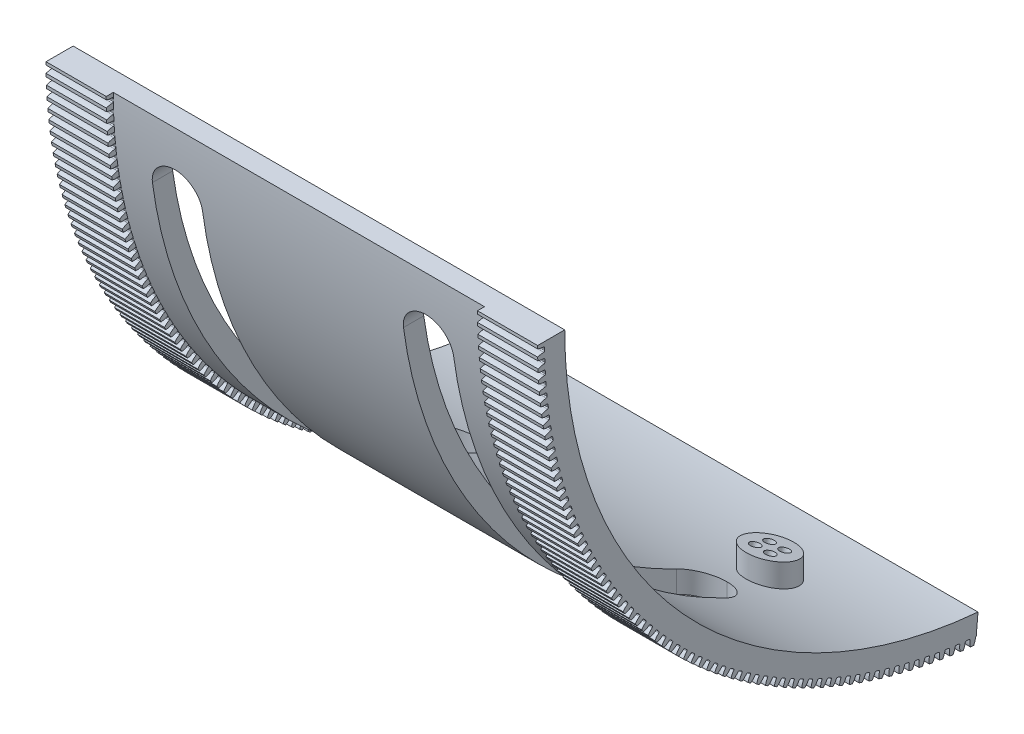
SolidWorks part; units mm, degrees
ref_plane "Alzado" through (0, 0, 0) normal (0, 0, 1) x (1, 0, 0)
ref_plane "Planta" through (0, 0, 0) normal (0, 1, 0) x (1, 0, 0)
ref_plane "Vista lateral" through (0, 0, 0) normal (1, 0, 0) x (0, 0, -1)
sketch "Croquis1" plane through (0, 0, 0) normal (1, 0, 0) x (0, 0, -1)
  line L0 (-188.5, 0) -> (-180.5, 0)
  line L2 (0, 0) -> (0, 120.2377) construction
  line L4 (-15.7316, -179.8131) -> (-16.4289, -187.7827)
  arc A2 (-180.5, 0) -> (-15.7316, -179.8131) centre (0, 0) ccw
  arc A3 (-188.5, 0) -> (-16.4289, -187.7827) centre (0, 0) ccw
  dimension "D1" = 188.5
  dimension "D2" = 180.5
extrude "Saliente-Extruir1" add sketch "Croquis1" along normal blind 196
ref_plane "Plano1" through (98, 0, 0) normal (1, 0, 0) x (0, 0, -1)
ref_plane "Plano2" through (148.05, 0, 0) normal (1, 0, 0) x (0, 0, -1)
ref_plane "Plano3" through (47.95, 0, 0) normal (1, 0, 0) x (0, 0, -1)
sketch "Croquis2" plane through (47.95, 0, 0) normal (1, 0, 0) x (0, 0, -1)
  line L0 (-180.5, 0) -> (-188.5, 0) construction
  line L1 (-187.9022, -15) -> (-67.9022, -15)
  line L2 (-187.9022, -15) -> (-187.9022, -175.8452)
  line L3 (-187.9022, -175.8452) -> (-67.9022, -175.8452)
  line L4 (-67.9022, -15) -> (-67.9022, -175.8452)
  arc A0 (-188.5, 0) -> (-16.4289, -187.7827) centre (0, 0) ccw construction
  dimension "D1" = 15
  dimension "D2" = 120
extrude "Cortar-Extruir1" cut sketch "Croquis2" against normal mid plane 20
mirror "Simetría1" about plane through (98, 0, 0) normal (1, 0, 0) of "Cortar-Extruir1"
fillet "Redondeo1" radius 10 8 edges at (138.05, -171.5431, 67.9022) (158.05, -171.5431, 67.9022) (57.95, -171.5431, 67.9022) (37.95, -171.5431, 67.9022) (138.05, -15, 183.8889) (158.05, -15, 183.8889) (57.95, -15, 183.8889) (37.95, -15, 183.8889)
ref_plane "Plano4" through (0, -179.8131, 0) normal (0, 1, 0) x (-1, 0, 0)
ref_plane "Plano5" through (0, -167.8131, 0) normal (0, 1, 0) x (-1, 0, 0)
sketch "Croquis3" plane through (0, -167.8131, 0) normal (0, 1, 0) x (1, 0, 0)
  line L0 (37.95, -77.9022) -> (57.95, -77.9022) construction
  line L1 (57.95, -77.9022) -> (47.95, -77.9022) construction
  line L2 (47.95, -77.9022) -> (47.95, -22.2024) construction
  line L3 (138.05, -77.9022) -> (158.05, -77.9022) construction
  line L4 (158.05, -77.9022) -> (148.05, -77.9022) construction
  line L5 (148.05, -77.9022) -> (148.05, -15.7316) construction
  line L6 (196, -15.7316) -> (0, -15.7316) construction
  circle A0 centre (148.05, -50.7316) radius 9.5
  circle A1 centre (47.95, -50.7316) radius 9.5
  point P18 (0, 0)
  dimension "D1" = 19
  dimension "D2" = 35
extrude "Saliente-Extruir2" add sketch "Croquis3" against normal blind 8.5 separate body
ref_axis "Eje1" through (148.05, -176.3131, 50.7316) along (0, 1, 0)
ref_plane "Plano6" through (148.05, 0, 0) normal (1, 0, 0) x (0, 1, 0)
sketch "Croquis4" plane through (148.05, 0, 0) normal (1, 0, 0) x (0, 1, 0)
  line L3 (-167.8131, 60.2316) -> (-167.8131, 41.2316)
  line L4 (-167.8131, 60.2316) -> (-161.0131, 60.2316)
  line L5 (-161.0131, 60.2316) -> (-166.9131, 41.2316)
  line L7 (-167.8131, 41.2316) -> (-166.9131, 41.2316)
  dimension "D1" = 6.8
  dimension "D2" = 0.9
extrude "Saliente-Extruir3" add sketch "Croquis4" along normal mid plane 19
sketch "Croquis5" plane through (0, -167.8131, 0) normal (0, 1, 0) x (-1, 0, 0)
  line L0 (-138.05, 178.7603) -> (-138.05, 77.9022) construction
  line L1 (-196, 15.7316) -> (0, 15.7316) construction
  circle A0 centre (-148.05, 50.7316) radius 9.5
  circle A2 centre (-148.05, 50.7316) radius 13.5
  point P5 (0, 0)
  dimension "D1" = 19
  dimension "D3" = 35
  dimension "D4" = 4
  dimension "D2" = 10
extrude "Cortar-Extruir2" cut sketch "Croquis5" along normal blind 19
sketch "Croquis11" plane through (47.95, 0, 0) normal (1, 0, 0) x (0, 0, -1)
  line L0 (-41.2316, -166.9131) -> (-60.2316, -161.0131)
  line L1 (-60.2316, -161.0131) -> (-60.2316, -167.8131)
  line L2 (107.8, -167.8131) -> (-107.8, -167.8131) construction
  line L3 (-60.2316, -167.8131) -> (-60.2316, -176.3131) construction
  line L4 (-60.2316, -167.8131) -> (-41.2316, -167.8131)
  line L5 (-41.2316, -175.7276) -> (-41.2316, -166.9131) construction
  line L6 (-41.2316, -167.8131) -> (-41.2316, -166.9131)
extrude "Saliente-Extruir4" add sketch "Croquis11" along normal mid plane 19
sketch "Croquis12" plane through (0, -167.8131, 0) normal (0, -1, 0) x (1, 0, 0)
  circle A0 centre (47.95, 50.7316) radius 9.5
  circle A1 centre (47.95, 50.7316) radius 13.5
  dimension "D1" = 19
  dimension "D2" = 4
extrude "Cortar-Extruir6" cut sketch "Croquis12" against normal blind 19
sketch "Croquis13" plane through (0, -163.9112, 50.8988) normal (0, 0.955, -0.2966) x (1, 0, 0)
  line L0 (138.55, 0.175) -> (157.55, 0.175) construction
  line L1 (157.55, 0.175) -> (148.05, 0.175) construction
  line L2 (148.05, 0.175) -> (148.05, 15.877) construction
  line L3 (38.45, 0.175) -> (57.45, 0.175) construction
  line L4 (57.45, 0.175) -> (47.95, 0.175) construction
  line L5 (47.95, 0.175) -> (47.95, 23.2003) construction
  circle A0 centre (145.05, 3.175) radius 2
  circle A1 centre (151.05, 3.175) radius 2
  circle A2 centre (151.05, -2.825) radius 2
  circle A3 centre (145.05, -2.825) radius 2
  circle A4 centre (44.95, 3.175) radius 2
  circle A5 centre (50.95, 3.175) radius 2
  circle A6 centre (50.95, -2.825) radius 2
  circle A7 centre (44.95, -2.825) radius 2
  dimension "D1" = 4
  dimension "D2" = 3
  dimension "D3" = 3
  dimension "D5" = 3
  dimension "D4" = 4
extrude "Cortar-Extruir7" cut sketch "Croquis13" against normal blind 24
sketch "Croquis15"
sketch "Croquis16" plane through (196, 0, 0) normal (1, 0, 0) x (0, 0, -1)
  circle A22 centre (-202.8544, -23.6484) radius 4.1232
sketch "Croquis17" plane through (196, 0, 0) normal (1, 0, 0) x (0, 0, -1)
  line L0 (-190.6017, -16.4583) -> (-190.5017, -17.729)
  line L1 (-187.566, -18.742) -> (-187.6698, -18.3283)
  line L2 (-187.8984, -15.4233) -> (-187.9021, -15.0017)
  line L3 (-188.1884, -11.349) -> (-188.183, -10.9274)
  line L4 (-190.9135, -12.3252) -> (-190.8411, -13.5977)
  line L5 (-187.928, -14.6741) -> (-188.0228, -14.2583)
  line L6 (-188.3901, -7.2693) -> (-188.3756, -6.848)
  line L7 (-191.1357, -8.1862) -> (-191.0909, -9.4601)
  line L8 (-188.2018, -10.5993) -> (-188.2875, -10.1815)
  line L9 (-188.5034, -3.1863) -> (-188.4797, -2.7653)
  line L10 (-191.2682, -4.0435) -> (-191.2509, -5.318)
  line L11 (-188.3872, -6.5195) -> (-188.4639, -6.1)
  line L12 (-188.4797, -2.7653) -> (-188.4843, -2.4367)
  line L13 (-191.3117, 0) -> (-191.3213, -1.1734)
  line L14 (-188.4843, -2.4367) -> (-188.5519, -2.0156)
  line L237 (-19.6611, -187.4718) -> (-19.988, -187.4373)
  line L238 (-23.718, -187.0019) -> (-24.044, -186.9602)
  line L239 (-27.7637, -186.4442) -> (-28.0888, -186.3955)
  line L240 (-31.7964, -185.7989) -> (-32.1203, -185.7432)
  line L241 (-35.8142, -185.0665) -> (-36.1368, -185.0037)
  line L242 (-39.8152, -184.2471) -> (-40.1364, -184.1774)
  line L243 (-43.7974, -183.3413) -> (-44.117, -183.2647)
  line L244 (-47.7591, -182.3494) -> (-48.077, -182.2659)
  line L245 (-51.6984, -181.272) -> (-52.0144, -181.1815)
  line L246 (-55.6135, -180.1094) -> (-55.9274, -180.0121)
  line L247 (-59.5024, -178.8623) -> (-59.8142, -178.7583)
  line L248 (-63.3634, -177.5312) -> (-63.6728, -177.4205)
  line L249 (-67.1946, -176.1168) -> (-67.5016, -175.9994)
  line L250 (-70.9943, -174.6197) -> (-71.2987, -174.4957)
  line L251 (-74.7607, -173.0407) -> (-75.0623, -172.9101)
  line L252 (-78.492, -171.3804) -> (-78.7907, -171.2433)
  line L253 (-82.1864, -169.6397) -> (-82.4821, -169.4962)
  line L254 (-85.8423, -167.8194) -> (-86.1348, -167.6695)
  line L255 (-89.4579, -165.9203) -> (-89.747, -165.764)
  line L256 (-93.0314, -163.9433) -> (-93.3172, -163.7808)
  line L257 (-96.5614, -161.8893) -> (-96.8435, -161.7207)
  line L258 (-100.0459, -159.7594) -> (-100.3243, -159.5847)
  line L259 (-103.4836, -157.5544) -> (-103.7581, -157.3738)
  line L260 (-106.8726, -155.2756) -> (-107.1432, -155.089)
  line L261 (-110.2115, -152.9238) -> (-110.478, -152.7314)
  line L262 (-113.4986, -150.5002) -> (-113.7609, -150.3021)
  line L263 (-116.7325, -148.006) -> (-116.9904, -147.8022)
  line L264 (-119.9116, -145.4423) -> (-120.165, -145.233)
  line L265 (-123.0343, -142.8104) -> (-123.2832, -142.5956)
  line L266 (-126.0994, -140.1114) -> (-126.3435, -139.8913)
  line L267 (-129.1052, -137.3466) -> (-129.3445, -137.1213)
  line L268 (-132.0505, -134.5174) -> (-132.2848, -134.2869)
  line L269 (-134.9337, -131.625) -> (-135.163, -131.3895)
  line L270 (-137.7536, -128.6708) -> (-137.9778, -128.4305)
  line L271 (-140.5089, -125.6563) -> (-140.7278, -125.4111)
  line L272 (-143.1982, -122.5827) -> (-143.4117, -122.3329)
  line L273 (-145.8203, -119.4517) -> (-146.0283, -119.1972)
  line L274 (-148.3739, -116.2645) -> (-148.5764, -116.0056)
  line L275 (-150.8579, -113.0228) -> (-151.0547, -112.7596)
  line L276 (-153.2711, -109.728) -> (-153.4621, -109.4606)
  line L277 (-155.6123, -106.3817) -> (-155.7975, -106.1102)
  line L278 (-157.8805, -102.9855) -> (-158.0598, -102.71)
  line L279 (-160.0745, -99.5409) -> (-160.2478, -99.2617)
  line L280 (-162.1935, -96.0496) -> (-162.3607, -95.7667)
  line L281 (-164.2363, -92.5133) -> (-164.3973, -92.2268)
  line L282 (-166.202, -88.9335) -> (-166.3568, -88.6435)
  line L283 (-168.0896, -85.3119) -> (-168.2381, -85.0187)
  line L284 (-169.8984, -81.6503) -> (-170.0405, -81.3539)
  line L285 (-171.6275, -77.9504) -> (-171.7631, -77.651)
  line L286 (-173.2759, -74.2139) -> (-173.4051, -73.9116)
  line L287 (-174.8431, -70.4425) -> (-174.9656, -70.1376)
  line L288 (-176.3281, -66.6381) -> (-176.4441, -66.3306)
  line L289 (-177.7304, -62.8024) -> (-177.8397, -62.4924)
  line L290 (-179.0493, -58.9373) -> (-179.1518, -58.625)
  line L291 (-180.2841, -55.0444) -> (-180.3798, -54.73)
  line L292 (-181.4343, -51.1257) -> (-181.5232, -50.8093)
  line L293 (-182.4993, -47.1831) -> (-182.5813, -46.8648)
  line L294 (-183.4787, -43.2182) -> (-183.5538, -42.8982)
  line L295 (-184.3719, -39.2331) -> (-184.4401, -38.9116)
  line L296 (-185.1786, -35.2296) -> (-185.2398, -34.9067)
  line L297 (-185.8984, -31.2095) -> (-185.9525, -30.8853)
  line L298 (-186.5309, -27.1748) -> (-186.578, -26.8495)
  line L299 (-187.0759, -23.1274) -> (-187.1159, -22.8011)
  line L300 (-187.533, -19.069) -> (-187.566, -18.742)
  line L301 (-187.9021, -15.0017) -> (-187.928, -14.6741)
  line L302 (-188.183, -10.9274) -> (-188.2018, -10.5993)
  line L303 (-188.3756, -6.848) -> (-188.3872, -6.5195)
  line L678 (-19.246, -187.5454) -> (-19.6611, -187.4718)
  line L679 (-18.7236, -190.3925) -> (-17.4561, -190.5269)
  line L681 (-23.3046, -187.0844) -> (-23.718, -187.0019)
  line L682 (-22.8439, -189.9422) -> (-21.5796, -190.104)
  line L683 (-19.988, -187.4373) -> (-20.4141, -187.4543)
  line L684 (-27.3522, -186.5356) -> (-27.7637, -186.4442)
  line L685 (-26.9536, -189.4027) -> (-25.6931, -189.5919)
  line L686 (-24.044, -186.9602) -> (-24.4705, -186.9681)
  line L687 (-31.3869, -185.8993) -> (-31.7964, -185.7989)
  line L688 (-31.0505, -188.7743) -> (-29.7944, -188.9907)
  line L689 (-28.0888, -186.3955) -> (-28.5153, -186.3941)
  line L690 (-35.407, -185.1757) -> (-35.8142, -185.0665)
  line L691 (-35.1329, -188.0573) -> (-33.8818, -188.3009)
  line L692 (-32.1203, -185.7432) -> (-32.5467, -185.7325)
  line L693 (-39.4104, -184.3651) -> (-39.8152, -184.2471)
  line L694 (-39.1989, -187.252) -> (-37.9533, -187.5227)
  line L695 (-36.1368, -185.0037) -> (-36.5629, -184.9838)
  line L696 (-43.3953, -183.4681) -> (-43.7974, -183.3413)
  line L697 (-43.2464, -186.3589) -> (-42.007, -186.6564)
  line L698 (-40.1364, -184.1774) -> (-40.5619, -184.1483)
  line L699 (-47.3599, -182.4849) -> (-47.7591, -182.3494)
  line L700 (-47.2736, -185.3782) -> (-46.0409, -185.7026)
  line L701 (-44.117, -183.2647) -> (-44.5418, -183.2263)
  line L702 (-51.3022, -181.416) -> (-51.6984, -181.272)
  line L703 (-51.2786, -184.3106) -> (-50.0533, -184.6615)
  line L704 (-48.077, -182.2659) -> (-48.5009, -182.2184)
  line L705 (-55.2204, -180.262) -> (-55.6135, -180.1094)
  line L706 (-55.2596, -183.1564) -> (-54.0421, -183.5338)
  line L707 (-52.0144, -181.1815) -> (-52.4371, -181.1248)
  line L708 (-59.1128, -179.0234) -> (-59.5024, -178.8623)
  line L709 (-59.2146, -181.9162) -> (-58.0056, -182.3199)
  line L710 (-55.9274, -180.0121) -> (-56.3488, -179.9463)
  line L711 (-62.9773, -177.7007) -> (-63.3634, -177.5312)
  line L712 (-63.1418, -180.5907) -> (-61.9418, -181.0205)
  line L713 (-59.8142, -178.7583) -> (-60.234, -178.6833)
  line L714 (-66.8123, -176.2946) -> (-67.1946, -176.1168)
  line L715 (-67.0394, -179.1804) -> (-65.849, -179.6361)
  line L716 (-63.6728, -177.4205) -> (-64.091, -177.3364)
  line L717 (-70.616, -174.8058) -> (-70.9943, -174.6197)
  line L718 (-70.9055, -177.6859) -> (-69.7253, -178.1673)
  line L719 (-67.5016, -175.9994) -> (-67.9178, -175.9063)
  line L720 (-74.3865, -173.2349) -> (-74.7607, -173.0407)
  line L721 (-74.7383, -176.1081) -> (-73.5688, -176.6149)
  line L722 (-71.2987, -174.4957) -> (-71.7128, -174.3936)
  line L723 (-78.1221, -171.5827) -> (-78.492, -171.3804)
  line L724 (-78.5361, -174.4476) -> (-77.3778, -174.9797)
  line L725 (-75.0623, -172.9101) -> (-75.4741, -172.7991)
  line L726 (-81.821, -169.85) -> (-82.1864, -169.6397)
  line L727 (-82.2969, -172.7052) -> (-81.1505, -173.2622)
  line L728 (-78.7907, -171.2433) -> (-79.2, -171.1234)
  line L729 (-85.4815, -168.0375) -> (-85.8423, -167.8194)
  line L730 (-86.0192, -170.8818) -> (-84.8851, -171.4635)
  line L731 (-82.4821, -169.4962) -> (-82.8887, -169.3674)
  line L732 (-89.1019, -166.1461) -> (-89.4579, -165.9203)
  line L733 (-89.7011, -168.9781) -> (-88.5798, -169.5843)
  line L734 (-86.1348, -167.6695) -> (-86.5385, -167.5319)
  line L735 (-92.6804, -164.1768) -> (-93.0314, -163.9433)
  line L736 (-93.3408, -166.9951) -> (-92.233, -167.6254)
  line L737 (-89.747, -165.764) -> (-90.1477, -165.6178)
  line L738 (-96.2155, -162.1304) -> (-96.5614, -161.8893)
  line L739 (-96.9368, -164.9337) -> (-95.8429, -165.5879)
  line L740 (-93.3172, -163.7808) -> (-93.7145, -163.6259)
  line L741 (-99.7053, -160.0079) -> (-100.0459, -159.7594)
  line L742 (-100.4872, -162.7949) -> (-99.4077, -163.4727)
  line L743 (-96.8435, -161.7207) -> (-97.2374, -161.5573)
  line L744 (-103.1484, -157.8103) -> (-103.4836, -157.5544)
  line L745 (-103.9905, -160.5797) -> (-102.9259, -161.2807)
  line L746 (-100.3243, -159.5847) -> (-100.7146, -159.4128)
  line L747 (-106.5431, -155.5386) -> (-106.8726, -155.2756)
  line L748 (-107.445, -158.2891) -> (-106.3958, -159.013)
  line L749 (-103.7581, -157.3738) -> (-104.1446, -157.1934)
  line L750 (-109.8878, -153.1939) -> (-110.2115, -152.9238)
  line L751 (-110.849, -155.9243) -> (-109.8158, -156.6707)
  line L752 (-107.1432, -155.089) -> (-107.5257, -154.9003)
  line L753 (-113.1808, -150.7773) -> (-113.4986, -150.5002)
  line L754 (-114.201, -153.4862) -> (-113.1842, -154.2548)
  line L755 (-110.478, -152.7314) -> (-110.8563, -152.5344)
  line L756 (-116.4208, -148.2899) -> (-116.7325, -148.006)
  line L757 (-117.4994, -150.9761) -> (-116.4995, -151.7665)
  line L758 (-113.7609, -150.3021) -> (-114.1348, -150.097)
  line L759 (-119.6061, -145.7329) -> (-119.9116, -145.4423)
  line L760 (-120.7426, -148.3951) -> (-119.7601, -149.207)
  line L761 (-116.9904, -147.8022) -> (-117.3598, -147.5891)
  line L762 (-122.7352, -143.1075) -> (-123.0343, -142.8104)
  line L763 (-123.9292, -145.7444) -> (-122.9645, -146.5774)
  line L764 (-120.165, -145.233) -> (-120.5297, -145.0119)
  line L765 (-125.8068, -140.4149) -> (-126.0994, -140.1114)
  line L766 (-127.0576, -143.0253) -> (-126.1111, -143.8791)
  line L767 (-123.2832, -142.5956) -> (-123.643, -142.3667)
  line L768 (-128.8192, -137.6564) -> (-129.1052, -137.3466)
  line L769 (-130.1263, -140.2391) -> (-129.1986, -141.1132)
  line L770 (-126.3435, -139.8913) -> (-126.6983, -139.6546)
  line L771 (-131.7713, -134.8333) -> (-132.0505, -134.5174)
  line L772 (-133.134, -137.3871) -> (-132.2254, -138.281)
  line L773 (-129.3445, -137.1213) -> (-129.6941, -136.877)
  line L774 (-134.6614, -131.9469) -> (-134.9337, -131.625)
  line L775 (-136.0792, -134.4706) -> (-135.1902, -135.384)
  line L776 (-132.2848, -134.2869) -> (-132.629, -134.0351)
  line L777 (-137.4884, -128.9986) -> (-137.7536, -128.6708)
  line L778 (-138.9605, -131.4909) -> (-138.0915, -132.4234)
  line L779 (-135.163, -131.3895) -> (-135.5017, -131.1303)
  line L780 (-140.2508, -125.9897) -> (-140.5089, -125.6563)
  line L781 (-141.7765, -128.4496) -> (-140.9279, -129.4006)
  line L782 (-137.9778, -128.4305) -> (-138.3108, -128.164)
  line L783 (-142.9474, -122.9216) -> (-143.1982, -122.5827)
  line L784 (-144.526, -125.3479) -> (-143.6983, -126.3171)
  line L785 (-140.7278, -125.4111) -> (-141.0549, -125.1375)
  line L786 (-145.5769, -119.7959) -> (-145.8203, -119.4517)
  line L787 (-147.2077, -122.1874) -> (-146.4011, -123.1743)
  line L788 (-143.4117, -122.3329) -> (-143.7328, -122.0522)
  line L789 (-148.138, -116.614) -> (-148.3739, -116.2645)
  line L790 (-149.8203, -118.9696) -> (-149.0353, -119.9737)
  line L791 (-146.0283, -119.1972) -> (-146.3433, -118.9097)
  line L792 (-150.6296, -113.3773) -> (-150.8579, -113.0228)
  line L793 (-152.3625, -115.6959) -> (-151.5995, -116.7168)
  line L794 (-148.5764, -116.0056) -> (-148.885, -115.7113)
  line L795 (-153.0505, -110.0873) -> (-153.2711, -109.728)
  line L796 (-154.8333, -112.3679) -> (-154.0925, -113.4051)
  line L797 (-151.0547, -112.7596) -> (-151.3569, -112.4586)
  line L798 (-155.3996, -106.7457) -> (-155.6123, -106.3817)
  line L799 (-157.2313, -108.9871) -> (-156.5132, -110.0401)
  line L800 (-153.4621, -109.4606) -> (-153.7578, -109.1532)
  line L801 (-157.6757, -103.354) -> (-157.8805, -102.9855)
  line L802 (-159.5556, -105.5552) -> (-158.8604, -106.6235)
  line L803 (-155.7975, -106.1102) -> (-156.0864, -105.7965)
  line L804 (-159.8778, -99.9138) -> (-160.0745, -99.5409)
  line L805 (-161.8049, -102.0737) -> (-161.1331, -103.1569)
  line L806 (-158.0598, -102.71) -> (-158.3418, -102.3901)
  line L807 (-162.0049, -96.4267) -> (-162.1935, -96.0496)
  line L808 (-163.9783, -98.5444) -> (-163.3301, -99.6418)
  line L809 (-160.2478, -99.2617) -> (-160.5229, -98.9357)
  line L810 (-164.0559, -92.8943) -> (-164.2363, -92.5133)
  line L811 (-166.0747, -94.9687) -> (-165.4504, -96.08)
  line L812 (-162.3607, -95.7667) -> (-162.6286, -95.4348)
  line L813 (-166.0299, -89.3183) -> (-166.202, -88.9335)
  line L814 (-168.0932, -91.3485) -> (-167.4931, -92.473)
  line L815 (-164.3973, -92.2268) -> (-164.658, -91.8892)
  line L816 (-167.9259, -85.7004) -> (-168.0896, -85.3119)
  line L817 (-170.0328, -87.6854) -> (-169.4572, -88.8227)
  line L818 (-166.3568, -88.6435) -> (-166.61, -88.3004)
  line L819 (-169.7432, -82.0423) -> (-169.8984, -81.6503)
  line L820 (-171.8925, -83.9812) -> (-171.3417, -85.1306)
  line L821 (-168.2381, -85.0187) -> (-168.4839, -84.6701)
  line L822 (-171.4807, -78.3456) -> (-171.6275, -77.9504)
  line L823 (-173.6716, -80.2375) -> (-173.1458, -81.3986)
  line L824 (-170.0405, -81.3539) -> (-170.2787, -81.0002)
  line L825 (-173.1378, -74.6122) -> (-173.2759, -74.2139)
  line L826 (-175.3691, -76.4562) -> (-174.8686, -77.6284)
  line L827 (-171.7631, -77.651) -> (-171.9936, -77.2921)
  line L828 (-174.7136, -70.8438) -> (-174.8431, -70.4425)
  line L829 (-176.9843, -72.639) -> (-176.5094, -73.8218)
  line L830 (-173.4051, -73.9116) -> (-173.6277, -73.5479)
  line L831 (-176.2074, -67.0421) -> (-176.3281, -66.6381)
  line L832 (-178.5165, -68.7876) -> (-178.0672, -69.9805)
  line L833 (-174.9656, -70.1376) -> (-175.1803, -69.769)
  line L834 (-177.6185, -63.2089) -> (-177.7304, -62.8024)
  line L835 (-179.9648, -64.904) -> (-179.5415, -66.1063)
  line L836 (-176.4441, -66.3306) -> (-176.6507, -65.9575)
  line L837 (-178.9462, -59.346) -> (-179.0493, -58.9373)
  line L838 (-181.3287, -60.99) -> (-180.9316, -62.2011)
  line L839 (-177.8397, -62.4924) -> (-178.0382, -62.115)
  line L840 (-180.1899, -55.4553) -> (-180.2841, -55.0444)
  line L841 (-182.6075, -57.0473) -> (-182.2366, -58.2667)
  line L842 (-179.1518, -58.625) -> (-179.3421, -58.2433)
  line L843 (-181.349, -51.5386) -> (-181.4343, -51.1257)
  line L844 (-183.8005, -53.0778) -> (-183.4562, -54.305)
  line L845 (-180.3798, -54.73) -> (-180.5618, -54.3443)
  line L846 (-182.423, -47.5977) -> (-182.4993, -47.1831)
  line L847 (-184.9073, -49.0834) -> (-184.5896, -50.3178)
  line L848 (-181.5232, -50.8093) -> (-181.6968, -50.4197)
  line L849 (-183.4113, -43.6344) -> (-183.4787, -43.2182)
  line L850 (-185.9272, -45.0659) -> (-185.6364, -46.3069)
  line L851 (-182.5813, -46.8648) -> (-182.7464, -46.4715)
  line L852 (-184.3136, -39.6507) -> (-184.3719, -39.2331)
  line L853 (-186.8599, -41.0274) -> (-186.5961, -42.2743)
  line L854 (-183.5538, -42.8982) -> (-183.7103, -42.5015)
  line L855 (-185.1294, -35.6483) -> (-185.1786, -35.2296)
  line L856 (-187.7049, -36.9695) -> (-187.4681, -38.2219)
  line L857 (-184.4401, -38.9116) -> (-184.588, -38.5116)
  line L858 (-185.8582, -31.6292) -> (-185.8984, -31.2095)
  line L859 (-188.4618, -32.8943) -> (-188.2522, -34.1516)
  line L860 (-185.2398, -34.9067) -> (-185.379, -34.5035)
  line L861 (-186.4998, -27.5953) -> (-186.5309, -27.1748)
  line L862 (-189.1302, -28.8037) -> (-188.9479, -30.0652)
  line L863 (-185.9525, -30.8853) -> (-186.083, -30.4793)
  line L864 (-187.0539, -23.5484) -> (-187.0759, -23.1274)
  line L865 (-189.7098, -24.6995) -> (-189.5549, -25.9646)
  line L866 (-186.578, -26.8495) -> (-186.6996, -26.4408)
  line L867 (-187.5201, -19.4904) -> (-187.533, -19.069)
  line L868 (-190.2004, -20.5837) -> (-190.0729, -21.8519)
  line L869 (-187.1159, -22.8011) -> (-187.2286, -22.3898)
  line L870 (-188.0717, 0) -> (-191.3117, 0)
  line L871 (-180.5, 0) -> (-188.5, 0) construction
  line L872 (-16.3118, -186.4442) -> (-16.4355, -187.8587)
  line L873 (-16.4289, -187.7827) -> (-15.7316, -179.8131) construction
  line L875 (-9.3097, 188.3003) -> (-8.8882, 188.2903) [skipped]
  line L876 (-10.2563, 191.0358) -> (-11.5296, 190.9772) [skipped]
  line L877 (-5.2281, 188.4578) -> (-4.8069, 188.4387) [skipped]
  line L878 (-6.1152, 191.2132) -> (-7.3894, 191.1821) [skipped]
  line L879 (-8.5599, 188.3055) -> (-8.1412, 188.3868) [skipped]
  line L880 (-1.144, 188.5268) -> (-0.7234, 188.4986) [skipped]
  line L881 (-1.9712, 191.3008) -> (-3.2458, 191.2973) [skipped]
  line L882 (-4.4784, 188.4468) -> (-4.058, 188.519) [skipped]
  line L883 (2.9406, 188.5074) -> (3.3605, 188.47) [skipped]
  line L884 (2.1736, 191.2986) -> (0.8993, 191.3228) [skipped]
  line L885 (-0.3947, 188.4996) -> (0.0271, 188.5626) [skipped]
  line L886 (7.0238, 188.3994) -> (7.4428, 188.353) [skipped]
  line L887 (6.3175, 191.2066) -> (5.044, 191.2584) [skipped]
  line L888 (3.6891, 188.4639) -> (4.1122, 188.5178) [skipped]
  line L889 (11.1037, 188.2031) -> (11.5216, 188.1476) [skipped]
  line L890 (10.4584, 191.0249) -> (9.1863, 191.1042) [skipped]
  line L891 (7.7712, 188.3397) -> (8.1954, 188.3844) [skipped]
  line L892 (15.1784, 187.9183) -> (15.5951, 187.8538) [skipped]
  line L893 (14.5944, 190.7535) -> (13.3243, 190.8603) [skipped]
  line L894 (11.8497, 188.1272) -> (12.2747, 188.1627) [skipped]
  line L895 (19.246, 187.5454) -> (19.6611, 187.4718) [skipped]
  line L896 (18.7236, 190.3925) -> (17.4561, 190.5269) [skipped]
  line L897 (15.9226, 187.8263) -> (16.3483, 187.8526) [skipped]
  line L898 (23.3046, 187.0844) -> (23.718, 187.0019) [skipped]
  line L899 (22.8439, 189.9422) -> (21.5796, 190.104) [skipped]
  line L900 (19.988, 187.4373) -> (20.4141, 187.4543) [skipped]
  line L901 (27.3522, 186.5356) -> (27.7637, 186.4442) [skipped]
  line L902 (26.9536, 189.4027) -> (25.6931, 189.5919) [skipped]
  line L903 (24.044, 186.9602) -> (24.4705, 186.9681) [skipped]
  line L904 (31.3869, 185.8993) -> (31.7964, 185.7989) [skipped]
  line L905 (31.0505, 188.7743) -> (29.7944, 188.9907) [skipped]
  line L906 (28.0888, 186.3955) -> (28.5153, 186.3941) [skipped]
  line L907 (35.407, 185.1757) -> (35.8142, 185.0665) [skipped]
  line L908 (35.1329, 188.0573) -> (33.8818, 188.3009) [skipped]
  line L909 (32.1203, 185.7432) -> (32.5467, 185.7325) [skipped]
  line L910 (39.4104, 184.3651) -> (39.8152, 184.2471) [skipped]
  line L911 (39.1989, 187.252) -> (37.9533, 187.5227) [skipped]
  line L912 (36.1368, 185.0037) -> (36.5629, 184.9838) [skipped]
  line L913 (43.3953, 183.4681) -> (43.7974, 183.3413) [skipped]
  line L914 (43.2464, 186.3589) -> (42.007, 186.6564) [skipped]
  line L915 (40.1364, 184.1774) -> (40.5619, 184.1483) [skipped]
  line L916 (47.3599, 182.4849) -> (47.7591, 182.3494) [skipped]
  line L917 (47.2736, 185.3782) -> (46.0409, 185.7026) [skipped]
  line L918 (44.117, 183.2647) -> (44.5418, 183.2263) [skipped]
  line L919 (51.3022, 181.416) -> (51.6984, 181.272) [skipped]
  line L920 (51.2786, 184.3106) -> (50.0533, 184.6615) [skipped]
  line L921 (48.077, 182.2659) -> (48.5009, 182.2184) [skipped]
  line L922 (55.2204, 180.262) -> (55.6135, 180.1094) [skipped]
  line L923 (55.2596, 183.1564) -> (54.0421, 183.5338) [skipped]
  line L924 (52.0144, 181.1815) -> (52.4371, 181.1248) [skipped]
  line L925 (59.1128, 179.0234) -> (59.5024, 178.8623) [skipped]
  line L926 (59.2146, 181.9162) -> (58.0056, 182.3199) [skipped]
  line L927 (55.9274, 180.0121) -> (56.3488, 179.9463) [skipped]
  line L928 (62.9773, 177.7007) -> (63.3634, 177.5312) [skipped]
  line L929 (63.1418, 180.5907) -> (61.9418, 181.0205) [skipped]
  line L930 (59.8142, 178.7583) -> (60.234, 178.6833) [skipped]
  line L931 (66.8123, 176.2946) -> (67.1946, 176.1168) [skipped]
  line L932 (67.0394, 179.1804) -> (65.849, 179.6361) [skipped]
  line L933 (63.6728, 177.4205) -> (64.091, 177.3364) [skipped]
  line L934 (70.616, 174.8058) -> (70.9943, 174.6197) [skipped]
  line L935 (70.9055, 177.6859) -> (69.7253, 178.1673) [skipped]
  line L936 (67.5016, 175.9994) -> (67.9178, 175.9063) [skipped]
  line L937 (74.3865, 173.2349) -> (74.7607, 173.0407) [skipped]
  line L938 (74.7383, 176.1081) -> (73.5688, 176.6149) [skipped]
  line L939 (71.2987, 174.4957) -> (71.7128, 174.3936) [skipped]
  line L940 (78.1221, 171.5827) -> (78.492, 171.3804) [skipped]
  line L941 (78.5361, 174.4476) -> (77.3778, 174.9797) [skipped]
  line L942 (75.0623, 172.9101) -> (75.4741, 172.7991) [skipped]
  line L943 (81.821, 169.85) -> (82.1864, 169.6397) [skipped]
  line L944 (82.2969, 172.7052) -> (81.1505, 173.2622) [skipped]
  line L945 (78.7907, 171.2433) -> (79.2, 171.1234) [skipped]
  line L946 (85.4815, 168.0375) -> (85.8423, 167.8194) [skipped]
  line L947 (86.0192, 170.8818) -> (84.8851, 171.4635) [skipped]
  line L948 (82.4821, 169.4962) -> (82.8887, 169.3674) [skipped]
  line L949 (89.1019, 166.1461) -> (89.4579, 165.9203) [skipped]
  line L950 (89.7011, 168.9781) -> (88.5798, 169.5843) [skipped]
  line L951 (86.1348, 167.6695) -> (86.5385, 167.5319) [skipped]
  line L952 (92.6804, 164.1768) -> (93.0314, 163.9433) [skipped]
  line L953 (93.3408, 166.9951) -> (92.233, 167.6254) [skipped]
  line L954 (89.747, 165.764) -> (90.1477, 165.6178) [skipped]
  line L955 (96.2155, 162.1304) -> (96.5614, 161.8893) [skipped]
  line L956 (96.9368, 164.9337) -> (95.8429, 165.5879) [skipped]
  line L957 (93.3172, 163.7808) -> (93.7145, 163.6259) [skipped]
  line L958 (99.7053, 160.0079) -> (100.0459, 159.7594) [skipped]
  line L959 (100.4872, 162.7949) -> (99.4077, 163.4727) [skipped]
  line L960 (96.8435, 161.7207) -> (97.2374, 161.5573) [skipped]
  line L961 (103.1484, 157.8103) -> (103.4836, 157.5544) [skipped]
  line L962 (103.9905, 160.5797) -> (102.9259, 161.2807) [skipped]
  line L963 (100.3243, 159.5847) -> (100.7146, 159.4128) [skipped]
  line L964 (106.5431, 155.5386) -> (106.8726, 155.2756) [skipped]
  line L965 (107.445, 158.2891) -> (106.3958, 159.013) [skipped]
  line L966 (103.7581, 157.3738) -> (104.1446, 157.1934) [skipped]
  line L967 (109.8878, 153.1939) -> (110.2115, 152.9238) [skipped]
  line L968 (110.849, 155.9243) -> (109.8158, 156.6707) [skipped]
  line L969 (107.1432, 155.089) -> (107.5257, 154.9003) [skipped]
  line L970 (113.1808, 150.7773) -> (113.4986, 150.5002) [skipped]
  line L971 (114.201, 153.4862) -> (113.1842, 154.2548) [skipped]
  line L972 (110.478, 152.7314) -> (110.8563, 152.5344) [skipped]
  line L973 (116.4208, 148.2899) -> (116.7325, 148.006) [skipped]
  line L974 (117.4994, 150.9761) -> (116.4995, 151.7665) [skipped]
  line L975 (113.7609, 150.3021) -> (114.1348, 150.097) [skipped]
  line L976 (119.6061, 145.7329) -> (119.9116, 145.4423) [skipped]
  line L977 (120.7426, 148.3951) -> (119.7601, 149.207) [skipped]
  line L978 (116.9904, 147.8022) -> (117.3598, 147.5891) [skipped]
  line L979 (122.7352, 143.1075) -> (123.0343, 142.8104) [skipped]
  line L980 (123.9292, 145.7444) -> (122.9645, 146.5774) [skipped]
  line L981 (120.165, 145.233) -> (120.5297, 145.0119) [skipped]
  line L982 (125.8068, 140.4149) -> (126.0994, 140.1114) [skipped]
  line L983 (127.0576, 143.0253) -> (126.1111, 143.8791) [skipped]
  line L984 (123.2832, 142.5956) -> (123.643, 142.3667) [skipped]
  line L985 (128.8192, 137.6564) -> (129.1052, 137.3466) [skipped]
  line L986 (130.1263, 140.2391) -> (129.1986, 141.1132) [skipped]
  line L987 (126.3435, 139.8913) -> (126.6983, 139.6546) [skipped]
  line L988 (131.7713, 134.8333) -> (132.0505, 134.5174) [skipped]
  line L989 (133.134, 137.3871) -> (132.2254, 138.281) [skipped]
  line L990 (129.3445, 137.1213) -> (129.6941, 136.877) [skipped]
  line L991 (134.6614, 131.9469) -> (134.9337, 131.625) [skipped]
  line L992 (136.0792, 134.4706) -> (135.1902, 135.384) [skipped]
  line L993 (132.2848, 134.2869) -> (132.629, 134.0351) [skipped]
  line L994 (137.4884, 128.9986) -> (137.7536, 128.6708) [skipped]
  line L995 (138.9605, 131.4909) -> (138.0915, 132.4234) [skipped]
  line L996 (135.163, 131.3895) -> (135.5017, 131.1303) [skipped]
  line L997 (140.2508, 125.9897) -> (140.5089, 125.6563) [skipped]
  line L998 (141.7765, 128.4496) -> (140.9279, 129.4006) [skipped]
  line L999 (137.9778, 128.4305) -> (138.3108, 128.164) [skipped]
  line L1000 (142.9474, 122.9216) -> (143.1982, 122.5827) [skipped]
  line L1001 (144.526, 125.3479) -> (143.6983, 126.3171) [skipped]
  line L1002 (140.7278, 125.4111) -> (141.0549, 125.1375) [skipped]
  line L1003 (145.5769, 119.7959) -> (145.8203, 119.4517) [skipped]
  line L1004 (147.2077, 122.1874) -> (146.4011, 123.1743) [skipped]
  line L1005 (143.4117, 122.3329) -> (143.7328, 122.0522) [skipped]
  line L1006 (148.138, 116.614) -> (148.3739, 116.2645) [skipped]
  line L1007 (149.8203, 118.9696) -> (149.0353, 119.9737) [skipped]
  line L1008 (146.0283, 119.1972) -> (146.3433, 118.9097) [skipped]
  line L1009 (150.6296, 113.3773) -> (150.8579, 113.0228) [skipped]
  line L1010 (152.3625, 115.6959) -> (151.5995, 116.7168) [skipped]
  line L1011 (148.5764, 116.0056) -> (148.885, 115.7113) [skipped]
  line L1012 (153.0505, 110.0873) -> (153.2711, 109.728) [skipped]
  line L1013 (154.8333, 112.3679) -> (154.0925, 113.4051) [skipped]
  line L1014 (151.0547, 112.7596) -> (151.3569, 112.4586) [skipped]
  line L1015 (155.3996, 106.7457) -> (155.6123, 106.3817) [skipped]
  line L1016 (157.2313, 108.9871) -> (156.5132, 110.0401) [skipped]
  line L1017 (153.4621, 109.4606) -> (153.7578, 109.1532) [skipped]
  line L1018 (157.6757, 103.354) -> (157.8805, 102.9855) [skipped]
  line L1019 (159.5556, 105.5552) -> (158.8604, 106.6235) [skipped]
  line L1020 (155.7975, 106.1102) -> (156.0864, 105.7965) [skipped]
  line L1021 (159.8778, 99.9138) -> (160.0745, 99.5409) [skipped]
  line L1022 (161.8049, 102.0737) -> (161.1331, 103.1569) [skipped]
  line L1023 (158.0598, 102.71) -> (158.3418, 102.3901) [skipped]
  line L1024 (162.0049, 96.4267) -> (162.1935, 96.0496) [skipped]
  line L1025 (163.9783, 98.5444) -> (163.3301, 99.6418) [skipped]
  line L1026 (160.2478, 99.2617) -> (160.5229, 98.9357) [skipped]
  line L1027 (164.0559, 92.8943) -> (164.2363, 92.5133) [skipped]
  line L1028 (166.0747, 94.9687) -> (165.4504, 96.08) [skipped]
  line L1029 (162.3607, 95.7667) -> (162.6286, 95.4348) [skipped]
  line L1030 (166.0299, 89.3183) -> (166.202, 88.9335) [skipped]
  line L1031 (168.0932, 91.3485) -> (167.4931, 92.473) [skipped]
  line L1032 (164.3973, 92.2268) -> (164.658, 91.8892) [skipped]
  line L1033 (167.9259, 85.7004) -> (168.0896, 85.3119) [skipped]
  line L1034 (170.0328, 87.6854) -> (169.4572, 88.8227) [skipped]
  line L1035 (166.3568, 88.6435) -> (166.61, 88.3004) [skipped]
  line L1036 (169.7432, 82.0423) -> (169.8984, 81.6503) [skipped]
  line L1037 (171.8925, 83.9812) -> (171.3417, 85.1306) [skipped]
  line L1038 (168.2381, 85.0187) -> (168.4839, 84.6701) [skipped]
  line L1039 (171.4807, 78.3456) -> (171.6275, 77.9504) [skipped]
  line L1040 (173.6716, 80.2375) -> (173.1458, 81.3986) [skipped]
  line L1041 (170.0405, 81.3539) -> (170.2787, 81.0002) [skipped]
  line L1042 (173.1378, 74.6122) -> (173.2759, 74.2139) [skipped]
  line L1043 (175.3691, 76.4562) -> (174.8686, 77.6284) [skipped]
  line L1044 (171.7631, 77.651) -> (171.9936, 77.2921) [skipped]
  line L1045 (174.7136, 70.8438) -> (174.8431, 70.4425) [skipped]
  line L1046 (176.9843, 72.639) -> (176.5094, 73.8218) [skipped]
  line L1047 (173.4051, 73.9116) -> (173.6277, 73.5479) [skipped]
  line L1048 (176.2074, 67.0421) -> (176.3281, 66.6381) [skipped]
  line L1049 (178.5165, 68.7876) -> (178.0672, 69.9805) [skipped]
  line L1050 (174.9656, 70.1376) -> (175.1803, 69.769) [skipped]
  line L1051 (177.6185, 63.2089) -> (177.7304, 62.8024) [skipped]
  line L1052 (179.9648, 64.904) -> (179.5415, 66.1063) [skipped]
  line L1053 (176.4441, 66.3306) -> (176.6507, 65.9575) [skipped]
  line L1054 (178.9462, 59.346) -> (179.0493, 58.9373) [skipped]
  line L1055 (181.3287, 60.99) -> (180.9316, 62.2011) [skipped]
  line L1056 (177.8397, 62.4924) -> (178.0382, 62.115) [skipped]
  line L1057 (180.1899, 55.4553) -> (180.2841, 55.0444) [skipped]
  line L1058 (182.6075, 57.0473) -> (182.2366, 58.2667) [skipped]
  line L1059 (179.1518, 58.625) -> (179.3421, 58.2433) [skipped]
  line L1060 (181.349, 51.5386) -> (181.4343, 51.1257) [skipped]
  line L1061 (183.8005, 53.0778) -> (183.4562, 54.305) [skipped]
  line L1062 (180.3798, 54.73) -> (180.5618, 54.3443) [skipped]
  line L1063 (182.423, 47.5977) -> (182.4993, 47.1831) [skipped]
  line L1064 (184.9073, 49.0834) -> (184.5896, 50.3178) [skipped]
  line L1065 (181.5232, 50.8093) -> (181.6968, 50.4197) [skipped]
  line L1066 (183.4113, 43.6344) -> (183.4787, 43.2182) [skipped]
  line L1067 (185.9272, 45.0659) -> (185.6364, 46.3069) [skipped]
  line L1068 (182.5813, 46.8648) -> (182.7464, 46.4715) [skipped]
  line L1069 (184.3136, 39.6507) -> (184.3719, 39.2331) [skipped]
  line L1070 (186.8599, 41.0274) -> (186.5961, 42.2743) [skipped]
  line L1071 (183.5538, 42.8982) -> (183.7103, 42.5015) [skipped]
  line L1072 (185.1294, 35.6483) -> (185.1786, 35.2296) [skipped]
  line L1073 (187.7049, 36.9695) -> (187.4681, 38.2219) [skipped]
  line L1074 (184.4401, 38.9116) -> (184.588, 38.5116) [skipped]
  line L1075 (185.8582, 31.6292) -> (185.8984, 31.2095) [skipped]
  line L1076 (188.4618, 32.8943) -> (188.2522, 34.1516) [skipped]
  line L1077 (185.2398, 34.9067) -> (185.379, 34.5035) [skipped]
  line L1078 (186.4998, 27.5953) -> (186.5309, 27.1748) [skipped]
  line L1079 (189.1302, 28.8037) -> (188.9479, 30.0652) [skipped]
  line L1080 (185.9525, 30.8853) -> (186.083, 30.4793) [skipped]
  line L1081 (187.0539, 23.5484) -> (187.0759, 23.1274) [skipped]
  line L1082 (189.7098, 24.6995) -> (189.5549, 25.9646) [skipped]
  line L1083 (186.578, 26.8495) -> (186.6996, 26.4408) [skipped]
  line L1084 (187.5201, 19.4904) -> (187.533, 19.069) [skipped]
  line L1085 (190.2004, 20.5837) -> (190.0729, 21.8519) [skipped]
  line L1086 (187.1159, 22.8011) -> (187.2286, 22.3898) [skipped]
  line L1087 (187.8984, 15.4233) -> (187.9021, 15.0017) [skipped]
  line L1088 (190.6017, 16.4583) -> (190.5017, 17.729) [skipped]
  line L1089 (187.566, 18.742) -> (187.6698, 18.3283) [skipped]
  line L1090 (188.1884, 11.349) -> (188.183, 10.9274) [skipped]
  line L1091 (190.9135, 12.3252) -> (190.8411, 13.5977) [skipped]
  line L1092 (187.928, 14.6741) -> (188.0228, 14.2583) [skipped]
  line L1093 (188.3901, 7.2693) -> (188.3756, 6.848) [skipped]
  line L1094 (191.1357, 8.1862) -> (191.0909, 9.4601) [skipped]
  line L1095 (188.2018, 10.5993) -> (188.2875, 10.1815) [skipped]
  line L1096 (188.5034, 3.1863) -> (188.4797, 2.7653) [skipped]
  line L1097 (191.2682, 4.0435) -> (191.2509, 5.318) [skipped]
  line L1098 (188.3872, 6.5195) -> (188.4639, 6.1) [skipped]
  line L1099 (188.5282, -0.8983) -> (188.4954, -1.3186) [skipped]
  line L1100 (191.3109, -0.1012) -> (191.3213, 1.1734) [skipped]
  line L1101 (188.4843, 2.4367) -> (188.5519, 2.0156) [skipped]
  line L1102 (188.4645, -4.9825) -> (188.4226, -5.402) [skipped]
  line L1103 (191.2638, -4.2458) -> (191.3018, -2.9718) [skipped]
  line L1104 (188.4928, -1.6473) -> (188.5513, -2.0698) [skipped]
  line L1105 (188.3123, -9.0643) -> (188.2613, -9.4828) [skipped]
  line L1106 (191.1269, -8.3885) -> (191.1925, -7.1155) [skipped]
  line L1107 (188.4129, -5.7305) -> (188.4622, -6.1541) [skipped]
  line L1108 (188.0717, -13.1418) -> (188.0117, -13.5591) [skipped]
  line L1109 (190.9004, -12.5272) -> (190.9935, -11.256) [skipped]
  line L1110 (188.2445, -9.811) -> (188.2846, -10.2356) [skipped]
  line L1111 (187.7429, -17.2132) -> (187.6738, -17.6291) [skipped]
  line L1112 (190.5842, -16.66) -> (190.7048, -15.3911) [skipped]
  line L1113 (187.9878, -13.8869) -> (188.0187, -14.3123) [skipped]
  line L1114 (187.3259, -21.2765) -> (187.2478, -21.6908) [skipped]
  line L1115 (190.1785, -20.785) -> (190.3266, -19.519) [skipped]
  line L1116 (187.6428, -17.9563) -> (187.6645, -18.3823) [skipped]
  line L1117 (186.821, -25.3298) -> (186.734, -25.7424) [skipped]
  line L1118 (189.6836, -24.9002) -> (189.8591, -23.6377) [skipped]
  line L1119 (187.2097, -22.0173) -> (187.2222, -22.4436) [skipped]
  line L1120 (186.2284, -29.3713) -> (186.1325, -29.7818) [skipped]
  line L1121 (189.0996, -29.0037) -> (189.3024, -27.7454) [skipped]
  line L1122 (186.6888, -26.0679) -> (186.692, -26.4944) [skipped]
  line L1123 (185.5484, -33.3989) -> (185.4436, -33.8073) [skipped]
  line L1124 (188.4269, -33.0937) -> (188.6569, -31.84) [skipped]
  line L1125 (186.0802, -30.1063) -> (186.0742, -30.5328) [skipped]
  line L1126 (184.7812, -37.4109) -> (184.6676, -37.8169) [skipped]
  line L1127 (187.6657, -37.1681) -> (187.9228, -35.9197) [skipped]
  line L1128 (185.3843, -34.1306) -> (185.3691, -34.5568) [skipped]
  line L1129 (183.9274, -41.4053) -> (183.805, -41.8087) [skipped]
  line L1130 (186.8164, -41.225) -> (187.1005, -39.9825) [skipped]
  line L1131 (184.6014, -38.1388) -> (184.5769, -38.5646) [skipped]
  line L1132 (182.9872, -45.3803) -> (182.8561, -45.781) [skipped]
  line L1133 (185.8795, -45.2626) -> (186.1904, -44.0265) [skipped]
  line L1134 (183.7318, -42.1292) -> (183.6981, -42.5543) [skipped]
  line L1135 (181.9611, -49.3339) -> (181.8214, -49.7317) [skipped]
  line L1136 (184.8552, -49.279) -> (185.1929, -48.0499) [skipped]
  line L1137 (182.776, -46.0997) -> (182.7331, -46.5241) [skipped]
  line L1138 (180.8496, -53.2644) -> (180.7013, -53.6591) [skipped]
  line L1139 (183.7442, -53.2722) -> (184.1085, -52.0508) [skipped]
  line L1140 (181.7344, -50.0487) -> (181.6823, -50.472) [skipped]
  line L1141 (179.6532, -57.17) -> (179.4964, -57.5613) [skipped]
  line L1142 (182.547, -57.2404) -> (182.9376, -56.0271) [skipped]
  line L1143 (180.6074, -53.9741) -> (180.5462, -54.3962) [skipped]
  line L1144 (178.3725, -61.0486) -> (178.2072, -61.4365) [skipped]
  line L1145 (181.2641, -61.1818) -> (181.6809, -59.9772) [skipped]
  line L1146 (179.3957, -57.8742) -> (179.3253, -58.2948) [skipped]
  line L1147 (177.008, -64.8986) -> (176.8344, -65.2828) [skipped]
  line L1148 (179.8961, -65.0944) -> (180.3388, -63.8992) [skipped]
  line L1149 (178.0998, -61.7471) -> (178.0203, -62.1661) [skipped]
  line L1150 (175.5605, -68.7182) -> (175.3786, -69.0985) [skipped]
  line L1151 (178.4436, -68.9765) -> (178.9122, -67.7911) [skipped]
  line L1152 (176.7203, -65.5911) -> (176.6317, -66.0083) [skipped]
  line L1153 (174.0306, -72.5055) -> (173.8404, -72.8818) [skipped]
  line L1154 (176.9074, -72.8262) -> (177.4015, -71.6513) [skipped]
  line L1155 (175.2578, -69.4042) -> (175.1603, -69.8194) [skipped]
  line L1156 (172.4189, -76.2587) -> (172.2207, -76.6308) [skipped]
  line L1157 (175.2881, -76.6417) -> (175.8076, -75.4777) [skipped]
  line L1158 (173.7131, -73.1848) -> (173.6065, -73.5978) [skipped]
  line L1159 (170.7263, -79.9762) -> (170.5201, -80.3439) [skipped]
  line L1160 (173.5866, -80.4212) -> (174.1312, -79.2688) [skipped]
  line L1161 (172.0868, -76.931) -> (171.9713, -77.3416) [skipped]
  line L1162 (168.9536, -83.6561) -> (168.7395, -84.0193) [skipped]
  line L1163 (171.8036, -84.163) -> (172.373, -83.0227) [skipped]
  line L1164 (170.3797, -80.6411) -> (170.2554, -81.0491) [skipped]
  line L1165 (167.1016, -87.2968) -> (166.8796, -87.6552) [skipped]
  line L1166 (169.9399, -87.8653) -> (170.5339, -86.7375) [skipped]
  line L1167 (168.5927, -84.3134) -> (168.4596, -84.7186) [skipped]
  line L1168 (165.1712, -90.8965) -> (164.9415, -91.25) [skipped]
  line L1169 (167.9965, -91.5263) -> (168.6147, -90.4117) [skipped]
  line L1170 (166.7265, -87.9461) -> (166.5847, -88.3483) [skipped]
  line L1171 (163.1632, -94.4535) -> (162.9259, -94.802) [skipped]
  line L1172 (165.9742, -95.1444) -> (166.6164, -94.0434) [skipped]
  line L1173 (164.7821, -91.5375) -> (164.6315, -91.9365) [skipped]
  line L1174 (161.0786, -97.9662) -> (160.8338, -98.3094) [skipped]
  line L1175 (163.874, -98.7178) -> (164.5399, -97.631) [skipped]
  line L1176 (162.7603, -95.0859) -> (162.6011, -95.4816) [skipped]
  line L1177 (158.9184, -101.4328) -> (158.6662, -101.7707) [skipped]
  line L1178 (161.6968, -102.2449) -> (162.3862, -101.1728) [skipped]
  line L1179 (160.6621, -98.5897) -> (160.4944, -98.9818) [skipped]
  line L1180 (156.6836, -104.8519) -> (156.4242, -105.1842) [skipped]
  line L1181 (159.4438, -105.7239) -> (160.1562, -104.667) [skipped]
  line L1182 (158.4885, -102.0472) -> (158.3124, -102.4356) [skipped]
  line L1183 (154.3753, -108.2218) -> (154.1087, -108.5484) [skipped]
  line L1184 (157.1159, -109.1534) -> (157.8511, -108.1122) [skipped]
  line L1185 (156.2405, -105.4568) -> (156.056, -105.8413) [skipped]
  line L1186 (151.9945, -111.5408) -> (151.7209, -111.8616) [skipped]
  line L1187 (154.7143, -112.5316) -> (155.4718, -111.5066) [skipped]
  line L1188 (153.9192, -108.817) -> (153.7264, -109.1974) [skipped]
  line L1189 (149.5423, -114.8075) -> (149.2619, -115.1223) [skipped]
  line L1190 (152.24, -115.857) -> (153.0196, -114.8486) [skipped]
  line L1191 (151.5256, -112.126) -> (151.3246, -112.5021) [skipped]
  line L1192 (147.02, -118.0203) -> (146.7328, -118.329) [skipped]
  line L1193 (149.6943, -119.128) -> (150.4956, -118.1367) [skipped]
  line L1194 (149.0609, -115.3824) -> (148.8518, -115.7541) [skipped]
  line L1195 (144.4286, -121.1778) -> (144.1348, -121.4801) [skipped]
  line L1196 (147.0784, -122.3431) -> (147.9009, -121.3694) [skipped]
  line L1197 (146.5262, -118.5846) -> (146.3091, -118.9517) [skipped]
  line L1198 (141.7695, -124.2783) -> (141.4692, -124.5742) [skipped]
  line L1199 (144.3933, -125.5008) -> (145.2368, -124.5451) [skipped]
  line L1200 (143.9228, -121.7312) -> (143.6977, -122.0935) [skipped]
  line L1201 (139.0438, -127.3205) -> (138.7371, -127.6098) [skipped]
  line L1202 (141.6405, -128.5995) -> (142.5045, -127.6624) [skipped]
  line L1203 (141.2517, -124.8207) -> (141.0189, -125.178) [skipped]
  line L1204 (136.2528, -130.3029) -> (135.94, -130.5855) [skipped]
  line L1205 (138.8213, -131.6379) -> (139.7053, -130.7197) [skipped]
  line L1206 (138.5144, -127.8515) -> (138.2739, -128.2037) [skipped]
  line L1207 (133.3979, -133.2242) -> (133.079, -133.4999) [skipped]
  line L1208 (135.9368, -134.6145) -> (136.8405, -133.7156) [skipped]
  line L1209 (135.7121, -130.8223) -> (135.464, -131.1692) [skipped]
  line L1210 (130.4804, -136.0829) -> (130.1556, -136.3517) [skipped]
  line L1211 (132.9886, -137.5279) -> (133.9115, -136.6488) [skipped]
  line L1212 (132.846, -133.7318) -> (132.5905, -134.0732) [skipped]
  line L1213 (127.5016, -138.8777) -> (127.171, -139.1394) [skipped]
  line L1214 (129.9779, -140.3767) -> (130.9197, -139.5179) [skipped]
  line L1215 (129.9176, -136.5784) -> (129.6547, -136.9143) [skipped]
  line L1216 (124.463, -141.6074) -> (124.1268, -141.8619) [skipped]
  line L1217 (126.9062, -143.1597) -> (127.8664, -142.3214) [skipped]
  line L1218 (126.9282, -139.361) -> (126.6581, -139.691) [skipped]
  line L1219 (121.3659, -144.2706) -> (121.0243, -144.5177) [skipped]
  line L1220 (123.7749, -145.8754) -> (124.7531, -145.0582) [skipped]
  line L1221 (123.8793, -142.0781) -> (123.6021, -142.4022) [skipped]
  line L1222 (118.2119, -146.866) -> (117.865, -147.1057) [skipped]
  line L1223 (120.5856, -148.5227) -> (121.5812, -147.7269) [skipped]
  line L1224 (120.7721, -144.7285) -> (120.488, -145.0466) [skipped]
  line L1225 (115.0024, -149.3926) -> (114.6504, -149.6247) [skipped]
  line L1226 (117.3396, -151.1003) -> (118.3522, -150.3262) [skipped]
  line L1227 (117.6083, -147.311) -> (117.3174, -147.6228) [skipped]
  line L1228 (111.7388, -151.849) -> (111.3819, -152.0734) [skipped]
  line L1229 (114.0386, -153.6069) -> (115.0677, -152.8549) [skipped]
  line L1230 (114.3893, -149.8243) -> (114.0917, -150.1298) [skipped]
  line L1231 (108.4229, -154.2341) -> (108.0612, -154.4507) [skipped]
  line L1232 (110.684, -156.0414) -> (111.7292, -155.3119) [skipped]
  line L1233 (111.1166, -152.2674) -> (110.8124, -152.5663) [skipped]
  line L1234 (105.0561, -156.5468) -> (104.6897, -156.7556) [skipped]
  line L1235 (107.2774, -158.4027) -> (108.3382, -157.696) [skipped]
  line L1236 (107.7917, -154.6389) -> (107.4811, -154.9312) [skipped]
  line L1237 (101.6399, -158.7861) -> (101.2692, -158.9868) [skipped]
  line L1238 (103.8206, -160.6897) -> (104.8964, -160.0061) [skipped]
  line L1239 (104.4163, -156.9379) -> (104.0994, -157.2233) [skipped]
  line L1240 (98.176, -160.9508) -> (97.801, -161.1434) [skipped]
  line L1241 (100.3149, -162.9012) -> (101.4053, -162.2411) [skipped]
  line L1242 (100.9918, -159.1632) -> (100.6688, -159.4417) [skipped]
  line L1243 (94.6661, -163.0399) -> (94.287, -163.2244) [skipped]
  line L1244 (96.7622, -165.0362) -> (97.8666, -164.3999) [skipped]
  line L1245 (97.5199, -161.3137) -> (97.191, -161.5852) [skipped]
  line L1246 (91.1117, -165.0525) -> (90.7287, -165.2288) [skipped]
  line L1247 (93.1641, -167.0938) -> (94.282, -166.4815) [skipped]
  line L1248 (94.0022, -163.3886) -> (93.6675, -163.6529) [skipped]
  line L1249 (87.5145, -166.9877) -> (87.1278, -167.1556) [skipped]
  line L1250 (89.5222, -169.0729) -> (90.6532, -168.485) [skipped]
  line L1251 (90.4404, -165.3867) -> (90.1001, -165.6437) [skipped]
  line L1252 (83.8763, -168.8445) -> (83.486, -169.004) [skipped]
  line L1253 (85.8383, -170.9727) -> (86.9818, -170.4094) [skipped]
  line L1254 (86.8362, -167.3073) -> (86.4903, -167.5568) [skipped]
  line L1255 (80.1987, -170.622) -> (79.805, -170.773) [skipped]
  line L1256 (82.1142, -172.7922) -> (83.2695, -172.2539) [skipped]
  line L1257 (83.1912, -169.1493) -> (82.84, -169.3913) [skipped]
  line L1258 (76.4834, -172.3194) -> (76.0866, -172.4618) [skipped]
  line L1259 (78.3514, -174.5306) -> (79.5182, -174.0174) [skipped]
  line L1260 (79.5071, -170.9119) -> (79.1508, -171.1462) [skipped]
  line L1261 (72.7323, -173.9359) -> (72.3325, -174.0697) [skipped]
  line L1262 (74.5519, -176.1871) -> (75.7295, -175.6993) [skipped]
  line L1263 (75.7858, -172.5942) -> (75.4244, -172.8208) [skipped]
  line L1264 (68.947, -175.4708) -> (68.5443, -175.5959) [skipped]
  line L1265 (70.7175, -177.7608) -> (71.9053, -177.2987) [skipped]
  line L1266 (72.0288, -174.1956) -> (71.6627, -174.4142) [skipped]
  line L1267 (65.1293, -176.9233) -> (64.7241, -177.0397) [skipped]
  line L1268 (66.8498, -179.2512) -> (68.0474, -178.8149) [skipped]
  line L1269 (68.2381, -175.7152) -> (67.8672, -175.9258) [skipped]
  line L1270 (61.2811, -178.2928) -> (60.8734, -178.4003) [skipped]
  line L1271 (62.9507, -180.6574) -> (64.1575, -180.2471) [skipped]
  line L1272 (64.4153, -177.1523) -> (64.04, -177.3549) [skipped]
  line L1273 (57.4041, -179.5785) -> (56.9942, -179.6772) [skipped]
  line L1274 (59.0221, -181.9788) -> (60.2375, -181.5948) [skipped]
  line L1275 (60.5623, -178.5062) -> (60.1827, -178.7006) [skipped]
  line L1276 (53.5001, -180.78) -> (53.0882, -180.8698) [skipped]
  line L1277 (55.0657, -183.2147) -> (56.2892, -182.8571) [skipped]
  line L1278 (56.6808, -179.7764) -> (56.2971, -179.9625) [skipped]
  line L1279 (49.5711, -181.8966) -> (49.1573, -181.9775) [skipped]
  line L1280 (51.0836, -184.3647) -> (52.3144, -184.0337) [skipped]
  line L1281 (52.7727, -180.9621) -> (52.3851, -181.1399) [skipped]
  line L1282 (45.6187, -182.9279) -> (45.2033, -182.9998) [skipped]
  line L1283 (47.0774, -185.4281) -> (48.3152, -185.1239) [skipped]
  line L1284 (48.8399, -182.0629) -> (48.4485, -182.2323) [skipped]
  line L1285 (41.645, -183.8733) -> (41.2281, -183.9361) [skipped]
  line L1286 (43.0492, -186.4045) -> (44.2932, -186.1271) [skipped]
  line L1287 (44.8841, -183.0783) -> (44.4891, -183.2391) [skipped]
  line L1288 (37.6517, -184.7323) -> (37.2335, -184.7861) [skipped]
  line L1289 (39.0007, -187.2934) -> (40.2505, -187.0431) [skipped]
  line L1290 (40.9073, -184.0077) -> (40.5089, -184.16) [skipped]
  line L1291 (33.6407, -185.5047) -> (33.2215, -185.5494) [skipped]
  line L1292 (34.934, -188.0944) -> (36.1889, -187.8712) [skipped]
  line L1293 (36.9113, -184.8508) -> (36.5097, -184.9943) [skipped]
  line L1294 (29.614, -186.1899) -> (29.1939, -186.2256) [skipped]
  line L1295 (30.8508, -188.8071) -> (32.1102, -188.6111) [skipped]
  line L1296 (32.8979, -185.607) -> (32.4933, -185.7419) [skipped]
  line L1297 (25.5733, -186.7878) -> (25.1526, -186.8143) [skipped]
  line L1298 (26.7531, -189.4311) -> (28.0165, -189.2625) [skipped]
  line L1299 (28.8691, -186.2762) -> (28.4617, -186.4022) [skipped]
  line L1300 (21.5207, -187.298) -> (21.0994, -187.3154) [skipped]
  line L1301 (22.6429, -189.9662) -> (23.9097, -189.825) [skipped]
  line L1302 (24.8268, -186.8579) -> (24.4167, -186.9751) [skipped]
  line L1303 (17.4579, -187.7203) -> (17.0364, -187.7286) [skipped]
  line L1304 (18.5221, -190.4122) -> (19.7916, -190.2984) [skipped]
  line L1305 (20.7728, -187.3519) -> (20.3603, -187.4602) [skipped]
  line L1306 (13.387, -188.0544) -> (12.9653, -188.0536) [skipped]
  line L1307 (14.3926, -190.7688) -> (15.6643, -190.6826) [skipped]
  line L1308 (16.709, -187.758) -> (16.2943, -187.8573) [skipped]
  line L1309 (9.3097, -188.3003) -> (8.8882, -188.2903) [skipped]
  line L1310 (10.2563, -191.0358) -> (11.5296, -190.9772) [skipped]
  line L1311 (12.6374, -188.0759) -> (12.2206, -188.1662) [skipped]
  line L1312 (5.2281, -188.4578) -> (4.8069, -188.4387) [skipped]
  line L1313 (6.1152, -191.2132) -> (7.3894, -191.1821) [skipped]
  line L1314 (8.5599, -188.3055) -> (8.1412, -188.3868) [skipped]
  line L1315 (1.144, -188.5268) -> (0.7234, -188.4986) [skipped]
  line L1316 (1.9712, -191.3008) -> (3.2458, -191.2973) [skipped]
  line L1317 (4.4784, -188.4468) -> (4.058, -188.519) [skipped]
  line L1318 (-2.9406, -188.5074) -> (-3.3605, -188.47) [skipped]
  line L1319 (-2.1736, -191.2986) -> (-0.8993, -191.3228) [skipped]
  line L1320 (0.3947, -188.4996) -> (-0.0271, -188.5626) [skipped]
  line L1321 (-7.0238, -188.3994) -> (-7.4428, -188.353) [skipped]
  line L1322 (-6.3175, -191.2066) -> (-5.044, -191.2584) [skipped]
  line L1323 (-3.6891, -188.4639) -> (-4.1122, -188.5178) [skipped]
  line L1324 (-10.4584, -191.0249) -> (-9.1863, -191.1042) [skipped]
  line L1325 (-7.7712, -188.3397) -> (-8.1954, -188.3844) [skipped]
  line L1326 (-188.4645, 4.9825) -> (-188.4226, 5.402) [skipped]
  line L1327 (-191.2638, 4.2458) -> (-191.3018, 2.9718) [skipped]
  line L1328 (-188.3123, 9.0643) -> (-188.2613, 9.4828) [skipped]
  line L1329 (-191.1269, 8.3885) -> (-191.1925, 7.1155) [skipped]
  line L1330 (-188.4129, 5.7305) -> (-188.4622, 6.1541) [skipped]
  line L1331 (-188.0717, 13.1418) -> (-188.0117, 13.5591) [skipped]
  line L1332 (-190.9004, 12.5272) -> (-190.9935, 11.256) [skipped]
  line L1333 (-188.2445, 9.811) -> (-188.2846, 10.2356) [skipped]
  line L1334 (-187.7429, 17.2132) -> (-187.6738, 17.6291) [skipped]
  line L1335 (-190.5842, 16.66) -> (-190.7048, 15.3911) [skipped]
  line L1336 (-187.9878, 13.8869) -> (-188.0187, 14.3123) [skipped]
  line L1337 (-187.3259, 21.2765) -> (-187.2478, 21.6908) [skipped]
  line L1338 (-190.1785, 20.785) -> (-190.3266, 19.519) [skipped]
  line L1339 (-187.6428, 17.9563) -> (-187.6645, 18.3823) [skipped]
  line L1340 (-186.821, 25.3298) -> (-186.734, 25.7424) [skipped]
  line L1341 (-189.6836, 24.9002) -> (-189.8591, 23.6377) [skipped]
  line L1342 (-187.2097, 22.0173) -> (-187.2222, 22.4436) [skipped]
  line L1343 (-186.2284, 29.3713) -> (-186.1325, 29.7818) [skipped]
  line L1344 (-189.0996, 29.0037) -> (-189.3024, 27.7454) [skipped]
  line L1345 (-186.6888, 26.0679) -> (-186.692, 26.4944) [skipped]
  line L1346 (-185.5484, 33.3989) -> (-185.4436, 33.8073) [skipped]
  line L1347 (-188.4269, 33.0937) -> (-188.6569, 31.84) [skipped]
  line L1348 (-186.0802, 30.1063) -> (-186.0742, 30.5328) [skipped]
  line L1349 (-184.7812, 37.4109) -> (-184.6676, 37.8169) [skipped]
  line L1350 (-187.6657, 37.1681) -> (-187.9228, 35.9197) [skipped]
  line L1351 (-185.3843, 34.1306) -> (-185.3691, 34.5568) [skipped]
  line L1352 (-183.9274, 41.4053) -> (-183.805, 41.8087) [skipped]
  line L1353 (-186.8164, 41.225) -> (-187.1005, 39.9825) [skipped]
  line L1354 (-184.6014, 38.1388) -> (-184.5769, 38.5646) [skipped]
  line L1355 (-182.9872, 45.3803) -> (-182.8561, 45.781) [skipped]
  line L1356 (-185.8795, 45.2626) -> (-186.1904, 44.0265) [skipped]
  line L1357 (-183.7318, 42.1292) -> (-183.6981, 42.5543) [skipped]
  line L1358 (-181.9611, 49.3339) -> (-181.8214, 49.7317) [skipped]
  line L1359 (-184.8552, 49.279) -> (-185.1929, 48.0499) [skipped]
  line L1360 (-182.776, 46.0997) -> (-182.7331, 46.5241) [skipped]
  line L1361 (-180.8496, 53.2644) -> (-180.7013, 53.6591) [skipped]
  line L1362 (-183.7442, 53.2722) -> (-184.1085, 52.0508) [skipped]
  line L1363 (-181.7344, 50.0487) -> (-181.6823, 50.472) [skipped]
  line L1364 (-179.6532, 57.17) -> (-179.4964, 57.5613) [skipped]
  line L1365 (-182.547, 57.2404) -> (-182.9376, 56.0271) [skipped]
  line L1366 (-180.6074, 53.9741) -> (-180.5462, 54.3962) [skipped]
  line L1367 (-178.3725, 61.0486) -> (-178.2072, 61.4365) [skipped]
  line L1368 (-181.2641, 61.1818) -> (-181.6809, 59.9772) [skipped]
  line L1369 (-179.3957, 57.8742) -> (-179.3253, 58.2948) [skipped]
  line L1370 (-177.008, 64.8986) -> (-176.8344, 65.2828) [skipped]
  line L1371 (-179.8961, 65.0944) -> (-180.3388, 63.8992) [skipped]
  line L1372 (-178.0998, 61.7471) -> (-178.0203, 62.1661) [skipped]
  line L1373 (-175.5605, 68.7182) -> (-175.3786, 69.0985) [skipped]
  line L1374 (-178.4436, 68.9765) -> (-178.9122, 67.7911) [skipped]
  line L1375 (-176.7203, 65.5911) -> (-176.6317, 66.0083) [skipped]
  line L1376 (-174.0306, 72.5055) -> (-173.8404, 72.8818) [skipped]
  line L1377 (-176.9074, 72.8262) -> (-177.4015, 71.6513) [skipped]
  line L1378 (-175.2578, 69.4042) -> (-175.1603, 69.8194) [skipped]
  line L1379 (-172.4189, 76.2587) -> (-172.2207, 76.6308) [skipped]
  line L1380 (-175.2881, 76.6417) -> (-175.8076, 75.4777) [skipped]
  line L1381 (-173.7131, 73.1848) -> (-173.6065, 73.5978) [skipped]
  line L1382 (-170.7263, 79.9762) -> (-170.5201, 80.3439) [skipped]
  line L1383 (-173.5866, 80.4212) -> (-174.1312, 79.2688) [skipped]
  line L1384 (-172.0868, 76.931) -> (-171.9713, 77.3416) [skipped]
  line L1385 (-168.9536, 83.6561) -> (-168.7395, 84.0193) [skipped]
  line L1386 (-171.8036, 84.163) -> (-172.373, 83.0227) [skipped]
  line L1387 (-170.3797, 80.6411) -> (-170.2554, 81.0491) [skipped]
  line L1388 (-167.1016, 87.2968) -> (-166.8796, 87.6552) [skipped]
  line L1389 (-169.9399, 87.8653) -> (-170.5339, 86.7375) [skipped]
  line L1390 (-168.5927, 84.3134) -> (-168.4596, 84.7186) [skipped]
  line L1391 (-165.1712, 90.8965) -> (-164.9415, 91.25) [skipped]
  line L1392 (-167.9965, 91.5263) -> (-168.6147, 90.4117) [skipped]
  line L1393 (-166.7265, 87.9461) -> (-166.5847, 88.3483) [skipped]
  line L1394 (-163.1632, 94.4535) -> (-162.9259, 94.802) [skipped]
  line L1395 (-165.9742, 95.1444) -> (-166.6164, 94.0434) [skipped]
  line L1396 (-164.7821, 91.5375) -> (-164.6315, 91.9365) [skipped]
  line L1397 (-161.0786, 97.9662) -> (-160.8338, 98.3094) [skipped]
  line L1398 (-163.874, 98.7178) -> (-164.5399, 97.631) [skipped]
  line L1399 (-162.7603, 95.0859) -> (-162.6011, 95.4816) [skipped]
  line L1400 (-158.9184, 101.4328) -> (-158.6662, 101.7707) [skipped]
  line L1401 (-161.6968, 102.2449) -> (-162.3862, 101.1728) [skipped]
  line L1402 (-160.6621, 98.5897) -> (-160.4944, 98.9818) [skipped]
  line L1403 (-156.6836, 104.8519) -> (-156.4242, 105.1842) [skipped]
  line L1404 (-159.4438, 105.7239) -> (-160.1562, 104.667) [skipped]
  line L1405 (-158.4885, 102.0472) -> (-158.3124, 102.4356) [skipped]
  line L1406 (-154.3753, 108.2218) -> (-154.1087, 108.5484) [skipped]
  line L1407 (-157.1159, 109.1534) -> (-157.8511, 108.1122) [skipped]
  line L1408 (-156.2405, 105.4568) -> (-156.056, 105.8413) [skipped]
  line L1409 (-151.9945, 111.5408) -> (-151.7209, 111.8616) [skipped]
  line L1410 (-154.7143, 112.5316) -> (-155.4718, 111.5066) [skipped]
  line L1411 (-153.9192, 108.817) -> (-153.7264, 109.1974) [skipped]
  line L1412 (-149.5423, 114.8075) -> (-149.2619, 115.1223) [skipped]
  line L1413 (-152.24, 115.857) -> (-153.0196, 114.8486) [skipped]
  line L1414 (-151.5256, 112.126) -> (-151.3246, 112.5021) [skipped]
  line L1415 (-147.02, 118.0203) -> (-146.7328, 118.329) [skipped]
  line L1416 (-149.6943, 119.128) -> (-150.4956, 118.1367) [skipped]
  line L1417 (-149.0609, 115.3824) -> (-148.8518, 115.7541) [skipped]
  line L1418 (-144.4286, 121.1778) -> (-144.1348, 121.4801) [skipped]
  line L1419 (-147.0784, 122.3431) -> (-147.9009, 121.3694) [skipped]
  line L1420 (-146.5262, 118.5846) -> (-146.3091, 118.9517) [skipped]
  line L1421 (-141.7695, 124.2783) -> (-141.4692, 124.5742) [skipped]
  line L1422 (-144.3933, 125.5008) -> (-145.2368, 124.5451) [skipped]
  line L1423 (-143.9228, 121.7312) -> (-143.6977, 122.0935) [skipped]
  line L1424 (-139.0438, 127.3205) -> (-138.7371, 127.6098) [skipped]
  line L1425 (-141.6405, 128.5995) -> (-142.5045, 127.6624) [skipped]
  line L1426 (-141.2517, 124.8207) -> (-141.0189, 125.178) [skipped]
  line L1427 (-136.2528, 130.3029) -> (-135.94, 130.5855) [skipped]
  line L1428 (-138.8213, 131.6379) -> (-139.7053, 130.7197) [skipped]
  line L1429 (-138.5144, 127.8515) -> (-138.2739, 128.2037) [skipped]
  line L1430 (-133.3979, 133.2242) -> (-133.079, 133.4999) [skipped]
  line L1431 (-135.9368, 134.6145) -> (-136.8405, 133.7156) [skipped]
  line L1432 (-135.7121, 130.8223) -> (-135.464, 131.1692) [skipped]
  line L1433 (-130.4804, 136.0829) -> (-130.1556, 136.3517) [skipped]
  line L1434 (-132.9886, 137.5279) -> (-133.9115, 136.6488) [skipped]
  line L1435 (-132.846, 133.7318) -> (-132.5905, 134.0732) [skipped]
  line L1436 (-127.5016, 138.8777) -> (-127.171, 139.1394) [skipped]
  line L1437 (-129.9779, 140.3767) -> (-130.9197, 139.5179) [skipped]
  line L1438 (-129.9176, 136.5784) -> (-129.6547, 136.9143) [skipped]
  line L1439 (-124.463, 141.6074) -> (-124.1268, 141.8619) [skipped]
  line L1440 (-126.9062, 143.1597) -> (-127.8664, 142.3214) [skipped]
  line L1441 (-126.9282, 139.361) -> (-126.6581, 139.691) [skipped]
  line L1442 (-121.3659, 144.2706) -> (-121.0243, 144.5177) [skipped]
  line L1443 (-123.7749, 145.8754) -> (-124.7531, 145.0582) [skipped]
  line L1444 (-123.8793, 142.0781) -> (-123.6021, 142.4022) [skipped]
  line L1445 (-118.2119, 146.866) -> (-117.865, 147.1057) [skipped]
  line L1446 (-120.5856, 148.5227) -> (-121.5812, 147.7269) [skipped]
  line L1447 (-120.7721, 144.7285) -> (-120.488, 145.0466) [skipped]
  line L1448 (-115.0024, 149.3926) -> (-114.6504, 149.6247) [skipped]
  line L1449 (-117.3396, 151.1003) -> (-118.3522, 150.3262) [skipped]
  line L1450 (-117.6083, 147.311) -> (-117.3174, 147.6228) [skipped]
  line L1451 (-111.7388, 151.849) -> (-111.3819, 152.0734) [skipped]
  line L1452 (-114.0386, 153.6069) -> (-115.0677, 152.8549) [skipped]
  line L1453 (-114.3893, 149.8243) -> (-114.0917, 150.1298) [skipped]
  line L1454 (-108.4229, 154.2341) -> (-108.0612, 154.4507) [skipped]
  line L1455 (-110.684, 156.0414) -> (-111.7292, 155.3119) [skipped]
  line L1456 (-111.1166, 152.2674) -> (-110.8124, 152.5663) [skipped]
  line L1457 (-105.0561, 156.5468) -> (-104.6897, 156.7556) [skipped]
  line L1458 (-107.2774, 158.4027) -> (-108.3382, 157.696) [skipped]
  line L1459 (-107.7917, 154.6389) -> (-107.4811, 154.9312) [skipped]
  line L1460 (-101.6399, 158.7861) -> (-101.2692, 158.9868) [skipped]
  line L1461 (-103.8206, 160.6897) -> (-104.8964, 160.0061) [skipped]
  line L1462 (-104.4163, 156.9379) -> (-104.0994, 157.2233) [skipped]
  line L1463 (-98.176, 160.9508) -> (-97.801, 161.1434) [skipped]
  line L1464 (-100.3149, 162.9012) -> (-101.4053, 162.2411) [skipped]
  line L1465 (-100.9918, 159.1632) -> (-100.6688, 159.4417) [skipped]
  line L1466 (-94.6661, 163.0399) -> (-94.287, 163.2244) [skipped]
  line L1467 (-96.7622, 165.0362) -> (-97.8666, 164.3999) [skipped]
  line L1468 (-97.5199, 161.3137) -> (-97.191, 161.5852) [skipped]
  line L1469 (-91.1117, 165.0525) -> (-90.7287, 165.2288) [skipped]
  line L1470 (-93.1641, 167.0938) -> (-94.282, 166.4815) [skipped]
  line L1471 (-94.0022, 163.3886) -> (-93.6675, 163.6529) [skipped]
  line L1472 (-87.5145, 166.9877) -> (-87.1278, 167.1556) [skipped]
  line L1473 (-89.5222, 169.0729) -> (-90.6532, 168.485) [skipped]
  line L1474 (-90.4404, 165.3867) -> (-90.1001, 165.6437) [skipped]
  line L1475 (-83.8763, 168.8445) -> (-83.486, 169.004) [skipped]
  line L1476 (-85.8383, 170.9727) -> (-86.9818, 170.4094) [skipped]
  line L1477 (-86.8362, 167.3073) -> (-86.4903, 167.5568) [skipped]
  line L1478 (-80.1987, 170.622) -> (-79.805, 170.773) [skipped]
  line L1479 (-82.1142, 172.7922) -> (-83.2695, 172.2539) [skipped]
  line L1480 (-83.1912, 169.1493) -> (-82.84, 169.3913) [skipped]
  line L1481 (-76.4834, 172.3194) -> (-76.0866, 172.4618) [skipped]
  line L1482 (-78.3514, 174.5306) -> (-79.5182, 174.0174) [skipped]
  line L1483 (-79.5071, 170.9119) -> (-79.1508, 171.1462) [skipped]
  line L1484 (-72.7323, 173.9359) -> (-72.3325, 174.0697) [skipped]
  line L1485 (-74.5519, 176.1871) -> (-75.7295, 175.6993) [skipped]
  line L1486 (-75.7858, 172.5942) -> (-75.4244, 172.8208) [skipped]
  line L1487 (-68.947, 175.4708) -> (-68.5443, 175.5959) [skipped]
  line L1488 (-70.7175, 177.7608) -> (-71.9053, 177.2987) [skipped]
  line L1489 (-72.0288, 174.1956) -> (-71.6627, 174.4142) [skipped]
  line L1490 (-65.1293, 176.9233) -> (-64.7241, 177.0397) [skipped]
  line L1491 (-66.8498, 179.2512) -> (-68.0474, 178.8149) [skipped]
  line L1492 (-68.2381, 175.7152) -> (-67.8672, 175.9258) [skipped]
  line L1493 (-61.2811, 178.2928) -> (-60.8734, 178.4003) [skipped]
  line L1494 (-62.9507, 180.6574) -> (-64.1575, 180.2471) [skipped]
  line L1495 (-64.4153, 177.1523) -> (-64.04, 177.3549) [skipped]
  line L1496 (-57.4041, 179.5785) -> (-56.9942, 179.6772) [skipped]
  line L1497 (-59.0221, 181.9788) -> (-60.2375, 181.5948) [skipped]
  line L1498 (-60.5623, 178.5062) -> (-60.1827, 178.7006) [skipped]
  line L1499 (-53.5001, 180.78) -> (-53.0882, 180.8698) [skipped]
  line L1500 (-55.0657, 183.2147) -> (-56.2892, 182.8571) [skipped]
  line L1501 (-56.6808, 179.7764) -> (-56.2971, 179.9625) [skipped]
  line L1502 (-49.5711, 181.8966) -> (-49.1573, 181.9775) [skipped]
  line L1503 (-51.0836, 184.3647) -> (-52.3144, 184.0337) [skipped]
  line L1504 (-52.7727, 180.9621) -> (-52.3851, 181.1399) [skipped]
  line L1505 (-45.6187, 182.9279) -> (-45.2033, 182.9998) [skipped]
  line L1506 (-47.0774, 185.4281) -> (-48.3152, 185.1239) [skipped]
  line L1507 (-48.8399, 182.0629) -> (-48.4485, 182.2323) [skipped]
  line L1508 (-41.645, 183.8733) -> (-41.2281, 183.9361) [skipped]
  line L1509 (-43.0492, 186.4045) -> (-44.2932, 186.1271) [skipped]
  line L1510 (-44.8841, 183.0783) -> (-44.4891, 183.2391) [skipped]
  line L1511 (-37.6517, 184.7323) -> (-37.2335, 184.7861) [skipped]
  line L1512 (-39.0007, 187.2934) -> (-40.2505, 187.0431) [skipped]
  line L1513 (-40.9073, 184.0077) -> (-40.5089, 184.16) [skipped]
  line L1514 (-33.6407, 185.5047) -> (-33.2215, 185.5494) [skipped]
  line L1515 (-34.934, 188.0944) -> (-36.1889, 187.8712) [skipped]
  line L1516 (-36.9113, 184.8508) -> (-36.5097, 184.9943) [skipped]
  line L1517 (-29.614, 186.1899) -> (-29.1939, 186.2256) [skipped]
  line L1518 (-30.8508, 188.8071) -> (-32.1102, 188.6111) [skipped]
  line L1519 (-32.8979, 185.607) -> (-32.4933, 185.7419) [skipped]
  line L1520 (-25.5733, 186.7878) -> (-25.1526, 186.8143) [skipped]
  line L1521 (-26.7531, 189.4311) -> (-28.0165, 189.2625) [skipped]
  line L1522 (-28.8691, 186.2762) -> (-28.4617, 186.4022) [skipped]
  line L1523 (-21.5207, 187.298) -> (-21.0994, 187.3154) [skipped]
  line L1524 (-22.6429, 189.9662) -> (-23.9097, 189.825) [skipped]
  line L1525 (-24.8268, 186.8579) -> (-24.4167, 186.9751) [skipped]
  line L1526 (-17.4579, 187.7203) -> (-17.0364, 187.7286) [skipped]
  line L1527 (-18.5221, 190.4122) -> (-19.7916, 190.2984) [skipped]
  line L1528 (-20.7728, 187.3519) -> (-20.3603, 187.4602) [skipped]
  line L1529 (-13.387, 188.0544) -> (-12.9653, 188.0536) [skipped]
  line L1530 (-14.3926, 190.7688) -> (-15.6643, 190.6826) [skipped]
  line L1531 (-16.709, 187.758) -> (-16.2943, 187.8573) [skipped]
  line L1532 (-12.6374, 188.0759) -> (-12.2206, 188.1662) [skipped]
  line L1533 (-188.5282, 0.8983) -> (-188.4954, 1.3186) [skipped]
  line L1534 (-188.4928, 1.6473) -> (-188.5513, 2.0698) [skipped]
  line L1535 (-11.1037, -188.2031) -> (-11.5216, -188.1476) [skipped]
  line L1536 (-11.8497, -188.1272) -> (-12.2747, -188.1627) [skipped]
  line L1537 (-14.5944, -190.7535) -> (-13.3243, -190.8603) [skipped]
  line L1538 (-15.1784, -187.9183) -> (-15.5951, -187.8538) [skipped]
  line L1539 (-15.9226, -187.8263) -> (-16.3483, -187.8526) [skipped]
  line L1540 (-8.8882, 188.2903) -> (-8.5599, 188.3055) [skipped]
  line L1541 (-4.8069, 188.4387) -> (-4.4784, 188.4468) [skipped]
  line L1542 (-0.7234, 188.4986) -> (-0.3947, 188.4996) [skipped]
  line L1543 (3.3605, 188.47) -> (3.6891, 188.4639) [skipped]
  line L1544 (7.4428, 188.353) -> (7.7712, 188.3397) [skipped]
  line L1545 (11.5216, 188.1476) -> (11.8497, 188.1272) [skipped]
  line L1546 (15.5951, 187.8538) -> (15.9226, 187.8263) [skipped]
  line L1547 (19.6611, 187.4718) -> (19.988, 187.4373) [skipped]
  line L1548 (23.718, 187.0019) -> (24.044, 186.9602) [skipped]
  line L1549 (27.7637, 186.4442) -> (28.0888, 186.3955) [skipped]
  line L1550 (31.7964, 185.7989) -> (32.1203, 185.7432) [skipped]
  line L1551 (35.8142, 185.0665) -> (36.1368, 185.0037) [skipped]
  line L1552 (39.8152, 184.2471) -> (40.1364, 184.1774) [skipped]
  line L1553 (43.7974, 183.3413) -> (44.117, 183.2647) [skipped]
  line L1554 (47.7591, 182.3494) -> (48.077, 182.2659) [skipped]
  line L1555 (51.6984, 181.272) -> (52.0144, 181.1815) [skipped]
  line L1556 (55.6135, 180.1094) -> (55.9274, 180.0121) [skipped]
  line L1557 (59.5024, 178.8623) -> (59.8142, 178.7583) [skipped]
  line L1558 (63.3634, 177.5312) -> (63.6728, 177.4205) [skipped]
  line L1559 (67.1946, 176.1168) -> (67.5016, 175.9994) [skipped]
  line L1560 (70.9943, 174.6197) -> (71.2987, 174.4957) [skipped]
  line L1561 (74.7607, 173.0407) -> (75.0623, 172.9101) [skipped]
  line L1562 (78.492, 171.3804) -> (78.7907, 171.2433) [skipped]
  line L1563 (82.1864, 169.6397) -> (82.4821, 169.4962) [skipped]
  line L1564 (85.8423, 167.8194) -> (86.1348, 167.6695) [skipped]
  line L1565 (89.4579, 165.9203) -> (89.747, 165.764) [skipped]
  line L1566 (93.0314, 163.9433) -> (93.3172, 163.7808) [skipped]
  line L1567 (96.5614, 161.8893) -> (96.8435, 161.7207) [skipped]
  line L1568 (100.0459, 159.7594) -> (100.3243, 159.5847) [skipped]
  line L1569 (103.4836, 157.5544) -> (103.7581, 157.3738) [skipped]
  line L1570 (106.8726, 155.2756) -> (107.1432, 155.089) [skipped]
  line L1571 (110.2115, 152.9238) -> (110.478, 152.7314) [skipped]
  line L1572 (113.4986, 150.5002) -> (113.7609, 150.3021) [skipped]
  line L1573 (116.7325, 148.006) -> (116.9904, 147.8022) [skipped]
  line L1574 (119.9116, 145.4423) -> (120.165, 145.233) [skipped]
  line L1575 (123.0343, 142.8104) -> (123.2832, 142.5956) [skipped]
  line L1576 (126.0994, 140.1114) -> (126.3435, 139.8913) [skipped]
  line L1577 (129.1052, 137.3466) -> (129.3445, 137.1213) [skipped]
  line L1578 (132.0505, 134.5174) -> (132.2848, 134.2869) [skipped]
  line L1579 (134.9337, 131.625) -> (135.163, 131.3895) [skipped]
  line L1580 (137.7536, 128.6708) -> (137.9778, 128.4305) [skipped]
  line L1581 (140.5089, 125.6563) -> (140.7278, 125.4111) [skipped]
  line L1582 (143.1982, 122.5827) -> (143.4117, 122.3329) [skipped]
  line L1583 (145.8203, 119.4517) -> (146.0283, 119.1972) [skipped]
  line L1584 (148.3739, 116.2645) -> (148.5764, 116.0056) [skipped]
  line L1585 (150.8579, 113.0228) -> (151.0547, 112.7596) [skipped]
  line L1586 (153.2711, 109.728) -> (153.4621, 109.4606) [skipped]
  line L1587 (155.6123, 106.3817) -> (155.7975, 106.1102) [skipped]
  line L1588 (157.8805, 102.9855) -> (158.0598, 102.71) [skipped]
  line L1589 (160.0745, 99.5409) -> (160.2478, 99.2617) [skipped]
  line L1590 (162.1935, 96.0496) -> (162.3607, 95.7667) [skipped]
  line L1591 (164.2363, 92.5133) -> (164.3973, 92.2268) [skipped]
  line L1592 (166.202, 88.9335) -> (166.3568, 88.6435) [skipped]
  line L1593 (168.0896, 85.3119) -> (168.2381, 85.0187) [skipped]
  line L1594 (169.8984, 81.6503) -> (170.0405, 81.3539) [skipped]
  line L1595 (171.6275, 77.9504) -> (171.7631, 77.651) [skipped]
  line L1596 (173.2759, 74.2139) -> (173.4051, 73.9116) [skipped]
  line L1597 (174.8431, 70.4425) -> (174.9656, 70.1376) [skipped]
  line L1598 (176.3281, 66.6381) -> (176.4441, 66.3306) [skipped]
  line L1599 (177.7304, 62.8024) -> (177.8397, 62.4924) [skipped]
  line L1600 (179.0493, 58.9373) -> (179.1518, 58.625) [skipped]
  line L1601 (180.2841, 55.0444) -> (180.3798, 54.73) [skipped]
  line L1602 (181.4343, 51.1257) -> (181.5232, 50.8093) [skipped]
  line L1603 (182.4993, 47.1831) -> (182.5813, 46.8648) [skipped]
  line L1604 (183.4787, 43.2182) -> (183.5538, 42.8982) [skipped]
  line L1605 (184.3719, 39.2331) -> (184.4401, 38.9116) [skipped]
  line L1606 (185.1786, 35.2296) -> (185.2398, 34.9067) [skipped]
  line L1607 (185.8984, 31.2095) -> (185.9525, 30.8853) [skipped]
  line L1608 (186.5309, 27.1748) -> (186.578, 26.8495) [skipped]
  line L1609 (187.0759, 23.1274) -> (187.1159, 22.8011) [skipped]
  line L1610 (187.533, 19.069) -> (187.566, 18.742) [skipped]
  line L1611 (187.9021, 15.0017) -> (187.928, 14.6741) [skipped]
  line L1612 (188.183, 10.9274) -> (188.2018, 10.5993) [skipped]
  line L1613 (188.3756, 6.848) -> (188.3872, 6.5195) [skipped]
  line L1614 (188.4797, 2.7653) -> (188.4843, 2.4367) [skipped]
  line L1615 (188.4954, -1.3186) -> (188.4928, -1.6473) [skipped]
  line L1616 (188.4226, -5.402) -> (188.4129, -5.7305) [skipped]
  line L1617 (188.2613, -9.4828) -> (188.2445, -9.811) [skipped]
  line L1618 (188.0117, -13.5591) -> (187.9878, -13.8869) [skipped]
  line L1619 (187.6738, -17.6291) -> (187.6428, -17.9563) [skipped]
  line L1620 (187.2478, -21.6908) -> (187.2097, -22.0173) [skipped]
  line L1621 (186.734, -25.7424) -> (186.6888, -26.0679) [skipped]
  line L1622 (186.1325, -29.7818) -> (186.0802, -30.1063) [skipped]
  line L1623 (185.4436, -33.8073) -> (185.3843, -34.1306) [skipped]
  line L1624 (184.6676, -37.8169) -> (184.6014, -38.1388) [skipped]
  line L1625 (183.805, -41.8087) -> (183.7318, -42.1292) [skipped]
  line L1626 (182.8561, -45.781) -> (182.776, -46.0997) [skipped]
  line L1627 (181.8214, -49.7317) -> (181.7344, -50.0487) [skipped]
  line L1628 (180.7013, -53.6591) -> (180.6074, -53.9741) [skipped]
  line L1629 (179.4964, -57.5613) -> (179.3957, -57.8742) [skipped]
  line L1630 (178.2072, -61.4365) -> (178.0998, -61.7471) [skipped]
  line L1631 (176.8344, -65.2828) -> (176.7203, -65.5911) [skipped]
  line L1632 (175.3786, -69.0985) -> (175.2578, -69.4042) [skipped]
  line L1633 (173.8404, -72.8818) -> (173.7131, -73.1848) [skipped]
  line L1634 (172.2207, -76.6308) -> (172.0868, -76.931) [skipped]
  line L1635 (170.5201, -80.3439) -> (170.3797, -80.6411) [skipped]
  line L1636 (168.7395, -84.0193) -> (168.5927, -84.3134) [skipped]
  line L1637 (166.8796, -87.6552) -> (166.7265, -87.9461) [skipped]
  line L1638 (164.9415, -91.25) -> (164.7821, -91.5375) [skipped]
  line L1639 (162.9259, -94.802) -> (162.7603, -95.0859) [skipped]
  line L1640 (160.8338, -98.3094) -> (160.6621, -98.5897) [skipped]
  line L1641 (158.6662, -101.7707) -> (158.4885, -102.0472) [skipped]
  line L1642 (156.4242, -105.1842) -> (156.2405, -105.4568) [skipped]
  line L1643 (154.1087, -108.5484) -> (153.9192, -108.817) [skipped]
  line L1644 (151.7209, -111.8616) -> (151.5256, -112.126) [skipped]
  line L1645 (149.2619, -115.1223) -> (149.0609, -115.3824) [skipped]
  line L1646 (146.7328, -118.329) -> (146.5262, -118.5846) [skipped]
  line L1647 (144.1348, -121.4801) -> (143.9228, -121.7312) [skipped]
  line L1648 (141.4692, -124.5742) -> (141.2517, -124.8207) [skipped]
  line L1649 (138.7371, -127.6098) -> (138.5144, -127.8515) [skipped]
  line L1650 (135.94, -130.5855) -> (135.7121, -130.8223) [skipped]
  line L1651 (133.079, -133.4999) -> (132.846, -133.7318) [skipped]
  line L1652 (130.1556, -136.3517) -> (129.9176, -136.5784) [skipped]
  line L1653 (127.171, -139.1394) -> (126.9282, -139.361) [skipped]
  line L1654 (124.1268, -141.8619) -> (123.8793, -142.0781) [skipped]
  line L1655 (121.0243, -144.5177) -> (120.7721, -144.7285) [skipped]
  line L1656 (117.865, -147.1057) -> (117.6083, -147.311) [skipped]
  line L1657 (114.6504, -149.6247) -> (114.3893, -149.8243) [skipped]
  line L1658 (111.3819, -152.0734) -> (111.1166, -152.2674) [skipped]
  line L1659 (108.0612, -154.4507) -> (107.7917, -154.6389) [skipped]
  line L1660 (104.6897, -156.7556) -> (104.4163, -156.9379) [skipped]
  line L1661 (101.2692, -158.9868) -> (100.9918, -159.1632) [skipped]
  line L1662 (97.801, -161.1434) -> (97.5199, -161.3137) [skipped]
  line L1663 (94.287, -163.2244) -> (94.0022, -163.3886) [skipped]
  line L1664 (90.7287, -165.2288) -> (90.4404, -165.3867) [skipped]
  line L1665 (87.1278, -167.1556) -> (86.8362, -167.3073) [skipped]
  line L1666 (83.486, -169.004) -> (83.1912, -169.1493) [skipped]
  line L1667 (79.805, -170.773) -> (79.5071, -170.9119) [skipped]
  line L1668 (76.0866, -172.4618) -> (75.7858, -172.5942) [skipped]
  line L1669 (72.3325, -174.0697) -> (72.0288, -174.1956) [skipped]
  line L1670 (68.5443, -175.5959) -> (68.2381, -175.7152) [skipped]
  line L1671 (64.7241, -177.0397) -> (64.4153, -177.1523) [skipped]
  line L1672 (60.8734, -178.4003) -> (60.5623, -178.5062) [skipped]
  line L1673 (56.9942, -179.6772) -> (56.6808, -179.7764) [skipped]
  line L1674 (53.0882, -180.8698) -> (52.7727, -180.9621) [skipped]
  line L1675 (49.1573, -181.9775) -> (48.8399, -182.0629) [skipped]
  line L1676 (45.2033, -182.9998) -> (44.8841, -183.0783) [skipped]
  line L1677 (41.2281, -183.9361) -> (40.9073, -184.0077) [skipped]
  line L1678 (37.2335, -184.7861) -> (36.9113, -184.8508) [skipped]
  line L1679 (33.2215, -185.5494) -> (32.8979, -185.607) [skipped]
  line L1680 (29.1939, -186.2256) -> (28.8691, -186.2762) [skipped]
  line L1681 (25.1526, -186.8143) -> (24.8268, -186.8579) [skipped]
  line L1682 (21.0994, -187.3154) -> (20.7728, -187.3519) [skipped]
  line L1683 (17.0364, -187.7286) -> (16.709, -187.758) [skipped]
  line L1684 (12.9653, -188.0536) -> (12.6374, -188.0759) [skipped]
  line L1685 (8.8882, -188.2903) -> (8.5599, -188.3055) [skipped]
  line L1686 (4.8069, -188.4387) -> (4.4784, -188.4468) [skipped]
  line L1687 (0.7234, -188.4986) -> (0.3947, -188.4996) [skipped]
  line L1688 (-3.3605, -188.47) -> (-3.6891, -188.4639) [skipped]
  line L1689 (-7.4428, -188.353) -> (-7.7712, -188.3397) [skipped]
  line L1690 (-188.4226, 5.402) -> (-188.4129, 5.7305) [skipped]
  line L1691 (-188.2613, 9.4828) -> (-188.2445, 9.811) [skipped]
  line L1692 (-188.0117, 13.5591) -> (-187.9878, 13.8869) [skipped]
  line L1693 (-187.6738, 17.6291) -> (-187.6428, 17.9563) [skipped]
  line L1694 (-187.2478, 21.6908) -> (-187.2097, 22.0173) [skipped]
  line L1695 (-186.734, 25.7424) -> (-186.6888, 26.0679) [skipped]
  line L1696 (-186.1325, 29.7818) -> (-186.0802, 30.1063) [skipped]
  line L1697 (-185.4436, 33.8073) -> (-185.3843, 34.1306) [skipped]
  line L1698 (-184.6676, 37.8169) -> (-184.6014, 38.1388) [skipped]
  line L1699 (-183.805, 41.8087) -> (-183.7318, 42.1292) [skipped]
  line L1700 (-182.8561, 45.781) -> (-182.776, 46.0997) [skipped]
  line L1701 (-181.8214, 49.7317) -> (-181.7344, 50.0487) [skipped]
  line L1702 (-180.7013, 53.6591) -> (-180.6074, 53.9741) [skipped]
  line L1703 (-179.4964, 57.5613) -> (-179.3957, 57.8742) [skipped]
  line L1704 (-178.2072, 61.4365) -> (-178.0998, 61.7471) [skipped]
  line L1705 (-176.8344, 65.2828) -> (-176.7203, 65.5911) [skipped]
  line L1706 (-175.3786, 69.0985) -> (-175.2578, 69.4042) [skipped]
  line L1707 (-173.8404, 72.8818) -> (-173.7131, 73.1848) [skipped]
  line L1708 (-172.2207, 76.6308) -> (-172.0868, 76.931) [skipped]
  line L1709 (-170.5201, 80.3439) -> (-170.3797, 80.6411) [skipped]
  line L1710 (-168.7395, 84.0193) -> (-168.5927, 84.3134) [skipped]
  line L1711 (-166.8796, 87.6552) -> (-166.7265, 87.9461) [skipped]
  line L1712 (-164.9415, 91.25) -> (-164.7821, 91.5375) [skipped]
  line L1713 (-162.9259, 94.802) -> (-162.7603, 95.0859) [skipped]
  line L1714 (-160.8338, 98.3094) -> (-160.6621, 98.5897) [skipped]
  line L1715 (-158.6662, 101.7707) -> (-158.4885, 102.0472) [skipped]
  line L1716 (-156.4242, 105.1842) -> (-156.2405, 105.4568) [skipped]
  line L1717 (-154.1087, 108.5484) -> (-153.9192, 108.817) [skipped]
  line L1718 (-151.7209, 111.8616) -> (-151.5256, 112.126) [skipped]
  line L1719 (-149.2619, 115.1223) -> (-149.0609, 115.3824) [skipped]
  line L1720 (-146.7328, 118.329) -> (-146.5262, 118.5846) [skipped]
  line L1721 (-144.1348, 121.4801) -> (-143.9228, 121.7312) [skipped]
  line L1722 (-141.4692, 124.5742) -> (-141.2517, 124.8207) [skipped]
  line L1723 (-138.7371, 127.6098) -> (-138.5144, 127.8515) [skipped]
  line L1724 (-135.94, 130.5855) -> (-135.7121, 130.8223) [skipped]
  line L1725 (-133.079, 133.4999) -> (-132.846, 133.7318) [skipped]
  line L1726 (-130.1556, 136.3517) -> (-129.9176, 136.5784) [skipped]
  line L1727 (-127.171, 139.1394) -> (-126.9282, 139.361) [skipped]
  line L1728 (-124.1268, 141.8619) -> (-123.8793, 142.0781) [skipped]
  line L1729 (-121.0243, 144.5177) -> (-120.7721, 144.7285) [skipped]
  line L1730 (-117.865, 147.1057) -> (-117.6083, 147.311) [skipped]
  line L1731 (-114.6504, 149.6247) -> (-114.3893, 149.8243) [skipped]
  line L1732 (-111.3819, 152.0734) -> (-111.1166, 152.2674) [skipped]
  line L1733 (-108.0612, 154.4507) -> (-107.7917, 154.6389) [skipped]
  line L1734 (-104.6897, 156.7556) -> (-104.4163, 156.9379) [skipped]
  line L1735 (-101.2692, 158.9868) -> (-100.9918, 159.1632) [skipped]
  line L1736 (-97.801, 161.1434) -> (-97.5199, 161.3137) [skipped]
  line L1737 (-94.287, 163.2244) -> (-94.0022, 163.3886) [skipped]
  line L1738 (-90.7287, 165.2288) -> (-90.4404, 165.3867) [skipped]
  line L1739 (-87.1278, 167.1556) -> (-86.8362, 167.3073) [skipped]
  line L1740 (-83.486, 169.004) -> (-83.1912, 169.1493) [skipped]
  line L1741 (-79.805, 170.773) -> (-79.5071, 170.9119) [skipped]
  line L1742 (-76.0866, 172.4618) -> (-75.7858, 172.5942) [skipped]
  line L1743 (-72.3325, 174.0697) -> (-72.0288, 174.1956) [skipped]
  line L1744 (-68.5443, 175.5959) -> (-68.2381, 175.7152) [skipped]
  line L1745 (-64.7241, 177.0397) -> (-64.4153, 177.1523) [skipped]
  line L1746 (-60.8734, 178.4003) -> (-60.5623, 178.5062) [skipped]
  line L1747 (-56.9942, 179.6772) -> (-56.6808, 179.7764) [skipped]
  line L1748 (-53.0882, 180.8698) -> (-52.7727, 180.9621) [skipped]
  line L1749 (-49.1573, 181.9775) -> (-48.8399, 182.0629) [skipped]
  line L1750 (-45.2033, 182.9998) -> (-44.8841, 183.0783) [skipped]
  line L1751 (-41.2281, 183.9361) -> (-40.9073, 184.0077) [skipped]
  line L1752 (-37.2335, 184.7861) -> (-36.9113, 184.8508) [skipped]
  line L1753 (-33.2215, 185.5494) -> (-32.8979, 185.607) [skipped]
  line L1754 (-29.1939, 186.2256) -> (-28.8691, 186.2762) [skipped]
  line L1755 (-25.1526, 186.8143) -> (-24.8268, 186.8579) [skipped]
  line L1756 (-21.0994, 187.3154) -> (-20.7728, 187.3519) [skipped]
  line L1757 (-17.0364, 187.7286) -> (-16.709, 187.758) [skipped]
  line L1758 (-12.9653, 188.0536) -> (-12.6374, 188.0759) [skipped]
  line L1759 (-188.4954, 1.3186) -> (-188.4928, 1.6473) [skipped]
  line L1760 (-15.5951, -187.8538) -> (-15.9226, -187.8263) [skipped]
  line L1761 (-11.5216, -188.1476) -> (-11.8497, -188.1272) [skipped]
  arc A0 (-190.6017, -16.4583) -> (-188.2466, -15.8097) centre (-187.6681, -22.5097) cw
  arc A1 (-190.5017, -17.729) -> (-188.0741, -18.0012) centre (-188.5509, -11.2932) ccw
  arc A2 (-188.0741, -18.0012) -> (-187.6698, -18.3283) centre (-188.0471, -18.3813) cw
  arc A3 (-188.2466, -15.8097) -> (-187.8984, -15.4233) centre (-188.2794, -15.4301) ccw
  arc A4 (-188.5449, -11.7277) -> (-188.1884, -11.349) centre (-188.5694, -11.3475) ccw
  arc A5 (-190.9135, -12.3252) -> (-188.5449, -11.7277) centre (-188.1117, -18.4387) cw
  arc A6 (-188.5, 0) -> (-16.4289, -187.7827) centre (0, 0) ccw construction
  arc A7 (-190.8411, -13.5977) -> (-188.4199, -13.9225) centre (-188.7513, -7.2057) ccw
  arc A8 (-188.4199, -13.9225) -> (-188.0228, -14.2583) centre (-188.4012, -14.3031) cw
  arc A9 (-188.7547, -7.6402) -> (-188.3901, -7.2693) centre (-188.771, -7.2595) ccw
  arc A10 (-191.1357, -8.1862) -> (-188.7547, -7.6402) centre (-188.467, -14.359) cw
  arc A11 (-191.0909, -9.4601) -> (-188.6773, -9.8372) centre (-188.8631, -3.1148) ccw
  arc A12 (-188.6773, -9.8372) -> (-188.2875, -10.1815) centre (-188.6668, -10.2181) cw
  arc A13 (-188.8759, -3.5492) -> (-188.5034, -3.1863) centre (-188.884, -3.1682) ccw
  arc A14 (-191.2682, -4.0435) -> (-188.8759, -3.5492) centre (-188.7339, -10.2726) cw
  arc A15 (-191.2509, -5.318) -> (-188.8462, -5.7473) centre (-188.8862, 0.9775) ccw
  arc A16 (-188.8462, -5.7473) -> (-188.4639, -6.1) centre (-188.8439, -6.1283) cw
  arc A17 (-16.3118, -186.4442) -> (-188.0717, 0) centre (19.0628, 18.4826) cw
  arc A19 (-191.3213, -1.1734) -> (-188.9264, -1.6547) centre (-188.8207, 5.0694) ccw
  arc A20 (-188.9264, -1.6547) -> (-188.5519, -2.0156) centre (-188.9324, -2.0357) cw
  arc A905 (-18.93, -187.9584) -> (-19.246, -187.5454) centre (-19.3092, -187.9211) ccw
  arc A906 (-18.7236, -190.3925) -> (-18.93, -187.9584) centre (-12.2373, -188.6167) cw
  arc A907 (-17.4561, -190.5269) -> (-16.7439, -188.1902) centre (-23.4258, -187.4305) ccw
  arc A908 (-16.7439, -188.1902) -> (-16.4355, -187.8587) centre (-16.3653, -188.2332) cw
  arc A909 (-22.9975, -187.5042) -> (-23.3046, -187.0844) centre (-23.3758, -187.4587) ccw
  arc A910 (-22.8439, -189.9422) -> (-22.9975, -187.5042) centre (-16.3207, -188.3073) cw
  arc A911 (-21.5796, -190.104) -> (-20.817, -187.7833) centre (-27.4809, -186.879) ccw
  arc A912 (-20.817, -187.7833) -> (-20.4141, -187.4543) centre (-20.4394, -187.8345) cw
  arc A913 (-27.0543, -186.962) -> (-27.3522, -186.5356) centre (-27.4316, -186.9083) ccw
  arc A914 (-26.9536, -189.4027) -> (-27.0543, -186.962) centre (-20.3964, -187.9095) cw
  arc A915 (-25.6931, -189.5919) -> (-24.8803, -187.2882) centre (-31.5231, -186.2398) ccw
  arc A916 (-24.8803, -187.2882) -> (-24.4705, -186.9681) centre (-24.504, -187.3476) cw
  arc A917 (-31.0984, -186.332) -> (-31.3869, -185.8993) centre (-31.4744, -186.2701) ccw
  arc A918 (-31.0505, -188.7743) -> (-31.0984, -186.332) centre (-24.4626, -187.4235) cw
  arc A919 (-29.7944, -188.9907) -> (-28.932, -186.7052) centre (-35.5504, -185.5132) ccw
  arc A920 (-28.932, -186.7052) -> (-28.5153, -186.3941) centre (-28.557, -186.7728) cw
  arc A921 (-35.1279, -185.6145) -> (-35.407, -185.1757) centre (-35.5024, -185.5445) ccw
  arc A922 (-35.1329, -188.0573) -> (-35.1279, -185.6145) centre (-28.5173, -186.8496) cw
  arc A923 (-33.8818, -188.3009) -> (-32.9701, -186.0346) centre (-39.5611, -184.6994) ccw
  arc A924 (-32.9701, -186.0346) -> (-32.5467, -185.7325) centre (-32.5966, -186.1103) cw
  arc A925 (-39.1409, -184.8099) -> (-39.4104, -184.3651) centre (-39.5138, -184.7319) ccw
  arc A926 (-39.1989, -187.252) -> (-39.1409, -184.8099) centre (-32.5586, -186.1879) cw
  arc A927 (-37.9533, -187.5227) -> (-36.9927, -185.2767) centre (-43.5533, -183.799) ccw
  arc A928 (-36.9927, -185.2767) -> (-36.5629, -184.9838) centre (-36.6209, -185.3604) cw
  arc A929 (-43.1355, -183.9186) -> (-43.3953, -183.4681) centre (-43.5067, -183.8325) ccw
  arc A930 (-43.2464, -186.3589) -> (-43.1355, -183.9186) centre (-36.5846, -185.4389) cw
  arc A931 (-42.007, -186.6564) -> (-40.9979, -184.4318) centre (-47.525, -182.8123) ccw
  arc A932 (-40.9979, -184.4318) -> (-40.5619, -184.1483) centre (-40.6281, -184.5235) cw
  arc A933 (-47.1099, -182.9409) -> (-47.3599, -182.4849) centre (-47.4791, -182.8468) ccw
  arc A934 (-47.2736, -185.3782) -> (-47.1099, -182.9409) centre (-40.5935, -184.6027) cw
  arc A935 (-46.0409, -185.7026) -> (-44.9839, -183.5003) centre (-51.4743, -181.7398) ccw
  arc A936 (-44.9839, -183.5003) -> (-44.5418, -183.2263) centre (-44.6162, -183.6) cw
  arc A937 (-51.0621, -181.8774) -> (-51.3022, -181.416) centre (-51.4292, -181.7752) ccw
  arc A938 (-51.2786, -184.3106) -> (-51.0621, -181.8774) centre (-44.5833, -183.68) cw
  arc A939 (-50.0533, -184.6615) -> (-48.9488, -182.4827) centre (-55.3995, -180.582) ccw
  arc A940 (-48.9488, -182.4827) -> (-48.5009, -182.2184) centre (-48.5833, -182.5904) cw
  arc A941 (-54.9904, -180.7284) -> (-55.2204, -180.262) centre (-55.3552, -180.6184) ccw
  arc A942 (-55.2596, -183.1564) -> (-54.9904, -180.7284) centre (-48.5521, -182.671) cw
  arc A943 (-54.0421, -183.5338) -> (-52.8907, -181.3794) centre (-59.2988, -179.3394) ccw
  arc A944 (-52.8907, -181.3794) -> (-52.4371, -181.1248) centre (-52.5276, -181.495) cw
  arc A945 (-58.8929, -179.4947) -> (-59.1128, -179.0234) centre (-59.2552, -179.3768) ccw
  arc A946 (-59.2146, -181.9162) -> (-58.8929, -179.4947) centre (-52.4982, -181.5763) cw
  arc A947 (-58.0056, -182.3199) -> (-56.8077, -180.191) centre (-63.1701, -178.0126) ccw
  arc A948 (-56.8077, -180.191) -> (-56.3488, -179.9463) centre (-56.4473, -180.3144) cw
  arc A949 (-62.7677, -178.1767) -> (-62.9773, -177.7007) centre (-63.1274, -178.0509) ccw
  arc A950 (-63.1418, -180.5907) -> (-62.7677, -178.1767) centre (-56.4196, -180.3963) cw
  arc A951 (-61.9418, -181.0205) -> (-60.6982, -178.918) centre (-67.0119, -176.6023) ccw
  arc A952 (-60.6982, -178.918) -> (-60.234, -178.6833) centre (-60.3404, -179.0492) cw
  arc A953 (-66.6131, -176.775) -> (-66.8123, -176.2946) centre (-66.97, -176.6415) ccw
  arc A954 (-67.0394, -179.1804) -> (-66.6131, -176.775) centre (-60.3146, -179.1317) cw
  arc A955 (-65.849, -179.6361) -> (-64.5601, -177.561) centre (-70.8221, -175.1091) ccw
  arc A956 (-64.5601, -177.561) -> (-64.091, -177.3364) centre (-64.2053, -177.6999) cw
  arc A957 (-70.4272, -175.2904) -> (-70.616, -174.8058) centre (-70.7811, -175.1492) ccw
  arc A958 (-70.9055, -177.6859) -> (-70.4272, -175.2904) centre (-64.1812, -177.7829) cw
  arc A959 (-69.7253, -178.1673) -> (-68.3917, -176.1207) centre (-74.5991, -173.5337) ccw
  arc A960 (-68.3917, -176.1207) -> (-67.9178, -175.9063) centre (-68.04, -176.2672) cw
  arc A961 (-74.2083, -173.7235) -> (-74.3865, -173.2349) centre (-74.559, -173.5746) ccw
  arc A962 (-74.7383, -176.1081) -> (-74.2083, -173.7235) centre (-68.0177, -176.3508) cw
  arc A963 (-73.5688, -176.6149) -> (-72.1912, -174.5977) centre (-78.3411, -171.8768) ccw
  arc A964 (-72.1912, -174.5977) -> (-71.7128, -174.3936) centre (-71.8427, -174.7518) cw
  arc A965 (-77.9545, -172.075) -> (-78.1221, -171.5827) centre (-78.3019, -171.9186) ccw
  arc A966 (-78.5361, -174.4476) -> (-77.9545, -172.075) centre (-71.8223, -174.8358) cw
  arc A967 (-77.3778, -174.9797) -> (-75.9568, -172.9927) centre (-82.0464, -170.1392) ccw
  arc A968 (-75.9568, -172.9927) -> (-75.4741, -172.7991) centre (-75.6118, -173.1544) cw
  arc A969 (-81.6641, -170.3458) -> (-81.821, -169.85) centre (-82.008, -170.1819) ccw
  arc A970 (-82.2969, -172.7052) -> (-81.6641, -170.3458) centre (-75.5932, -173.2388) cw
  arc A971 (-81.1505, -173.2622) -> (-79.6868, -171.3065) centre (-85.7131, -168.3218) ccw
  arc A972 (-79.6868, -171.3065) -> (-79.2, -171.1234) centre (-79.3453, -171.4756) cw
  arc A973 (-85.3354, -168.5366) -> (-85.4815, -168.0375) centre (-85.6757, -168.3653) ccw
  arc A974 (-86.0192, -170.8818) -> (-85.3354, -168.5366) centre (-79.3286, -171.5604) cw
  arc A975 (-84.8851, -171.4635) -> (-83.3793, -169.54) centre (-89.3396, -166.4254) ccw
  arc A976 (-83.3793, -169.54) -> (-82.8887, -169.3674) centre (-83.0416, -169.7164) cw
  arc A977 (-88.9666, -166.6483) -> (-89.1019, -166.1461) centre (-89.3031, -166.4697) ccw
  arc A978 (-89.7011, -168.9781) -> (-88.9666, -166.6483) centre (-83.0267, -169.8016) cw
  arc A979 (-88.5798, -169.5843) -> (-87.0328, -167.6938) centre (-92.9241, -164.4508) ccw
  arc A980 (-87.0328, -167.6938) -> (-86.5385, -167.5319) centre (-86.699, -167.8775) cw
  arc A981 (-92.5561, -164.6818) -> (-92.6804, -164.1768) centre (-92.8887, -164.4959) ccw
  arc A982 (-93.3408, -166.9951) -> (-92.5561, -164.6818) centre (-86.6859, -167.963) cw
  arc A983 (-92.233, -167.6254) -> (-90.6453, -165.7689) centre (-96.4651, -162.3991) ccw
  arc A984 (-90.6453, -165.7689) -> (-90.1477, -165.6178) centre (-90.3156, -165.9599) cw
  arc A985 (-96.1021, -162.638) -> (-96.2155, -162.1304) centre (-96.4306, -162.4449) ccw
  arc A986 (-96.9368, -164.9337) -> (-96.1021, -162.638) centre (-90.3044, -166.0456) cw
  arc A987 (-95.8429, -165.5879) -> (-94.2153, -163.7662) centre (-99.9607, -160.2711) ccw
  arc A988 (-94.2153, -163.7662) -> (-93.7145, -163.6259) centre (-93.8898, -163.9643) cw
  arc A989 (-99.603, -160.5178) -> (-99.7053, -160.0079) centre (-99.9272, -160.3177) ccw
  arc A990 (-100.4872, -162.7949) -> (-99.603, -160.5178) centre (-93.8805, -164.0502) cw
  arc A991 (-99.4077, -163.4727) -> (-97.7411, -161.6867) centre (-103.4094, -158.0679) ccw
  arc A992 (-97.7411, -161.6867) -> (-97.2374, -161.5573) centre (-97.42, -161.8917) cw
  arc A993 (-103.0571, -158.3223) -> (-103.1484, -157.8103) centre (-103.377, -158.1152) ccw
  arc A994 (-103.9905, -160.5797) -> (-103.0571, -158.3223) centre (-97.4125, -161.9778) cw
  arc A995 (-102.9259, -161.2807) -> (-101.2211, -159.5312) centre (-106.8096, -155.7905) ccw
  arc A996 (-101.2211, -159.5312) -> (-100.7146, -159.4128) centre (-100.9044, -159.7432) cw
  arc A997 (-106.4629, -156.0524) -> (-106.5431, -155.5386) centre (-106.7782, -155.8384) ccw
  arc A998 (-107.445, -158.2891) -> (-106.4629, -156.0524) centre (-100.8988, -159.8294) cw
  arc A999 (-106.3958, -159.013) -> (-104.6535, -157.3009) centre (-110.1597, -153.4399) ccw
  arc A1000 (-104.6535, -157.3009) -> (-104.1446, -157.1934) centre (-104.3415, -157.5196) cw
  arc A1001 (-109.8187, -153.7094) -> (-109.8878, -153.1939) centre (-110.1293, -153.4886) ccw
  arc A1002 (-110.849, -155.9243) -> (-109.8187, -153.7094) centre (-104.3377, -157.606) cw
  arc A1003 (-109.8158, -156.6707) -> (-108.0367, -154.9967) centre (-113.458, -151.0174) ccw
  arc A1004 (-108.0367, -154.9967) -> (-107.5257, -154.9003) centre (-107.7296, -155.2222) cw
  arc A1005 (-113.123, -151.2941) -> (-113.1808, -150.7773) centre (-113.4287, -151.0667) ccw
  arc A1006 (-114.201, -153.4862) -> (-113.123, -151.2941) centre (-107.7277, -155.3086) cw
  arc A1007 (-113.1842, -154.2548) -> (-111.3693, -152.6198) centre (-116.7031, -148.5239) ccw
  arc A1008 (-111.3693, -152.6198) -> (-110.8563, -152.5344) centre (-111.0671, -152.8518) cw
  arc A1009 (-116.3741, -148.8079) -> (-116.4208, -148.2899) centre (-116.6748, -148.5738) ccw
  arc A1010 (-117.4994, -150.9761) -> (-116.3741, -148.8079) centre (-111.0671, -152.9383) cw
  arc A1011 (-116.4995, -151.7665) -> (-114.6496, -150.1712) centre (-119.8934, -145.9608) ccw
  arc A1012 (-114.6496, -150.1712) -> (-114.1348, -150.097) centre (-114.3525, -150.4097) cw
  arc A1013 (-119.5707, -146.2518) -> (-119.6061, -145.7329) centre (-119.8662, -146.0113) ccw
  arc A1014 (-120.7426, -148.3951) -> (-119.5707, -146.2518) centre (-114.3543, -150.4962) cw
  arc A1015 (-119.7601, -149.207) -> (-117.876, -147.6521) centre (-123.0274, -143.3291) ccw
  arc A1016 (-117.876, -147.6521) -> (-117.3598, -147.5891) centre (-117.5842, -147.8971) cw
  arc A1017 (-122.7111, -143.627) -> (-122.7352, -143.1075) centre (-123.0013, -143.3802) ccw
  arc A1018 (-123.9292, -145.7444) -> (-122.7111, -143.627) centre (-117.5879, -147.9834) cw
  arc A1019 (-122.9645, -146.5774) -> (-121.0472, -145.0637) centre (-126.1037, -140.6301) ccw
  arc A1020 (-121.0472, -145.0637) -> (-120.5297, -145.0119) centre (-120.7607, -145.3149) cw
  arc A1021 (-125.7939, -140.9348) -> (-125.8068, -140.4149) centre (-126.0787, -140.6818) ccw
  arc A1022 (-127.0576, -143.0253) -> (-125.7939, -140.9348) centre (-120.7663, -145.4012) cw
  arc A1023 (-126.1111, -143.8791) -> (-124.1615, -142.4073) centre (-129.1208, -137.8651) ccw
  arc A1024 (-124.1615, -142.4073) -> (-123.643, -142.3667) centre (-123.8805, -142.6646) cw
  arc A1025 (-128.8176, -138.1765) -> (-128.8192, -137.6564) centre (-129.0969, -137.9173) ccw
  arc A1026 (-130.1263, -140.2391) -> (-128.8176, -138.1765) centre (-123.888, -142.7507) cw
  arc A1027 (-129.1986, -141.1132) -> (-127.2175, -139.684) centre (-132.0772, -135.0354) ccw
  arc A1028 (-127.2175, -139.684) -> (-126.6983, -139.6546) centre (-126.9422, -139.9473) cw
  arc A1029 (-131.7809, -135.3533) -> (-131.7713, -134.8333) centre (-132.0545, -135.0881) ccw
  arc A1030 (-133.134, -137.3871) -> (-131.7809, -135.3533) centre (-126.9515, -140.0333) cw
  arc A1031 (-132.2254, -138.281) -> (-130.2139, -136.8951) centre (-134.9717, -132.1424) ccw
  arc A1032 (-130.2139, -136.8951) -> (-129.6941, -136.877) centre (-129.9443, -137.1644) cw
  arc A1033 (-134.6823, -132.4666) -> (-134.6614, -131.9469) centre (-134.9501, -132.1955) ccw
  arc A1034 (-136.0792, -134.4706) -> (-134.6823, -132.4666) centre (-129.9555, -137.2501) cw
  arc A1035 (-135.1902, -135.384) -> (-133.1491, -134.0419) centre (-137.8028, -129.1873) ccw
  arc A1036 (-133.1491, -134.0419) -> (-132.629, -134.0351) centre (-132.8854, -134.317) cw
  arc A1037 (-137.5205, -129.5176) -> (-137.4884, -128.9986) centre (-137.7824, -129.2409) ccw
  arc A1038 (-138.9605, -131.4909) -> (-137.5205, -129.5176) centre (-132.8984, -134.4024) cw
  arc A1039 (-138.0915, -132.4234) -> (-136.0218, -131.1259) centre (-140.5692, -126.1715) ccw
  arc A1040 (-136.0218, -131.1259) -> (-135.5017, -131.1303) centre (-135.7641, -131.4066) cw
  arc A1041 (-140.2942, -126.5079) -> (-140.2508, -125.9897) centre (-140.55, -126.2256) ccw
  arc A1042 (-141.7765, -128.4496) -> (-140.2942, -126.5079) centre (-135.779, -131.4917) cw
  arc A1043 (-140.9279, -129.4006) -> (-138.8306, -128.1483) centre (-143.2697, -123.0966) ccw
  arc A1044 (-138.8306, -128.1483) -> (-138.3108, -128.164) centre (-138.5791, -128.4345) cw
  arc A1045 (-143.002, -123.4388) -> (-142.9474, -122.9216) centre (-143.2516, -123.151) ccw
  arc A1046 (-144.526, -125.3479) -> (-143.002, -123.4388) centre (-138.5958, -128.5193) cw
  arc A1047 (-143.6983, -126.3171) -> (-141.5743, -125.1105) centre (-145.9029, -119.9638) ccw
  arc A1048 (-141.5743, -125.1105) -> (-141.0549, -125.1375) centre (-141.329, -125.4021) cw
  arc A1049 (-145.6427, -120.3118) -> (-145.5769, -119.7959) centre (-145.886, -120.0186) ccw
  arc A1050 (-147.2077, -122.1874) -> (-145.6427, -120.3118) centre (-141.3476, -125.4865) cw
  arc A1051 (-146.4011, -123.1743) -> (-144.2515, -122.014) centre (-148.4676, -116.7747) ccw
  arc A1052 (-144.2515, -122.014) -> (-143.7328, -122.0522) centre (-144.0126, -122.3108) cw
  arc A1053 (-148.215, -117.1283) -> (-148.138, -116.614) centre (-148.4519, -116.8299) ccw
  arc A1054 (-149.8203, -118.9696) -> (-148.215, -117.1283) centre (-144.033, -122.3948) cw
  arc A1055 (-149.0353, -119.9737) -> (-146.861, -118.8602) centre (-150.9626, -113.5309) ccw
  arc A1056 (-146.861, -118.8602) -> (-146.3433, -118.9097) centre (-146.6286, -119.1622) cw
  arc A1057 (-150.7177, -113.8898) -> (-150.6296, -113.3773) centre (-150.9481, -113.5864) ccw
  arc A1058 (-152.3625, -115.6959) -> (-150.7177, -113.8898) centre (-146.6508, -119.2457) cw
  arc A1059 (-151.5995, -116.7168) -> (-149.4016, -115.6507) centre (-153.3868, -110.2337) ccw
  arc A1060 (-149.4016, -115.6507) -> (-148.885, -115.7113) centre (-149.1758, -115.9576) cw
  arc A1061 (-153.1497, -110.5979) -> (-153.0505, -110.0873) centre (-153.3735, -110.2895) ccw
  arc A1062 (-154.8333, -112.3679) -> (-153.1497, -110.5979) centre (-149.1998, -116.0406) cw
  arc A1063 (-154.0925, -113.4051) -> (-151.872, -112.3868) centre (-155.7389, -106.8848) ccw
  arc A1064 (-151.872, -112.3868) -> (-151.3569, -112.4586) centre (-151.6529, -112.6986) cw
  arc A1065 (-155.5098, -107.254) -> (-155.3996, -106.7457) centre (-155.7269, -106.9409) ccw
  arc A1066 (-157.2313, -108.9871) -> (-155.5098, -107.254) centre (-151.6787, -112.7811) cw
  arc A1067 (-156.5132, -110.0401) -> (-154.2712, -109.0702) centre (-158.018, -103.4857) ccw
  arc A1068 (-154.2712, -109.0702) -> (-153.7578, -109.1532) centre (-154.0589, -109.3866) cw
  arc A1069 (-157.7969, -103.8598) -> (-157.6757, -103.354) centre (-158.0071, -103.542) ccw
  arc A1070 (-159.5556, -105.5552) -> (-157.7969, -103.8598) centre (-154.0865, -109.4685) cw
  arc A1071 (-158.8604, -106.6235) -> (-156.5979, -105.7024) centre (-160.2228, -100.038) ccw
  arc A1072 (-156.5979, -105.7024) -> (-156.0864, -105.7965) centre (-156.3925, -106.0233) cw
  arc A1073 (-160.0099, -100.4168) -> (-159.8778, -99.9138) centre (-160.2132, -100.0946) ccw
  arc A1074 (-161.8049, -102.0737) -> (-160.0099, -100.4168) centre (-156.4219, -106.1047) cw
  arc A1075 (-161.1331, -103.1569) -> (-158.8512, -102.285) centre (-162.3525, -96.5434) ccw
  arc A1076 (-158.8512, -102.285) -> (-158.3418, -102.3901) centre (-158.6528, -102.6103) cw
  arc A1077 (-162.1478, -96.9267) -> (-162.0049, -96.4267) centre (-162.3441, -96.6002) ccw
  arc A1078 (-163.9783, -98.5444) -> (-162.1478, -96.9267) centre (-158.6839, -102.691) cw
  arc A1079 (-163.3301, -99.6418) -> (-161.0298, -98.8196) centre (-164.406, -93.0035) ccw
  arc A1080 (-161.0298, -98.8196) -> (-160.5229, -98.9357) centre (-160.8385, -99.1491) cw
  arc A1081 (-164.2097, -93.3912) -> (-164.0559, -92.8943) centre (-164.3988, -93.0604) ccw
  arc A1082 (-166.0747, -94.9687) -> (-164.2097, -93.3912) centre (-160.8714, -99.2291) cw
  arc A1083 (-165.4504, -96.08) -> (-163.1329, -95.3077) centre (-166.3822, -89.4199) ccw
  arc A1084 (-163.1329, -95.3077) -> (-162.6286, -95.4348) centre (-162.9488, -95.6413) cw
  arc A1085 (-166.1944, -89.8117) -> (-166.0299, -89.3183) centre (-166.3763, -89.4769) ccw
  arc A1086 (-168.0932, -91.3485) -> (-166.1944, -89.8117) centre (-162.9834, -95.7206) cw
  arc A1087 (-167.4931, -92.473) -> (-165.1594, -91.7512) centre (-168.2804, -85.7943) ccw
  arc A1088 (-165.1594, -91.7512) -> (-164.658, -91.8892) centre (-164.9826, -92.0887) cw
  arc A1089 (-168.1011, -86.1901) -> (-167.9259, -85.7004) centre (-168.2757, -85.8515) ccw
  arc A1090 (-170.0328, -87.6854) -> (-168.1011, -86.1901) centre (-165.0188, -92.1672) cw
  arc A1091 (-169.4572, -88.8227) -> (-167.1084, -88.1516) centre (-170.0996, -82.1285) ccw
  arc A1092 (-167.1084, -88.1516) -> (-166.61, -88.3004) centre (-166.9389, -88.4928) cw
  arc A1093 (-169.9289, -82.5281) -> (-169.7432, -82.0423) centre (-170.0962, -82.1857) ccw
  arc A1094 (-171.8925, -83.9812) -> (-169.9289, -82.5281) centre (-166.9769, -88.5705) cw
  arc A1095 (-171.3417, -85.1306) -> (-168.9789, -84.5106) centre (-171.839, -78.4241) ccw
  arc A1096 (-168.9789, -84.5106) -> (-168.4839, -84.6701) centre (-168.8169, -84.8554) cw
  arc A1097 (-171.677, -78.8273) -> (-171.4807, -78.3456) centre (-171.8368, -78.4814) ccw
  arc A1098 (-173.6716, -80.2375) -> (-171.677, -78.8273) centre (-168.8565, -84.9322) cw
  arc A1099 (-173.1458, -81.3986) -> (-170.7701, -80.8299) centre (-173.4976, -74.6829) ccw
  arc A1100 (-170.7701, -80.8299) -> (-170.2787, -81.0002) centre (-170.6156, -81.1782) cw
  arc A1101 (-173.3444, -75.0895) -> (-173.1378, -74.6122) centre (-173.4967, -74.7402) ccw
  arc A1102 (-175.3691, -76.4562) -> (-173.3444, -75.0895) centre (-170.6569, -81.2541) cw
  arc A1103 (-174.8686, -77.6284) -> (-172.4812, -77.1113) centre (-175.0749, -70.9066) ccw
  arc A1104 (-172.4812, -77.1113) -> (-171.9936, -77.2921) centre (-172.3342, -77.4628) cw
  arc A1105 (-174.9305, -71.3165) -> (-174.7136, -70.8438) centre (-175.0752, -70.964) ccw
  arc A1106 (-176.9843, -72.639) -> (-174.9305, -71.3165) centre (-172.3772, -77.5378) cw
  arc A1107 (-176.5094, -73.8218) -> (-174.1113, -73.3565) centre (-176.57, -67.0971) ccw
  arc A1108 (-174.1113, -73.3565) -> (-173.6277, -73.5479) centre (-173.972, -73.7111) cw
  arc A1109 (-176.4345, -67.51) -> (-176.2074, -67.0421) centre (-176.5715, -67.1544) ccw
  arc A1110 (-178.5165, -68.7876) -> (-176.4345, -67.51) centre (-174.0165, -73.7852) cw
  arc A1111 (-178.0672, -69.9805) -> (-175.6596, -69.5672) centre (-177.9821, -63.256) ccw
  arc A1112 (-175.6596, -69.5672) -> (-175.1803, -69.769) centre (-175.5281, -69.9248) cw
  arc A1113 (-177.8556, -63.6717) -> (-177.6185, -63.2089) centre (-177.9849, -63.3133) ccw
  arc A1114 (-179.9648, -64.904) -> (-177.8556, -63.6717) centre (-175.5742, -69.9979) cw
  arc A1115 (-179.5415, -66.1063) -> (-177.1256, -65.7453) centre (-179.3108, -59.3853) ccw
  arc A1116 (-177.1256, -65.7453) -> (-176.6507, -65.9575) centre (-177.0017, -66.1057) cw
  arc A1117 (-179.1933, -59.8037) -> (-178.9462, -59.346) centre (-179.3148, -59.4425) ccw
  arc A1118 (-181.3287, -60.99) -> (-179.1933, -59.8037) centre (-177.0495, -66.1778) cw
  arc A1119 (-180.9316, -62.2011) -> (-178.5083, -61.8926) centre (-180.5552, -55.4867) ccw
  arc A1120 (-178.5083, -61.8926) -> (-178.0382, -62.115) centre (-178.3923, -62.2555) cw
  arc A1121 (-180.4469, -55.9075) -> (-180.1899, -55.4553) centre (-180.5605, -55.5438) ccw
  arc A1122 (-182.6075, -57.0473) -> (-180.4469, -55.9075) centre (-178.4416, -62.3265) cw
  arc A1123 (-182.2366, -58.2667) -> (-179.8073, -58.0107) centre (-181.7149, -51.562) ccw
  arc A1124 (-179.8073, -58.0107) -> (-179.3421, -58.2433) centre (-179.6992, -58.3761) cw
  arc A1125 (-181.6157, -51.9851) -> (-181.349, -51.5386) centre (-181.7214, -51.619) ccw
  arc A1126 (-183.8005, -53.0778) -> (-181.6157, -51.9851) centre (-179.75, -58.4461) cw
  arc A1127 (-183.4562, -54.305) -> (-181.0219, -54.1017) centre (-182.7894, -47.6132) ccw
  arc A1128 (-181.0219, -54.1017) -> (-180.5618, -54.3443) centre (-180.9217, -54.4693) cw
  arc A1129 (-182.6993, -48.0383) -> (-182.423, -47.5977) centre (-182.7971, -47.67) ccw
  arc A1130 (-184.9073, -49.0834) -> (-182.6993, -48.0383) centre (-180.974, -54.5382) cw
  arc A1131 (-184.5896, -50.3178) -> (-182.1515, -50.1673) centre (-183.778, -43.642) ccw
  arc A1132 (-182.1515, -50.1673) -> (-181.6968, -50.4197) centre (-182.0593, -50.537) cw
  arc A1133 (-183.6972, -44.0689) -> (-183.4113, -43.6344) centre (-183.7869, -43.6986) ccw
  arc A1134 (-185.9272, -45.0659) -> (-183.6972, -44.0689) centre (-182.1131, -50.6047) cw
  arc A1135 (-185.6364, -46.3069) -> (-183.1956, -46.2093) centre (-184.6803, -39.6503) ccw
  arc A1136 (-183.1956, -46.2093) -> (-182.7464, -46.4715) centre (-183.1114, -46.5809) cw
  arc A1137 (-184.6088, -40.0789) -> (-184.3136, -39.6507) centre (-184.6905, -39.7067) ccw
  arc A1138 (-186.8599, -41.0274) -> (-184.6088, -40.0789) centre (-183.1667, -46.6474) cw
  arc A1139 (-186.5961, -42.2743) -> (-184.1537, -42.2296) centre (-185.496, -35.64) ccw
  arc A1140 (-184.1537, -42.2296) -> (-183.7103, -42.5015) centre (-184.0776, -42.603) cw
  arc A1141 (-185.4337, -36.07) -> (-185.1294, -35.6483) centre (-185.5074, -35.6962) ccw
  arc A1142 (-187.7049, -36.9695) -> (-185.4337, -36.07) centre (-184.1343, -42.6682) cw
  arc A1143 (-187.4681, -38.2219) -> (-185.0253, -38.2301) centre (-186.2246, -31.6129) ccw
  arc A1144 (-185.0253, -38.2301) -> (-184.588, -38.5116) centre (-184.9574, -38.605) cw
  arc A1145 (-186.1717, -32.0442) -> (-185.8582, -31.6292) centre (-186.2372, -31.6689) ccw
  arc A1146 (-188.4618, -32.8943) -> (-186.1717, -32.0442) centre (-185.0154, -38.6691) cw
  arc A1147 (-188.2522, -34.1516) -> (-185.8101, -34.2127) centre (-186.8657, -27.571) ccw
  arc A1148 (-185.8101, -34.2127) -> (-185.379, -34.5035) centre (-185.7503, -34.589) cw
  arc A1149 (-186.8222, -28.0034) -> (-186.4998, -27.5953) centre (-186.8795, -27.6267) ccw
  arc A1150 (-189.1302, -28.8037) -> (-186.8222, -28.0034) centre (-185.8097, -34.6517) cw
  arc A1151 (-188.9479, -30.0652) -> (-186.5077, -30.1791) centre (-187.4192, -23.5162) ccw
  arc A1152 (-186.5077, -30.1791) -> (-186.083, -30.4793) centre (-186.4561, -30.5567) cw
  arc A1153 (-187.385, -23.9494) -> (-187.0539, -23.5484) centre (-187.4342, -23.5716) ccw
  arc A1154 (-189.7098, -24.6995) -> (-187.385, -23.9494) centre (-186.5168, -30.6181) cw
  arc A1155 (-189.5549, -25.9646) -> (-187.1178, -26.1315) centre (-187.8847, -19.4504) ccw
  arc A1156 (-187.1178, -26.1315) -> (-186.6996, -26.4408) centre (-187.0743, -26.51) cw
  arc A1157 (-187.8599, -19.8842) -> (-187.5201, -19.4904) centre (-187.9009, -19.5054) ccw
  arc A1158 (-190.2004, -20.5837) -> (-187.8599, -19.8842) centre (-187.1364, -26.5702) cw
  arc A1159 (-190.0729, -21.8519) -> (-187.64, -22.0715) centre (-188.262, -15.3754) ccw
  arc A1160 (-187.64, -22.0715) -> (-187.2286, -22.3898) centre (-187.6047, -22.4509) cw
  arc A1161 (-9.6845, 188.6609) -> (-9.3097, 188.3003) centre (-9.304, 188.6813) ccw [skipped]
  arc A1162 (-10.2563, 191.0358) -> (-9.6845, 188.6609) centre (-16.3998, 188.3004) cw [skipped]
  arc A1163 (-5.595, 188.8264) -> (-5.2281, 188.4578) centre (-5.2142, 188.8386) ccw [skipped]
  arc A1164 (-6.1152, 191.2132) -> (-5.595, 188.8264) centre (-12.3165, 188.6115) cw [skipped]
  arc A1165 (-7.3894, 191.1821) -> (-7.7927, 188.7728) centre (-1.0687, 188.8857) ccw [skipped]
  arc A1166 (-7.7927, 188.7728) -> (-8.1412, 188.3868) centre (-8.1737, 188.7664) cw [skipped]
  arc A1167 (-1.5029, 188.9033) -> (-1.144, 188.5268) centre (-1.1219, 188.9072) ccw [skipped]
  arc A1168 (-1.9712, 191.3008) -> (-1.5029, 188.9033) centre (-8.2275, 188.8341) cw [skipped]
  arc A1169 (-3.2458, 191.2973) -> (-3.7012, 188.8974) centre (3.0237, 188.8646) ccw [skipped]
  arc A1170 (-3.7012, 188.8974) -> (-4.058, 188.519) centre (-4.0822, 188.8992) cw [skipped]
  arc A1171 (2.59, 188.8915) -> (2.9406, 188.5074) centre (2.971, 188.8872) ccw [skipped]
  arc A1172 (2.1736, 191.2986) -> (2.59, 188.8915) centre (-4.1346, 188.968) cw [skipped]
  arc A1173 (0.8993, 191.3228) -> (0.392, 188.9332) centre (7.1146, 188.7547) ccw [skipped]
  arc A1174 (0.392, 188.9332) -> (0.0271, 188.5626) centre (0.0111, 188.9433) cw [skipped]
  arc A1175 (6.6816, 188.7911) -> (7.0238, 188.3994) centre (7.0624, 188.7785) ccw [skipped]
  arc A1176 (6.3175, 191.2066) -> (6.6816, 188.7911) centre (-0.0397, 189.0132) cw [skipped]
  arc A1177 (5.044, 191.2584) -> (4.4851, 188.8804) centre (11.2022, 188.5563) ccw [skipped]
  arc A1178 (4.4851, 188.8804) -> (4.1122, 188.5178) centre (4.1045, 188.8987) cw [skipped]
  arc A1179 (10.7701, 188.602) -> (11.1037, 188.2031) centre (11.1505, 188.5812) ccw [skipped]
  arc A1180 (10.4584, 191.0249) -> (10.7701, 188.602) centre (4.0552, 188.9697) cw [skipped]
  arc A1181 (9.1863, 191.1042) -> (8.576, 188.7389) centre (15.2845, 188.2693) ccw [skipped]
  arc A1182 (8.576, 188.7389) -> (8.1954, 188.3844) centre (8.1959, 188.7655) cw [skipped]
  arc A1183 (14.8535, 188.3244) -> (15.1784, 187.9183) centre (15.2334, 188.2954) ccw [skipped]
  arc A1184 (14.5944, 190.7535) -> (14.8535, 188.3244) centre (8.1481, 188.8375) cw [skipped]
  arc A1185 (13.3243, 190.8603) -> (12.6629, 188.5088) centre (19.3597, 187.894) ccw [skipped]
  arc A1186 (12.6629, 188.5088) -> (12.2747, 188.1627) centre (12.2835, 188.5436) cw [skipped]
  arc A1187 (18.93, 187.9584) -> (19.246, 187.5454) centre (19.3092, 187.9211) ccw [skipped]
  arc A1188 (18.7236, 190.3925) -> (18.93, 187.9584) centre (12.2373, 188.6167) cw [skipped]
  arc A1189 (17.4561, 190.5269) -> (16.7439, 188.1902) centre (23.4258, 187.4305) ccw [skipped]
  arc A1190 (16.7439, 188.1902) -> (16.3483, 187.8526) centre (16.3653, 188.2332) cw [skipped]
  arc A1191 (22.9975, 187.5042) -> (23.3046, 187.0844) centre (23.3758, 187.4587) ccw [skipped]
  arc A1192 (22.8439, 189.9422) -> (22.9975, 187.5042) centre (16.3207, 188.3073) cw [skipped]
  arc A1193 (21.5796, 190.104) -> (20.817, 187.7833) centre (27.4809, 186.879) ccw [skipped]
  arc A1194 (20.817, 187.7833) -> (20.4141, 187.4543) centre (20.4394, 187.8345) cw [skipped]
  arc A1195 (27.0543, 186.962) -> (27.3522, 186.5356) centre (27.4316, 186.9083) ccw [skipped]
  arc A1196 (26.9536, 189.4027) -> (27.0543, 186.962) centre (20.3964, 187.9095) cw [skipped]
  arc A1197 (25.6931, 189.5919) -> (24.8803, 187.2882) centre (31.5231, 186.2398) ccw [skipped]
  arc A1198 (24.8803, 187.2882) -> (24.4705, 186.9681) centre (24.504, 187.3476) cw [skipped]
  arc A1199 (31.0984, 186.332) -> (31.3869, 185.8993) centre (31.4744, 186.2701) ccw [skipped]
  arc A1200 (31.0505, 188.7743) -> (31.0984, 186.332) centre (24.4626, 187.4235) cw [skipped]
  arc A1201 (29.7944, 188.9907) -> (28.932, 186.7052) centre (35.5504, 185.5132) ccw [skipped]
  arc A1202 (28.932, 186.7052) -> (28.5153, 186.3941) centre (28.557, 186.7728) cw [skipped]
  arc A1203 (35.1279, 185.6145) -> (35.407, 185.1757) centre (35.5024, 185.5445) ccw [skipped]
  arc A1204 (35.1329, 188.0573) -> (35.1279, 185.6145) centre (28.5173, 186.8496) cw [skipped]
  arc A1205 (33.8818, 188.3009) -> (32.9701, 186.0346) centre (39.5611, 184.6994) ccw [skipped]
  arc A1206 (32.9701, 186.0346) -> (32.5467, 185.7325) centre (32.5966, 186.1103) cw [skipped]
  arc A1207 (39.1409, 184.8099) -> (39.4104, 184.3651) centre (39.5138, 184.7319) ccw [skipped]
  arc A1208 (39.1989, 187.252) -> (39.1409, 184.8099) centre (32.5586, 186.1879) cw [skipped]
  arc A1209 (37.9533, 187.5227) -> (36.9927, 185.2767) centre (43.5533, 183.799) ccw [skipped]
  arc A1210 (36.9927, 185.2767) -> (36.5629, 184.9838) centre (36.6209, 185.3604) cw [skipped]
  arc A1211 (43.1355, 183.9186) -> (43.3953, 183.4681) centre (43.5067, 183.8325) ccw [skipped]
  arc A1212 (43.2464, 186.3589) -> (43.1355, 183.9186) centre (36.5846, 185.4389) cw [skipped]
  arc A1213 (42.007, 186.6564) -> (40.9979, 184.4318) centre (47.525, 182.8123) ccw [skipped]
  arc A1214 (40.9979, 184.4318) -> (40.5619, 184.1483) centre (40.6281, 184.5235) cw [skipped]
  arc A1215 (47.1099, 182.9409) -> (47.3599, 182.4849) centre (47.4791, 182.8468) ccw [skipped]
  arc A1216 (47.2736, 185.3782) -> (47.1099, 182.9409) centre (40.5935, 184.6027) cw [skipped]
  arc A1217 (46.0409, 185.7026) -> (44.9839, 183.5003) centre (51.4743, 181.7398) ccw [skipped]
  arc A1218 (44.9839, 183.5003) -> (44.5418, 183.2263) centre (44.6162, 183.6) cw [skipped]
  arc A1219 (51.0621, 181.8774) -> (51.3022, 181.416) centre (51.4292, 181.7752) ccw [skipped]
  arc A1220 (51.2786, 184.3106) -> (51.0621, 181.8774) centre (44.5833, 183.68) cw [skipped]
  arc A1221 (50.0533, 184.6615) -> (48.9488, 182.4827) centre (55.3995, 180.582) ccw [skipped]
  arc A1222 (48.9488, 182.4827) -> (48.5009, 182.2184) centre (48.5833, 182.5904) cw [skipped]
  arc A1223 (54.9904, 180.7284) -> (55.2204, 180.262) centre (55.3552, 180.6184) ccw [skipped]
  arc A1224 (55.2596, 183.1564) -> (54.9904, 180.7284) centre (48.5521, 182.671) cw [skipped]
  arc A1225 (54.0421, 183.5338) -> (52.8907, 181.3794) centre (59.2988, 179.3394) ccw [skipped]
  arc A1226 (52.8907, 181.3794) -> (52.4371, 181.1248) centre (52.5276, 181.495) cw [skipped]
  arc A1227 (58.8929, 179.4947) -> (59.1128, 179.0234) centre (59.2552, 179.3768) ccw [skipped]
  arc A1228 (59.2146, 181.9162) -> (58.8929, 179.4947) centre (52.4982, 181.5763) cw [skipped]
  arc A1229 (58.0056, 182.3199) -> (56.8077, 180.191) centre (63.1701, 178.0126) ccw [skipped]
  arc A1230 (56.8077, 180.191) -> (56.3488, 179.9463) centre (56.4473, 180.3144) cw [skipped]
  arc A1231 (62.7677, 178.1767) -> (62.9773, 177.7007) centre (63.1274, 178.0509) ccw [skipped]
  arc A1232 (63.1418, 180.5907) -> (62.7677, 178.1767) centre (56.4196, 180.3963) cw [skipped]
  arc A1233 (61.9418, 181.0205) -> (60.6982, 178.918) centre (67.0119, 176.6023) ccw [skipped]
  arc A1234 (60.6982, 178.918) -> (60.234, 178.6833) centre (60.3404, 179.0492) cw [skipped]
  arc A1235 (66.6131, 176.775) -> (66.8123, 176.2946) centre (66.97, 176.6415) ccw [skipped]
  arc A1236 (67.0394, 179.1804) -> (66.6131, 176.775) centre (60.3146, 179.1317) cw [skipped]
  arc A1237 (65.849, 179.6361) -> (64.5601, 177.561) centre (70.8221, 175.1091) ccw [skipped]
  arc A1238 (64.5601, 177.561) -> (64.091, 177.3364) centre (64.2053, 177.6999) cw [skipped]
  arc A1239 (70.4272, 175.2904) -> (70.616, 174.8058) centre (70.7811, 175.1492) ccw [skipped]
  arc A1240 (70.9055, 177.6859) -> (70.4272, 175.2904) centre (64.1812, 177.7829) cw [skipped]
  arc A1241 (69.7253, 178.1673) -> (68.3917, 176.1207) centre (74.5991, 173.5337) ccw [skipped]
  arc A1242 (68.3917, 176.1207) -> (67.9178, 175.9063) centre (68.04, 176.2672) cw [skipped]
  arc A1243 (74.2083, 173.7235) -> (74.3865, 173.2349) centre (74.559, 173.5746) ccw [skipped]
  arc A1244 (74.7383, 176.1081) -> (74.2083, 173.7235) centre (68.0177, 176.3508) cw [skipped]
  arc A1245 (73.5688, 176.6149) -> (72.1912, 174.5977) centre (78.3411, 171.8768) ccw [skipped]
  arc A1246 (72.1912, 174.5977) -> (71.7128, 174.3936) centre (71.8427, 174.7518) cw [skipped]
  arc A1247 (77.9545, 172.075) -> (78.1221, 171.5827) centre (78.3019, 171.9186) ccw [skipped]
  arc A1248 (78.5361, 174.4476) -> (77.9545, 172.075) centre (71.8223, 174.8358) cw [skipped]
  arc A1249 (77.3778, 174.9797) -> (75.9568, 172.9927) centre (82.0464, 170.1392) ccw [skipped]
  arc A1250 (75.9568, 172.9927) -> (75.4741, 172.7991) centre (75.6118, 173.1544) cw [skipped]
  arc A1251 (81.6641, 170.3458) -> (81.821, 169.85) centre (82.008, 170.1819) ccw [skipped]
  arc A1252 (82.2969, 172.7052) -> (81.6641, 170.3458) centre (75.5932, 173.2388) cw [skipped]
  arc A1253 (81.1505, 173.2622) -> (79.6868, 171.3065) centre (85.7131, 168.3218) ccw [skipped]
  arc A1254 (79.6868, 171.3065) -> (79.2, 171.1234) centre (79.3453, 171.4756) cw [skipped]
  arc A1255 (85.3354, 168.5366) -> (85.4815, 168.0375) centre (85.6757, 168.3653) ccw [skipped]
  arc A1256 (86.0192, 170.8818) -> (85.3354, 168.5366) centre (79.3286, 171.5604) cw [skipped]
  arc A1257 (84.8851, 171.4635) -> (83.3793, 169.54) centre (89.3396, 166.4254) ccw [skipped]
  arc A1258 (83.3793, 169.54) -> (82.8887, 169.3674) centre (83.0416, 169.7164) cw [skipped]
  arc A1259 (88.9666, 166.6483) -> (89.1019, 166.1461) centre (89.3031, 166.4697) ccw [skipped]
  arc A1260 (89.7011, 168.9781) -> (88.9666, 166.6483) centre (83.0267, 169.8016) cw [skipped]
  arc A1261 (88.5798, 169.5843) -> (87.0328, 167.6938) centre (92.9241, 164.4508) ccw [skipped]
  arc A1262 (87.0328, 167.6938) -> (86.5385, 167.5319) centre (86.699, 167.8775) cw [skipped]
  arc A1263 (92.5561, 164.6818) -> (92.6804, 164.1768) centre (92.8887, 164.4959) ccw [skipped]
  arc A1264 (93.3408, 166.9951) -> (92.5561, 164.6818) centre (86.6859, 167.963) cw [skipped]
  arc A1265 (92.233, 167.6254) -> (90.6453, 165.7689) centre (96.4651, 162.3991) ccw [skipped]
  arc A1266 (90.6453, 165.7689) -> (90.1477, 165.6178) centre (90.3156, 165.9599) cw [skipped]
  arc A1267 (96.1021, 162.638) -> (96.2155, 162.1304) centre (96.4306, 162.4449) ccw [skipped]
  arc A1268 (96.9368, 164.9337) -> (96.1021, 162.638) centre (90.3044, 166.0456) cw [skipped]
  arc A1269 (95.8429, 165.5879) -> (94.2153, 163.7662) centre (99.9607, 160.2711) ccw [skipped]
  arc A1270 (94.2153, 163.7662) -> (93.7145, 163.6259) centre (93.8898, 163.9643) cw [skipped]
  arc A1271 (99.603, 160.5178) -> (99.7053, 160.0079) centre (99.9272, 160.3177) ccw [skipped]
  arc A1272 (100.4872, 162.7949) -> (99.603, 160.5178) centre (93.8805, 164.0502) cw [skipped]
  arc A1273 (99.4077, 163.4727) -> (97.7411, 161.6867) centre (103.4094, 158.0679) ccw [skipped]
  arc A1274 (97.7411, 161.6867) -> (97.2374, 161.5573) centre (97.42, 161.8917) cw [skipped]
  arc A1275 (103.0571, 158.3223) -> (103.1484, 157.8103) centre (103.377, 158.1152) ccw [skipped]
  arc A1276 (103.9905, 160.5797) -> (103.0571, 158.3223) centre (97.4125, 161.9778) cw [skipped]
  arc A1277 (102.9259, 161.2807) -> (101.2211, 159.5312) centre (106.8096, 155.7905) ccw [skipped]
  arc A1278 (101.2211, 159.5312) -> (100.7146, 159.4128) centre (100.9044, 159.7432) cw [skipped]
  arc A1279 (106.4629, 156.0524) -> (106.5431, 155.5386) centre (106.7782, 155.8384) ccw [skipped]
  arc A1280 (107.445, 158.2891) -> (106.4629, 156.0524) centre (100.8988, 159.8294) cw [skipped]
  arc A1281 (106.3958, 159.013) -> (104.6535, 157.3009) centre (110.1597, 153.4399) ccw [skipped]
  arc A1282 (104.6535, 157.3009) -> (104.1446, 157.1934) centre (104.3415, 157.5196) cw [skipped]
  arc A1283 (109.8187, 153.7094) -> (109.8878, 153.1939) centre (110.1293, 153.4886) ccw [skipped]
  arc A1284 (110.849, 155.9243) -> (109.8187, 153.7094) centre (104.3377, 157.606) cw [skipped]
  arc A1285 (109.8158, 156.6707) -> (108.0367, 154.9967) centre (113.458, 151.0174) ccw [skipped]
  arc A1286 (108.0367, 154.9967) -> (107.5257, 154.9003) centre (107.7296, 155.2222) cw [skipped]
  arc A1287 (113.123, 151.2941) -> (113.1808, 150.7773) centre (113.4287, 151.0667) ccw [skipped]
  arc A1288 (114.201, 153.4862) -> (113.123, 151.2941) centre (107.7277, 155.3086) cw [skipped]
  arc A1289 (113.1842, 154.2548) -> (111.3693, 152.6198) centre (116.7031, 148.5239) ccw [skipped]
  arc A1290 (111.3693, 152.6198) -> (110.8563, 152.5344) centre (111.0671, 152.8518) cw [skipped]
  arc A1291 (116.3741, 148.8079) -> (116.4208, 148.2899) centre (116.6748, 148.5738) ccw [skipped]
  arc A1292 (117.4994, 150.9761) -> (116.3741, 148.8079) centre (111.0671, 152.9383) cw [skipped]
  arc A1293 (116.4995, 151.7665) -> (114.6496, 150.1712) centre (119.8934, 145.9608) ccw [skipped]
  arc A1294 (114.6496, 150.1712) -> (114.1348, 150.097) centre (114.3525, 150.4097) cw [skipped]
  arc A1295 (119.5707, 146.2518) -> (119.6061, 145.7329) centre (119.8662, 146.0113) ccw [skipped]
  arc A1296 (120.7426, 148.3951) -> (119.5707, 146.2518) centre (114.3543, 150.4962) cw [skipped]
  arc A1297 (119.7601, 149.207) -> (117.876, 147.6521) centre (123.0274, 143.3291) ccw [skipped]
  arc A1298 (117.876, 147.6521) -> (117.3598, 147.5891) centre (117.5842, 147.8971) cw [skipped]
  arc A1299 (122.7111, 143.627) -> (122.7352, 143.1075) centre (123.0013, 143.3802) ccw [skipped]
  arc A1300 (123.9292, 145.7444) -> (122.7111, 143.627) centre (117.5879, 147.9834) cw [skipped]
  arc A1301 (122.9645, 146.5774) -> (121.0472, 145.0637) centre (126.1037, 140.6301) ccw [skipped]
  arc A1302 (121.0472, 145.0637) -> (120.5297, 145.0119) centre (120.7607, 145.3149) cw [skipped]
  arc A1303 (125.7939, 140.9348) -> (125.8068, 140.4149) centre (126.0787, 140.6818) ccw [skipped]
  arc A1304 (127.0576, 143.0253) -> (125.7939, 140.9348) centre (120.7663, 145.4012) cw [skipped]
  arc A1305 (126.1111, 143.8791) -> (124.1615, 142.4073) centre (129.1208, 137.8651) ccw [skipped]
  arc A1306 (124.1615, 142.4073) -> (123.643, 142.3667) centre (123.8805, 142.6646) cw [skipped]
  arc A1307 (128.8176, 138.1765) -> (128.8192, 137.6564) centre (129.0969, 137.9173) ccw [skipped]
  arc A1308 (130.1263, 140.2391) -> (128.8176, 138.1765) centre (123.888, 142.7507) cw [skipped]
  arc A1309 (129.1986, 141.1132) -> (127.2175, 139.684) centre (132.0772, 135.0354) ccw [skipped]
  arc A1310 (127.2175, 139.684) -> (126.6983, 139.6546) centre (126.9422, 139.9473) cw [skipped]
  arc A1311 (131.7809, 135.3533) -> (131.7713, 134.8333) centre (132.0545, 135.0881) ccw [skipped]
  arc A1312 (133.134, 137.3871) -> (131.7809, 135.3533) centre (126.9515, 140.0333) cw [skipped]
  arc A1313 (132.2254, 138.281) -> (130.2139, 136.8951) centre (134.9717, 132.1424) ccw [skipped]
  arc A1314 (130.2139, 136.8951) -> (129.6941, 136.877) centre (129.9443, 137.1644) cw [skipped]
  arc A1315 (134.6823, 132.4666) -> (134.6614, 131.9469) centre (134.9501, 132.1955) ccw [skipped]
  arc A1316 (136.0792, 134.4706) -> (134.6823, 132.4666) centre (129.9555, 137.2501) cw [skipped]
  arc A1317 (135.1902, 135.384) -> (133.1491, 134.0419) centre (137.8028, 129.1873) ccw [skipped]
  arc A1318 (133.1491, 134.0419) -> (132.629, 134.0351) centre (132.8854, 134.317) cw [skipped]
  arc A1319 (137.5205, 129.5176) -> (137.4884, 128.9986) centre (137.7824, 129.2409) ccw [skipped]
  arc A1320 (138.9605, 131.4909) -> (137.5205, 129.5176) centre (132.8984, 134.4024) cw [skipped]
  arc A1321 (138.0915, 132.4234) -> (136.0218, 131.1259) centre (140.5692, 126.1715) ccw [skipped]
  arc A1322 (136.0218, 131.1259) -> (135.5017, 131.1303) centre (135.7641, 131.4066) cw [skipped]
  arc A1323 (140.2942, 126.5079) -> (140.2508, 125.9897) centre (140.55, 126.2256) ccw [skipped]
  arc A1324 (141.7765, 128.4496) -> (140.2942, 126.5079) centre (135.779, 131.4917) cw [skipped]
  arc A1325 (140.9279, 129.4006) -> (138.8306, 128.1483) centre (143.2697, 123.0966) ccw [skipped]
  arc A1326 (138.8306, 128.1483) -> (138.3108, 128.164) centre (138.5791, 128.4345) cw [skipped]
  arc A1327 (143.002, 123.4388) -> (142.9474, 122.9216) centre (143.2516, 123.151) ccw [skipped]
  arc A1328 (144.526, 125.3479) -> (143.002, 123.4388) centre (138.5958, 128.5193) cw [skipped]
  arc A1329 (143.6983, 126.3171) -> (141.5743, 125.1105) centre (145.9029, 119.9638) ccw [skipped]
  arc A1330 (141.5743, 125.1105) -> (141.0549, 125.1375) centre (141.329, 125.4021) cw [skipped]
  arc A1331 (145.6427, 120.3118) -> (145.5769, 119.7959) centre (145.886, 120.0186) ccw [skipped]
  arc A1332 (147.2077, 122.1874) -> (145.6427, 120.3118) centre (141.3476, 125.4865) cw [skipped]
  arc A1333 (146.4011, 123.1743) -> (144.2515, 122.014) centre (148.4676, 116.7747) ccw [skipped]
  arc A1334 (144.2515, 122.014) -> (143.7328, 122.0522) centre (144.0126, 122.3108) cw [skipped]
  arc A1335 (148.215, 117.1283) -> (148.138, 116.614) centre (148.4519, 116.8299) ccw [skipped]
  arc A1336 (149.8203, 118.9696) -> (148.215, 117.1283) centre (144.033, 122.3948) cw [skipped]
  arc A1337 (149.0353, 119.9737) -> (146.861, 118.8602) centre (150.9626, 113.5309) ccw [skipped]
  arc A1338 (146.861, 118.8602) -> (146.3433, 118.9097) centre (146.6286, 119.1622) cw [skipped]
  arc A1339 (150.7177, 113.8898) -> (150.6296, 113.3773) centre (150.9481, 113.5864) ccw [skipped]
  arc A1340 (152.3625, 115.6959) -> (150.7177, 113.8898) centre (146.6508, 119.2457) cw [skipped]
  arc A1341 (151.5995, 116.7168) -> (149.4016, 115.6507) centre (153.3868, 110.2337) ccw [skipped]
  arc A1342 (149.4016, 115.6507) -> (148.885, 115.7113) centre (149.1758, 115.9576) cw [skipped]
  arc A1343 (153.1497, 110.5979) -> (153.0505, 110.0873) centre (153.3735, 110.2895) ccw [skipped]
  arc A1344 (154.8333, 112.3679) -> (153.1497, 110.5979) centre (149.1998, 116.0406) cw [skipped]
  arc A1345 (154.0925, 113.4051) -> (151.872, 112.3868) centre (155.7389, 106.8848) ccw [skipped]
  arc A1346 (151.872, 112.3868) -> (151.3569, 112.4586) centre (151.6529, 112.6986) cw [skipped]
  arc A1347 (155.5098, 107.254) -> (155.3996, 106.7457) centre (155.7269, 106.9409) ccw [skipped]
  arc A1348 (157.2313, 108.9871) -> (155.5098, 107.254) centre (151.6787, 112.7811) cw [skipped]
  arc A1349 (156.5132, 110.0401) -> (154.2712, 109.0702) centre (158.018, 103.4857) ccw [skipped]
  arc A1350 (154.2712, 109.0702) -> (153.7578, 109.1532) centre (154.0589, 109.3866) cw [skipped]
  arc A1351 (157.7969, 103.8598) -> (157.6757, 103.354) centre (158.0071, 103.542) ccw [skipped]
  arc A1352 (159.5556, 105.5552) -> (157.7969, 103.8598) centre (154.0865, 109.4685) cw [skipped]
  arc A1353 (158.8604, 106.6235) -> (156.5979, 105.7024) centre (160.2228, 100.038) ccw [skipped]
  arc A1354 (156.5979, 105.7024) -> (156.0864, 105.7965) centre (156.3925, 106.0233) cw [skipped]
  arc A1355 (160.0099, 100.4168) -> (159.8778, 99.9138) centre (160.2132, 100.0946) ccw [skipped]
  arc A1356 (161.8049, 102.0737) -> (160.0099, 100.4168) centre (156.4219, 106.1047) cw [skipped]
  arc A1357 (161.1331, 103.1569) -> (158.8512, 102.285) centre (162.3525, 96.5434) ccw [skipped]
  arc A1358 (158.8512, 102.285) -> (158.3418, 102.3901) centre (158.6528, 102.6103) cw [skipped]
  arc A1359 (162.1478, 96.9267) -> (162.0049, 96.4267) centre (162.3441, 96.6002) ccw [skipped]
  arc A1360 (163.9783, 98.5444) -> (162.1478, 96.9267) centre (158.6839, 102.691) cw [skipped]
  arc A1361 (163.3301, 99.6418) -> (161.0298, 98.8196) centre (164.406, 93.0035) ccw [skipped]
  arc A1362 (161.0298, 98.8196) -> (160.5229, 98.9357) centre (160.8385, 99.1491) cw [skipped]
  arc A1363 (164.2097, 93.3912) -> (164.0559, 92.8943) centre (164.3988, 93.0604) ccw [skipped]
  arc A1364 (166.0747, 94.9687) -> (164.2097, 93.3912) centre (160.8714, 99.2291) cw [skipped]
  arc A1365 (165.4504, 96.08) -> (163.1329, 95.3077) centre (166.3822, 89.4199) ccw [skipped]
  arc A1366 (163.1329, 95.3077) -> (162.6286, 95.4348) centre (162.9488, 95.6413) cw [skipped]
  arc A1367 (166.1944, 89.8117) -> (166.0299, 89.3183) centre (166.3763, 89.4769) ccw [skipped]
  arc A1368 (168.0932, 91.3485) -> (166.1944, 89.8117) centre (162.9834, 95.7206) cw [skipped]
  arc A1369 (167.4931, 92.473) -> (165.1594, 91.7512) centre (168.2804, 85.7943) ccw [skipped]
  arc A1370 (165.1594, 91.7512) -> (164.658, 91.8892) centre (164.9826, 92.0887) cw [skipped]
  arc A1371 (168.1011, 86.1901) -> (167.9259, 85.7004) centre (168.2757, 85.8515) ccw [skipped]
  arc A1372 (170.0328, 87.6854) -> (168.1011, 86.1901) centre (165.0188, 92.1672) cw [skipped]
  arc A1373 (169.4572, 88.8227) -> (167.1084, 88.1516) centre (170.0996, 82.1285) ccw [skipped]
  arc A1374 (167.1084, 88.1516) -> (166.61, 88.3004) centre (166.9389, 88.4928) cw [skipped]
  arc A1375 (169.9289, 82.5281) -> (169.7432, 82.0423) centre (170.0962, 82.1857) ccw [skipped]
  arc A1376 (171.8925, 83.9812) -> (169.9289, 82.5281) centre (166.9769, 88.5705) cw [skipped]
  arc A1377 (171.3417, 85.1306) -> (168.9789, 84.5106) centre (171.839, 78.4241) ccw [skipped]
  arc A1378 (168.9789, 84.5106) -> (168.4839, 84.6701) centre (168.8169, 84.8554) cw [skipped]
  arc A1379 (171.677, 78.8273) -> (171.4807, 78.3456) centre (171.8368, 78.4814) ccw [skipped]
  arc A1380 (173.6716, 80.2375) -> (171.677, 78.8273) centre (168.8565, 84.9322) cw [skipped]
  arc A1381 (173.1458, 81.3986) -> (170.7701, 80.8299) centre (173.4976, 74.6829) ccw [skipped]
  arc A1382 (170.7701, 80.8299) -> (170.2787, 81.0002) centre (170.6156, 81.1782) cw [skipped]
  arc A1383 (173.3444, 75.0895) -> (173.1378, 74.6122) centre (173.4967, 74.7402) ccw [skipped]
  arc A1384 (175.3691, 76.4562) -> (173.3444, 75.0895) centre (170.6569, 81.2541) cw [skipped]
  arc A1385 (174.8686, 77.6284) -> (172.4812, 77.1113) centre (175.0749, 70.9066) ccw [skipped]
  arc A1386 (172.4812, 77.1113) -> (171.9936, 77.2921) centre (172.3342, 77.4628) cw [skipped]
  arc A1387 (174.9305, 71.3165) -> (174.7136, 70.8438) centre (175.0752, 70.964) ccw [skipped]
  arc A1388 (176.9843, 72.639) -> (174.9305, 71.3165) centre (172.3772, 77.5378) cw [skipped]
  arc A1389 (176.5094, 73.8218) -> (174.1113, 73.3565) centre (176.57, 67.0971) ccw [skipped]
  arc A1390 (174.1113, 73.3565) -> (173.6277, 73.5479) centre (173.972, 73.7111) cw [skipped]
  arc A1391 (176.4345, 67.51) -> (176.2074, 67.0421) centre (176.5715, 67.1544) ccw [skipped]
  arc A1392 (178.5165, 68.7876) -> (176.4345, 67.51) centre (174.0165, 73.7852) cw [skipped]
  arc A1393 (178.0672, 69.9805) -> (175.6596, 69.5672) centre (177.9821, 63.256) ccw [skipped]
  arc A1394 (175.6596, 69.5672) -> (175.1803, 69.769) centre (175.5281, 69.9248) cw [skipped]
  arc A1395 (177.8556, 63.6717) -> (177.6185, 63.2089) centre (177.9849, 63.3133) ccw [skipped]
  arc A1396 (179.9648, 64.904) -> (177.8556, 63.6717) centre (175.5742, 69.9979) cw [skipped]
  arc A1397 (179.5415, 66.1063) -> (177.1256, 65.7453) centre (179.3108, 59.3853) ccw [skipped]
  arc A1398 (177.1256, 65.7453) -> (176.6507, 65.9575) centre (177.0017, 66.1057) cw [skipped]
  arc A1399 (179.1933, 59.8037) -> (178.9462, 59.346) centre (179.3148, 59.4425) ccw [skipped]
  arc A1400 (181.3287, 60.99) -> (179.1933, 59.8037) centre (177.0495, 66.1778) cw [skipped]
  arc A1401 (180.9316, 62.2011) -> (178.5083, 61.8926) centre (180.5552, 55.4867) ccw [skipped]
  arc A1402 (178.5083, 61.8926) -> (178.0382, 62.115) centre (178.3923, 62.2555) cw [skipped]
  arc A1403 (180.4469, 55.9075) -> (180.1899, 55.4553) centre (180.5605, 55.5438) ccw [skipped]
  arc A1404 (182.6075, 57.0473) -> (180.4469, 55.9075) centre (178.4416, 62.3265) cw [skipped]
  arc A1405 (182.2366, 58.2667) -> (179.8073, 58.0107) centre (181.7149, 51.562) ccw [skipped]
  arc A1406 (179.8073, 58.0107) -> (179.3421, 58.2433) centre (179.6992, 58.3761) cw [skipped]
  arc A1407 (181.6157, 51.9851) -> (181.349, 51.5386) centre (181.7214, 51.619) ccw [skipped]
  arc A1408 (183.8005, 53.0778) -> (181.6157, 51.9851) centre (179.75, 58.4461) cw [skipped]
  arc A1409 (183.4562, 54.305) -> (181.0219, 54.1017) centre (182.7894, 47.6132) ccw [skipped]
  arc A1410 (181.0219, 54.1017) -> (180.5618, 54.3443) centre (180.9217, 54.4693) cw [skipped]
  arc A1411 (182.6993, 48.0383) -> (182.423, 47.5977) centre (182.7971, 47.67) ccw [skipped]
  arc A1412 (184.9073, 49.0834) -> (182.6993, 48.0383) centre (180.974, 54.5382) cw [skipped]
  arc A1413 (184.5896, 50.3178) -> (182.1515, 50.1673) centre (183.778, 43.642) ccw [skipped]
  arc A1414 (182.1515, 50.1673) -> (181.6968, 50.4197) centre (182.0593, 50.537) cw [skipped]
  arc A1415 (183.6972, 44.0689) -> (183.4113, 43.6344) centre (183.7869, 43.6986) ccw [skipped]
  arc A1416 (185.9272, 45.0659) -> (183.6972, 44.0689) centre (182.1131, 50.6047) cw [skipped]
  arc A1417 (185.6364, 46.3069) -> (183.1956, 46.2093) centre (184.6803, 39.6503) ccw [skipped]
  arc A1418 (183.1956, 46.2093) -> (182.7464, 46.4715) centre (183.1114, 46.5809) cw [skipped]
  arc A1419 (184.6088, 40.0789) -> (184.3136, 39.6507) centre (184.6905, 39.7067) ccw [skipped]
  arc A1420 (186.8599, 41.0274) -> (184.6088, 40.0789) centre (183.1667, 46.6474) cw [skipped]
  arc A1421 (186.5961, 42.2743) -> (184.1537, 42.2296) centre (185.496, 35.64) ccw [skipped]
  arc A1422 (184.1537, 42.2296) -> (183.7103, 42.5015) centre (184.0776, 42.603) cw [skipped]
  arc A1423 (185.4337, 36.07) -> (185.1294, 35.6483) centre (185.5074, 35.6962) ccw [skipped]
  arc A1424 (187.7049, 36.9695) -> (185.4337, 36.07) centre (184.1343, 42.6682) cw [skipped]
  arc A1425 (187.4681, 38.2219) -> (185.0253, 38.2301) centre (186.2246, 31.6129) ccw [skipped]
  arc A1426 (185.0253, 38.2301) -> (184.588, 38.5116) centre (184.9574, 38.605) cw [skipped]
  arc A1427 (186.1717, 32.0442) -> (185.8582, 31.6292) centre (186.2372, 31.6689) ccw [skipped]
  arc A1428 (188.4618, 32.8943) -> (186.1717, 32.0442) centre (185.0154, 38.6691) cw [skipped]
  arc A1429 (188.2522, 34.1516) -> (185.8101, 34.2127) centre (186.8657, 27.571) ccw [skipped]
  arc A1430 (185.8101, 34.2127) -> (185.379, 34.5035) centre (185.7503, 34.589) cw [skipped]
  arc A1431 (186.8222, 28.0034) -> (186.4998, 27.5953) centre (186.8795, 27.6267) ccw [skipped]
  arc A1432 (189.1302, 28.8037) -> (186.8222, 28.0034) centre (185.8097, 34.6517) cw [skipped]
  arc A1433 (188.9479, 30.0652) -> (186.5077, 30.1791) centre (187.4192, 23.5162) ccw [skipped]
  arc A1434 (186.5077, 30.1791) -> (186.083, 30.4793) centre (186.4561, 30.5567) cw [skipped]
  arc A1435 (187.385, 23.9494) -> (187.0539, 23.5484) centre (187.4342, 23.5716) ccw [skipped]
  arc A1436 (189.7098, 24.6995) -> (187.385, 23.9494) centre (186.5168, 30.6181) cw [skipped]
  arc A1437 (189.5549, 25.9646) -> (187.1178, 26.1315) centre (187.8847, 19.4504) ccw [skipped]
  arc A1438 (187.1178, 26.1315) -> (186.6996, 26.4408) centre (187.0743, 26.51) cw [skipped]
  arc A1439 (187.8599, 19.8842) -> (187.5201, 19.4904) centre (187.9009, 19.5054) ccw [skipped]
  arc A1440 (190.2004, 20.5837) -> (187.8599, 19.8842) centre (187.1364, 26.5702) cw [skipped]
  arc A1441 (190.0729, 21.8519) -> (187.64, 22.0715) centre (188.262, 15.3754) ccw [skipped]
  arc A1442 (187.64, 22.0715) -> (187.2286, 22.3898) centre (187.6047, 22.4509) cw [skipped]
  arc A1443 (188.2466, 15.8097) -> (187.8984, 15.4233) centre (188.2794, 15.4301) ccw [skipped]
  arc A1444 (190.6017, 16.4583) -> (188.2466, 15.8097) centre (187.6681, 22.5097) cw [skipped]
  arc A1445 (190.5017, 17.729) -> (188.0741, 18.0012) centre (188.5509, 11.2932) ccw [skipped]
  arc A1446 (188.0741, 18.0012) -> (187.6698, 18.3283) centre (188.0471, 18.3813) cw [skipped]
  arc A1447 (188.5449, 11.7277) -> (188.1884, 11.349) centre (188.5694, 11.3475) ccw [skipped]
  arc A1448 (190.9135, 12.3252) -> (188.5449, 11.7277) centre (188.1117, 18.4387) cw [skipped]
  arc A1449 (190.8411, 13.5977) -> (188.4199, 13.9225) centre (188.7513, 7.2057) ccw [skipped]
  arc A1450 (188.4199, 13.9225) -> (188.0228, 14.2583) centre (188.4012, 14.3031) cw [skipped]
  arc A1451 (188.7547, 7.6402) -> (188.3901, 7.2693) centre (188.771, 7.2595) ccw [skipped]
  arc A1452 (191.1357, 8.1862) -> (188.7547, 7.6402) centre (188.467, 14.359) cw [skipped]
  arc A1453 (191.0909, 9.4601) -> (188.6773, 9.8372) centre (188.8631, 3.1148) ccw [skipped]
  arc A1454 (188.6773, 9.8372) -> (188.2875, 10.1815) centre (188.6668, 10.2181) cw [skipped]
  arc A1455 (188.8759, 3.5492) -> (188.5034, 3.1863) centre (188.884, 3.1682) ccw [skipped]
  arc A1456 (191.2682, 4.0435) -> (188.8759, 3.5492) centre (188.7339, 10.2726) cw [skipped]
  arc A1457 (191.2509, 5.318) -> (188.8462, 5.7473) centre (188.8862, -0.9775) ccw [skipped]
  arc A1458 (188.8462, 5.7473) -> (188.4639, 6.1) centre (188.8439, 6.1283) cw [skipped]
  arc A1459 (188.9085, -0.5436) -> (188.5282, -0.8983) centre (188.9083, -0.9246) ccw [skipped]
  arc A1460 (191.3109, -0.1012) -> (188.9085, -0.5436) centre (188.9121, 6.1814) cw [skipped]
  arc A1461 (191.3213, 1.1734) -> (188.9264, 1.6547) centre (188.8207, -5.0694) ccw [skipped]
  arc A1462 (188.9264, 1.6547) -> (188.5519, 2.0156) centre (188.9324, 2.0357) cw [skipped]
  arc A1463 (188.8524, -4.636) -> (188.4645, -4.9825) centre (188.8439, -5.017) ccw [skipped]
  arc A1464 (191.2638, -4.2458) -> (188.8524, -4.636) centre (189.0017, 2.0873) cw [skipped]
  arc A1465 (191.3018, -2.9718) -> (188.9179, -2.4387) centre (188.6666, -9.1589) ccw [skipped]
  arc A1466 (188.9179, -2.4387) -> (188.5513, -2.0698) centre (188.9321, -2.0579) cw [skipped]
  arc A1467 (188.7076, -8.7263) -> (188.3123, -9.0643) centre (188.6909, -9.107) ccw [skipped]
  arc A1468 (191.1269, -8.3885) -> (188.7076, -8.7263) centre (189.0026, -2.0078) cw [skipped]
  arc A1469 (191.1925, -7.1155) -> (188.8207, -6.5309) centre (188.4239, -13.2442) ccw [skipped]
  arc A1470 (188.8207, -6.5309) -> (188.4622, -6.1541) centre (188.8432, -6.1505) cw [skipped]
  arc A1471 (188.4743, -12.8125) -> (188.0717, -13.1418) centre (188.4493, -13.1928) ccw [skipped]
  arc A1472 (190.9004, -12.5272) -> (188.4743, -12.8125) centre (188.9147, -6.102) cw [skipped]
  arc A1473 (190.9935, -11.256) -> (188.6349, -10.6201) centre (188.0927, -17.3231) ccw [skipped]
  arc A1474 (188.6349, -10.6201) -> (188.2846, -10.2356) centre (188.6656, -10.2403) cw [skipped]
  arc A1475 (188.1525, -16.8927) -> (187.7429, -17.2132) centre (188.1193, -17.2723) ccw [skipped]
  arc A1476 (190.5842, -16.66) -> (188.1525, -16.8927) centre (188.7382, -10.1933) cw [skipped]
  arc A1477 (190.7048, -15.3911) -> (188.3605, -14.7043) centre (187.6733, -21.394) ccw [skipped]
  arc A1478 (188.3605, -14.7043) -> (188.0187, -14.3123) centre (188.3995, -14.3252) cw [skipped]
  arc A1479 (187.7423, -20.965) -> (187.3259, -21.2765) centre (187.7009, -21.3438) ccw [skipped]
  arc A1480 (190.1785, -20.785) -> (187.7423, -20.965) centre (188.4731, -14.2798) cw [skipped]
  arc A1481 (190.3266, -19.519) -> (187.9978, -18.7815) centre (187.1657, -25.4548) ccw [skipped]
  arc A1482 (187.9978, -18.7815) -> (187.6645, -18.3823) centre (188.0449, -18.4034) cw [skipped]
  arc A1483 (187.2441, -25.0274) -> (186.821, -25.3298) centre (187.1945, -25.4052) ccw [skipped]
  arc A1484 (189.6836, -24.9002) -> (187.2441, -25.0274) centre (188.1195, -18.3597) cw [skipped]
  arc A1485 (189.8591, -23.6377) -> (187.5468, -22.85) centre (186.5704, -29.5037) ccw [skipped]
  arc A1486 (187.5468, -22.85) -> (187.2222, -22.4436) centre (187.6021, -22.473) cw [skipped]
  arc A1487 (186.6579, -29.0781) -> (186.2284, -29.3713) centre (186.6002, -29.4547) ccw [skipped]
  arc A1488 (189.0996, -29.0037) -> (186.6579, -29.0781) centre (187.6775, -22.4308) cw [skipped]
  arc A1489 (189.3024, -27.7454) -> (187.0077, -26.9077) centre (185.8874, -33.5387) ccw [skipped]
  arc A1490 (187.0077, -26.9077) -> (186.692, -26.4944) centre (187.0712, -26.532) cw [skipped]
  arc A1491 (185.9842, -33.1151) -> (185.5484, -33.3989) centre (185.9182, -33.4904) ccw [skipped]
  arc A1492 (188.4269, -33.0937) -> (185.9842, -33.1151) centre (187.1475, -26.4915) cw [skipped]
  arc A1493 (188.6569, -31.84) -> (186.3809, -30.9528) centre (185.1172, -37.558) ccw [skipped]
  arc A1494 (186.3809, -30.9528) -> (186.0742, -30.5328) centre (186.4525, -30.5786) cw [skipped]
  arc A1495 (185.2231, -37.1366) -> (184.7812, -37.4109) centre (185.1491, -37.5103) ccw [skipped]
  arc A1496 (187.6657, -37.1681) -> (185.2231, -37.1366) centre (186.5297, -30.5398) cw [skipped]
  arc A1497 (187.9228, -35.9197) -> (185.6666, -34.9834) centre (184.26, -41.5596) ccw [skipped]
  arc A1498 (185.6666, -34.9834) -> (185.3691, -34.5568) centre (185.7462, -34.6108) cw [skipped]
  arc A1499 (184.3751, -41.1406) -> (183.9274, -41.4053) centre (184.293, -41.5127) ccw [skipped]
  arc A1500 (186.8164, -41.225) -> (184.3751, -41.1406) centre (185.8243, -34.5736) cw [skipped]
  arc A1501 (187.1005, -39.9825) -> (184.8651, -38.9976) centre (183.3164, -45.5418) ccw [skipped]
  arc A1502 (184.8651, -38.9976) -> (184.5769, -38.5646) centre (184.9528, -38.6268) cw [skipped]
  arc A1503 (183.4405, -45.1253) -> (182.9872, -45.3803) centre (183.3504, -45.4955) ccw [skipped]
  arc A1504 (185.8795, -45.2626) -> (183.4405, -45.1253) centre (185.0317, -38.5913) cw [skipped]
  arc A1505 (186.1904, -44.0265) -> (183.9768, -42.9934) centre (182.2868, -49.5026) ccw [skipped]
  arc A1506 (183.9768, -42.9934) -> (183.6981, -42.5543) centre (184.0726, -42.6246) cw [skipped]
  arc A1507 (182.4198, -49.0889) -> (181.9611, -49.3339) centre (182.3217, -49.4571) ccw [skipped]
  arc A1508 (184.8552, -49.279) -> (182.4198, -49.0889) centre (184.1522, -42.5909) cw [skipped]
  arc A1509 (185.1929, -48.0499) -> (183.0022, -46.9691) centre (181.1715, -53.4401) ccw [skipped]
  arc A1510 (183.0022, -46.9691) -> (182.7331, -46.5241) centre (183.106, -46.6024) cw [skipped]
  arc A1511 (181.3135, -53.0294) -> (180.8496, -53.2644) centre (181.2074, -53.3954) ccw [skipped]
  arc A1512 (183.7442, -53.2722) -> (181.3135, -53.0294) centre (183.1862, -46.5704) cw [skipped]
  arc A1513 (184.1085, -52.0508) -> (181.9417, -50.9227) centre (179.9713, -57.3525) ccw [skipped]
  arc A1514 (181.9417, -50.9227) -> (181.6823, -50.472) centre (182.0534, -50.5584) cw [skipped]
  arc A1515 (180.1221, -56.945) -> (179.6532, -57.17) centre (180.0081, -57.3086) ccw [skipped]
  arc A1516 (182.547, -57.2404) -> (180.1221, -56.945) centre (182.1343, -50.5281) cw [skipped]
  arc A1517 (182.9376, -56.0271) -> (180.7958, -54.8524) centre (178.6865, -61.238) ccw [skipped]
  arc A1518 (180.7958, -54.8524) -> (180.5462, -54.3962) centre (180.9153, -54.4906) cw [skipped]
  arc A1519 (178.8462, -60.8339) -> (178.3725, -61.0486) centre (178.7243, -61.1949) ccw [skipped]
  arc A1520 (181.2641, -61.1818) -> (178.8462, -60.8339) centre (180.9969, -54.4621) cw [skipped]
  arc A1521 (181.6809, -59.9772) -> (179.565, -58.7564) centre (177.3179, -65.0948) ccw [skipped]
  arc A1522 (179.565, -58.7564) -> (179.3253, -58.2948) centre (179.6923, -58.3973) cw [skipped]
  arc A1523 (177.4863, -64.6942) -> (177.008, -64.8986) centre (177.3566, -65.0525) ccw [skipped]
  arc A1524 (179.8961, -65.0944) -> (177.4863, -64.6942) centre (179.7745, -58.3705) cw [skipped]
  arc A1525 (180.3388, -63.8992) -> (178.2499, -62.6328) centre (175.866, -68.921) ccw [skipped]
  arc A1526 (178.2499, -62.6328) -> (178.0203, -62.1661) centre (178.385, -62.2765) cw [skipped]
  arc A1527 (176.043, -68.5242) -> (175.5605, -68.7182) centre (175.9057, -68.8796) ccw [skipped]
  arc A1528 (178.4436, -68.9765) -> (176.043, -68.5242) centre (178.4678, -62.2516) cw [skipped]
  arc A1529 (178.9122, -67.7911) -> (176.8512, -66.4798) centre (174.3316, -72.7149) ccw [skipped]
  arc A1530 (176.8512, -66.4798) -> (176.6317, -66.0083) centre (176.994, -66.1265) cw [skipped]
  arc A1531 (174.5172, -72.322) -> (174.0306, -72.5055) centre (174.3721, -72.6743) ccw [skipped]
  arc A1532 (176.9074, -72.8262) -> (174.5172, -72.322) centre (177.0772, -66.1034) cw [skipped]
  arc A1533 (177.4015, -71.6513) -> (175.3695, -70.2956) centre (172.7154, -76.4746) ccw [skipped]
  arc A1534 (175.3695, -70.2956) -> (175.1603, -69.8194) centre (175.5198, -69.9455) cw [skipped]
  arc A1535 (172.9094, -76.0858) -> (172.4189, -76.2587) centre (172.7568, -76.4349) ccw [skipped]
  arc A1536 (175.2881, -76.6417) -> (172.9094, -76.0858) centre (175.6036, -69.9241) cw [skipped]
  arc A1537 (175.8076, -75.4777) -> (173.8054, -74.0783) centre (171.018, -80.1985) ccw [skipped]
  arc A1538 (173.8054, -74.0783) -> (173.6065, -73.5978) centre (173.9633, -73.7316) cw [skipped]
  arc A1539 (171.2205, -79.814) -> (170.7263, -79.9762) centre (171.0603, -80.1597) ccw [skipped]
  arc A1540 (173.5866, -80.4212) -> (171.2205, -79.814) centre (174.0475, -73.7121) cw [skipped]
  arc A1541 (174.1312, -79.2688) -> (172.1597, -77.8264) centre (169.2404, -83.8847) ccw [skipped]
  arc A1542 (172.1597, -77.8264) -> (171.9713, -77.3416) centre (172.3251, -77.4831) cw [skipped]
  arc A1543 (169.4512, -83.5046) -> (168.9536, -83.6561) centre (169.2835, -83.8468) ccw [skipped]
  arc A1544 (171.8036, -84.163) -> (169.4512, -83.5046) centre (172.4097, -77.4654) cw [skipped]
  arc A1545 (172.373, -83.0227) -> (170.4332, -81.5378) centre (167.3834, -87.5315) ccw [skipped]
  arc A1546 (170.4332, -81.5378) -> (170.2554, -81.0491) centre (170.606, -81.1982) cw [skipped]
  arc A1547 (167.6023, -87.1561) -> (167.1016, -87.2968) centre (167.4273, -87.4946) ccw [skipped]
  arc A1548 (169.9399, -87.8653) -> (167.6023, -87.1561) centre (170.691, -81.1824) cw [skipped]
  arc A1549 (170.5339, -86.7375) -> (168.6268, -85.211) centre (165.4478, -91.1372) ccw [skipped]
  arc A1550 (168.6268, -85.211) -> (168.4596, -84.7186) centre (168.8069, -84.8753) cw [skipped]
  arc A1551 (165.6748, -90.7666) -> (165.1712, -90.8965) centre (165.4925, -91.1012) ccw [skipped]
  arc A1552 (167.9965, -91.5263) -> (165.6748, -90.7666) centre (168.8922, -84.8613) cw [skipped]
  arc A1553 (168.6147, -90.4117) -> (166.7411, -88.8443) centre (163.4345, -94.7001) ccw [skipped]
  arc A1554 (166.7411, -88.8443) -> (166.5847, -88.3483) centre (166.9285, -88.5125) cw [skipped]
  arc A1555 (163.6695, -94.3346) -> (163.1632, -94.4535) centre (163.48, -94.6652) ccw [skipped]
  arc A1556 (165.9742, -95.1444) -> (163.6695, -94.3346) centre (167.0141, -88.5003) cw [skipped]
  arc A1557 (166.6164, -94.0434) -> (164.7772, -92.4358) centre (161.3445, -98.2186) ccw [skipped]
  arc A1558 (164.7772, -92.4358) -> (164.6315, -91.9365) centre (164.9717, -92.1081) cw [skipped]
  arc A1559 (161.5874, -97.8583) -> (161.0786, -97.9662) centre (161.3908, -98.1847) ccw [skipped]
  arc A1560 (163.874, -98.7178) -> (161.5874, -97.8583) centre (165.0576, -92.0978) cw [skipped]
  arc A1561 (164.5399, -97.631) -> (162.736, -95.9839) centre (159.1788, -101.691) ccw [skipped]
  arc A1562 (162.736, -95.9839) -> (162.6011, -95.4816) centre (162.9375, -95.6605) cw [skipped]
  arc A1563 (159.4294, -101.336) -> (158.9184, -101.4328) centre (159.2258, -101.6581) ccw [skipped]
  arc A1564 (161.6968, -102.2449) -> (159.4294, -101.336) centre (163.0236, -95.6521) cw [skipped]
  arc A1565 (162.3862, -101.1728) -> (160.6184, -99.4869) centre (156.9384, -105.1157) ccw [skipped]
  arc A1566 (160.6184, -99.4869) -> (160.4944, -98.9818) centre (160.8269, -99.168) cw [skipped]
  arc A1567 (157.1966, -104.7662) -> (156.6836, -104.8519) centre (156.986, -105.0837) ccw [skipped]
  arc A1568 (159.4438, -105.7239) -> (157.1966, -104.7662) centre (160.9131, -99.1614) cw [skipped]
  arc A1569 (160.1562, -104.667) -> (158.4253, -102.9433) centre (154.6243, -108.491) ccw [skipped]
  arc A1570 (158.4253, -102.9433) -> (158.3124, -102.4356) centre (158.6407, -102.629) cw [skipped]
  arc A1571 (154.89, -108.1472) -> (154.3753, -108.2218) centre (154.6726, -108.4601) ccw [skipped]
  arc A1572 (157.1159, -109.1534) -> (154.89, -108.1472) centre (158.727, -102.6243) cw [skipped]
  arc A1573 (157.8511, -108.1122) -> (156.1579, -106.3513) centre (152.2376, -111.8154) ccw [skipped]
  arc A1574 (156.1579, -106.3513) -> (156.056, -105.8413) centre (156.3801, -106.0417) cw [skipped]
  arc A1575 (152.5107, -111.4774) -> (151.9945, -111.5408) centre (152.2866, -111.7855) ccw [skipped]
  arc A1576 (154.7143, -112.5316) -> (152.5107, -111.4774) centre (156.4665, -106.0389) cw [skipped]
  arc A1577 (155.4718, -111.5066) -> (153.8173, -109.7094) centre (149.7794, -115.0873) ccw [skipped]
  arc A1578 (153.8173, -109.7094) -> (153.7264, -109.1974) centre (154.046, -109.4047) cw [skipped]
  arc A1579 (150.0598, -114.7553) -> (149.5423, -114.8075) centre (149.829, -115.0585) ccw [skipped]
  arc A1580 (152.24, -115.857) -> (150.0598, -114.7553) centre (154.1325, -109.4038) cw [skipped]
  arc A1581 (153.0196, -114.8486) -> (151.4044, -113.0161) centre (147.251, -118.3052) ccw [skipped]
  arc A1582 (151.4044, -113.0161) -> (151.3246, -112.5021) centre (151.6397, -112.7164) cw [skipped]
  arc A1583 (147.5385, -117.9793) -> (147.02, -118.0203) centre (147.3012, -118.2775) ccw [skipped]
  arc A1584 (149.6943, -119.128) -> (147.5385, -117.9793) centre (151.7261, -112.7173) cw [skipped]
  arc A1585 (150.4956, -118.1367) -> (148.9204, -116.2696) centre (144.6534, -121.4675) ccw [skipped]
  arc A1586 (148.9204, -116.2696) -> (148.8518, -115.7541) centre (149.1621, -115.9751) cw [skipped]
  arc A1587 (144.9479, -121.148) -> (144.4286, -121.1778) centre (144.7042, -121.4409) ccw [skipped]
  arc A1588 (147.0784, -122.3431) -> (144.9479, -121.148) centre (149.2485, -115.9779) cw [skipped]
  arc A1589 (147.9009, -121.3694) -> (146.3665, -119.4686) centre (141.9879, -124.5729) ccw [skipped]
  arc A1590 (146.3665, -119.4686) -> (146.3091, -118.9517) centre (146.6146, -119.1794) cw [skipped]
  arc A1591 (142.2893, -124.2598) -> (141.7695, -124.2783) centre (142.0393, -124.5473) ccw [skipped]
  arc A1592 (144.3933, -125.5008) -> (142.2893, -124.2598) centre (146.7009, -119.1841) cw [skipped]
  arc A1593 (145.2368, -124.5451) -> (143.7439, -122.6115) centre (139.2558, -127.6197) ccw [skipped]
  arc A1594 (143.7439, -122.6115) -> (143.6977, -122.0935) centre (143.9982, -122.3278) cw [skipped]
  arc A1595 (139.5638, -127.3132) -> (139.0438, -127.3205) centre (139.3077, -127.5953) ccw [skipped]
  arc A1596 (141.6405, -128.5995) -> (139.5638, -127.3132) centre (144.0844, -122.3343) cw [skipped]
  arc A1597 (142.5045, -127.6624) -> (141.0539, -125.6969) centre (136.4583, -130.6067) ccw [skipped]
  arc A1598 (141.0539, -125.6969) -> (141.0189, -125.178) centre (141.3143, -125.4187) cw [skipped]
  arc A1599 (136.7729, -130.3069) -> (136.2528, -130.3029) centre (136.5107, -130.5834) ccw [skipped]
  arc A1600 (138.8213, -131.6379) -> (136.7729, -130.3069) centre (141.4003, -125.4271) cw [skipped]
  arc A1601 (139.7053, -130.7197) -> (138.2976, -128.7233) centre (133.5967, -133.5323) ccw [skipped]
  arc A1602 (138.2976, -128.7233) -> (138.2739, -128.2037) centre (138.564, -128.4508) cw [skipped]
  arc A1603 (133.9178, -133.2394) -> (133.3979, -133.2242) centre (133.6497, -133.5102) ccw [skipped]
  arc A1604 (135.9368, -134.6145) -> (133.9178, -133.2394) centre (138.6498, -128.461) cw [skipped]
  arc A1605 (136.8405, -133.7156) -> (135.4764, -131.6892) centre (130.6725, -136.3953) ccw [skipped]
  arc A1606 (135.4764, -131.6892) -> (135.464, -131.1692) centre (135.7486, -131.4225) cw [skipped]
  arc A1607 (130.9998, -136.1094) -> (130.4804, -136.0829) centre (130.7259, -136.3743) ccw [skipped]
  arc A1608 (132.9886, -137.5279) -> (130.9998, -136.1094) centre (135.8342, -131.4347) cw [skipped]
  arc A1609 (133.9115, -136.6488) -> (132.5917, -134.5933) centre (127.6869, -139.1942) ccw [skipped]
  arc A1610 (132.5917, -134.5933) -> (132.5905, -134.0732) centre (132.8696, -134.3326) cw [skipped]
  arc A1611 (128.0203, -138.9155) -> (127.5016, -138.8777) centre (127.7407, -139.1744) ccw [skipped]
  arc A1612 (129.9779, -140.3767) -> (128.0203, -138.9155) centre (132.9549, -134.3466) cw [skipped]
  arc A1613 (130.9197, -139.5179) -> (129.6447, -137.4342) centre (124.6414, -141.9278) ccw [skipped]
  arc A1614 (129.6447, -137.4342) -> (129.6547, -136.9143) centre (129.9281, -137.1796) cw [skipped]
  arc A1615 (124.9807, -141.6564) -> (124.463, -141.6074) centre (124.6956, -141.9092) ccw [skipped]
  arc A1616 (126.9062, -143.1597) -> (124.9807, -141.6564) centre (130.0131, -137.1954) cw [skipped]
  arc A1617 (127.8664, -142.3214) -> (126.6368, -140.2107) centre (121.5373, -144.5948) ccw [skipped]
  arc A1618 (126.6368, -140.2107) -> (126.6581, -139.691) centre (126.9257, -139.9623) cw [skipped]
  arc A1619 (121.8825, -144.3308) -> (121.3659, -144.2706) centre (121.5919, -144.5773) ccw [skipped]
  arc A1620 (123.7749, -145.8754) -> (121.8825, -144.3308) centre (127.0104, -139.9799) cw [skipped]
  arc A1621 (124.7531, -145.0582) -> (123.5695, -142.9213) centre (118.3762, -147.1939) ccw [skipped]
  arc A1622 (123.5695, -142.9213) -> (123.6021, -142.4022) centre (123.8637, -142.6792) cw [skipped]
  arc A1623 (118.727, -146.9374) -> (118.2119, -146.866) centre (118.4312, -147.1776) ccw [skipped]
  arc A1624 (120.5856, -148.5227) -> (118.727, -146.9374) centre (123.948, -142.6987) cw [skipped]
  arc A1625 (121.5812, -147.7269) -> (120.4442, -145.5648) centre (115.1596, -149.7239) ccw [skipped]
  arc A1626 (120.4442, -145.5648) -> (120.488, -145.0466) centre (120.7436, -145.3291) cw [skipped]
  arc A1627 (115.5158, -149.4751) -> (115.0024, -149.3926) centre (115.2149, -149.7088) ccw [skipped]
  arc A1628 (117.3396, -151.1003) -> (115.5158, -149.4751) centre (120.8274, -145.3504) cw [skipped]
  arc A1629 (118.3522, -150.3262) -> (117.2623, -148.14) centre (111.8888, -152.1836) ccw [skipped]
  arc A1630 (117.2623, -148.14) -> (117.3174, -147.6228) centre (117.5668, -147.9109) cw [skipped]
  arc A1631 (112.2504, -151.9426) -> (111.7388, -151.849) centre (111.9445, -152.1697) ccw [skipped]
  arc A1632 (114.0386, -153.6069) -> (112.2504, -151.9426) centre (117.6501, -147.934) cw [skipped]
  arc A1633 (115.0677, -152.8549) -> (114.0254, -150.6456) centre (108.5656, -154.5719) ccw [skipped]
  arc A1634 (114.0254, -150.6456) -> (114.0917, -150.1298) centre (114.3348, -150.4232) cw [skipped]
  arc A1635 (108.9323, -154.3388) -> (108.4229, -154.2341) centre (108.6215, -154.5592) ccw [skipped]
  arc A1636 (110.684, -156.0414) -> (108.9323, -154.3388) centre (114.4176, -150.4481) cw [skipped]
  arc A1637 (111.7292, -155.3119) -> (110.735, -153.0806) centre (105.1914, -156.8876) ccw [skipped]
  arc A1638 (110.735, -153.0806) -> (110.8124, -152.5663) centre (111.0491, -152.8649) cw [skipped]
  arc A1639 (105.5631, -156.6625) -> (105.0561, -156.5468) centre (105.2476, -156.8762) ccw [skipped]
  arc A1640 (107.2774, -158.4027) -> (105.5631, -156.6625) centre (111.1313, -152.8916) cw [skipped]
  arc A1641 (108.3382, -157.696) -> (107.3926, -155.4437) centre (101.7678, -159.1297) ccw [skipped]
  arc A1642 (107.3926, -155.4437) -> (107.4811, -154.9312) centre (107.7113, -155.2348) cw [skipped]
  arc A1643 (102.1443, -158.9127) -> (101.6399, -158.7861) centre (101.8243, -159.1195) ccw [skipped]
  arc A1644 (103.8206, -160.6897) -> (102.1443, -158.9127) centre (107.7929, -155.2633) cw [skipped]
  arc A1645 (104.8964, -160.0061) -> (103.9998, -157.7338) centre (98.2965, -161.2971) ccw [skipped]
  arc A1646 (103.9998, -157.7338) -> (104.0994, -157.2233) centre (104.3229, -157.5319) cw [skipped]
  arc A1647 (98.6776, -161.0883) -> (98.176, -160.9508) centre (98.3531, -161.2881) ccw [skipped]
  arc A1648 (100.3149, -162.9012) -> (98.6776, -161.0883) centre (104.4039, -157.5621) cw [skipped]
  arc A1649 (101.4053, -162.2411) -> (100.5582, -159.9499) centre (94.779, -163.3888) ccw [skipped]
  arc A1650 (100.5582, -159.9499) -> (100.6688, -159.4417) centre (100.8856, -159.755) cw [skipped]
  arc A1651 (95.1645, -163.1883) -> (94.6661, -163.0399) centre (94.8358, -163.381) ccw [skipped]
  arc A1652 (96.7622, -165.0362) -> (95.1645, -163.1883) centre (100.9659, -159.787) cw [skipped]
  arc A1653 (97.8666, -164.3999) -> (97.0693, -162.0909) centre (91.217, -165.4038) ccw [skipped]
  arc A1654 (97.0693, -162.0909) -> (97.191, -161.5852) centre (97.4009, -161.9032) cw [skipped]
  arc A1655 (91.6068, -165.2117) -> (91.1117, -165.0525) centre (91.274, -165.3973) ccw [skipped]
  arc A1656 (93.1641, -167.0938) -> (91.6068, -165.2117) centre (97.4805, -161.9369) cw [skipped]
  arc A1657 (94.282, -166.4815) -> (93.535, -164.1558) centre (87.6122, -167.3412) ccw [skipped]
  arc A1658 (93.535, -164.1558) -> (93.6675, -163.6529) centre (93.8705, -163.9753) cw [skipped]
  arc A1659 (88.0061, -167.1576) -> (87.5145, -166.9877) centre (87.6693, -167.3358) ccw [skipped]
  arc A1660 (89.5222, -169.0729) -> (88.0061, -167.1576) centre (93.9494, -164.0107) cw [skipped]
  arc A1661 (90.6532, -168.485) -> (89.9567, -166.1436) centre (83.9663, -169.1999) ccw [skipped]
  arc A1662 (89.9567, -166.1436) -> (90.1001, -165.6437) centre (90.2961, -165.9705) cw [skipped]
  arc A1663 (84.3641, -169.0249) -> (83.8763, -168.8445) centre (84.0235, -169.1959) ccw [skipped]
  arc A1664 (85.8383, -170.9727) -> (84.3641, -169.0249) centre (90.3741, -166.0076) cw [skipped]
  arc A1665 (86.9818, -170.4094) -> (86.3361, -168.0535) centre (80.281, -170.9793) ccw [skipped]
  arc A1666 (86.3361, -168.0535) -> (86.4903, -167.5568) centre (86.6792, -167.8877) cw [skipped]
  arc A1667 (80.6824, -170.813) -> (80.1987, -170.622) centre (80.3383, -170.9765) ccw [skipped]
  arc A1668 (82.1142, -172.7922) -> (80.6824, -170.813) centre (86.7564, -167.9265) cw [skipped]
  arc A1669 (83.2695, -172.2539) -> (82.6751, -169.8845) centre (76.558, -172.6784) ccw [skipped]
  arc A1670 (82.6751, -169.8845) -> (82.84, -169.3913) centre (83.0217, -169.7262) cw [skipped]
  arc A1671 (76.9629, -172.5208) -> (76.4834, -172.3194) centre (76.6153, -172.6769) ccw [skipped]
  arc A1672 (78.3514, -174.5306) -> (76.9629, -172.5208) centre (83.098, -169.7667) cw [skipped]
  arc A1673 (79.5182, -174.0174) -> (78.9752, -171.6357) centre (72.799, -174.2965) ccw [skipped]
  arc A1674 (78.9752, -171.6357) -> (79.1508, -171.1462) centre (79.3252, -171.485) cw [skipped]
  arc A1675 (73.2073, -174.1477) -> (72.7323, -173.9359) centre (72.8564, -174.2962) ccw [skipped]
  arc A1676 (74.5519, -176.1871) -> (73.2073, -174.1477) centre (79.4006, -171.5271) cw [skipped]
  arc A1677 (75.7295, -175.6993) -> (75.2383, -173.3064) centre (69.0059, -175.8327) ccw [skipped]
  arc A1678 (75.2383, -173.3064) -> (75.4244, -172.8208) centre (75.5914, -173.1633) cw [skipped]
  arc A1679 (69.4173, -175.6928) -> (68.947, -175.4708) centre (69.0632, -175.8336) ccw [skipped]
  arc A1680 (70.7175, -177.7608) -> (69.4173, -175.6928) centre (75.666, -173.207) cw [skipped]
  arc A1681 (71.9053, -177.2987) -> (71.466, -174.8957) centre (65.1804, -177.2864) ccw [skipped]
  arc A1682 (71.466, -174.8957) -> (71.6627, -174.4142) centre (71.8222, -174.7603) cw [skipped]
  arc A1683 (65.5947, -177.1555) -> (65.1293, -176.9233) centre (65.2377, -177.2886) ccw [skipped]
  arc A1684 (66.8498, -179.2512) -> (65.5947, -177.1555) centre (71.8958, -174.8056) cw [skipped]
  arc A1685 (68.0474, -178.8149) -> (67.6602, -176.403) centre (61.3243, -178.6569) ccw [skipped]
  arc A1686 (67.6602, -176.403) -> (67.8672, -175.9258) centre (68.0192, -176.2752) cw [skipped]
  arc A1687 (61.7413, -178.5349) -> (61.2811, -178.2928) centre (61.3815, -178.6603) ccw [skipped]
  arc A1688 (62.9507, -180.6574) -> (61.7413, -178.5349) centre (68.0918, -176.3222) cw [skipped]
  arc A1689 (64.1575, -180.2471) -> (63.8227, -177.8274) centre (57.4394, -179.9436) ccw [skipped]
  arc A1690 (63.8227, -177.8274) -> (64.04, -177.3549) centre (64.1844, -177.7075) cw [skipped]
  arc A1691 (57.859, -179.8306) -> (57.4041, -179.5785) centre (57.4965, -179.9482) ccw [skipped]
  arc A1692 (59.0221, -181.9788) -> (57.859, -179.8306) centre (64.2559, -177.756) cw [skipped]
  arc A1693 (60.2375, -181.5948) -> (59.9552, -179.1683) centre (53.5275, -181.1457) ccw [skipped]
  arc A1694 (59.9552, -179.1683) -> (60.1827, -178.7006) centre (60.3194, -179.0563) cw [skipped]
  arc A1695 (53.9495, -181.0419) -> (53.5001, -180.78) centre (53.5846, -181.1516) ccw [skipped]
  arc A1696 (55.0657, -183.2147) -> (53.9495, -181.0419) centre (60.3898, -179.1063) cw [skipped]
  arc A1697 (56.2892, -182.8571) -> (56.0595, -180.4252) centre (49.5905, -182.2629) ccw [skipped]
  arc A1698 (56.0595, -180.4252) -> (56.2971, -179.9625) centre (56.426, -180.321) cw [skipped]
  arc A1699 (50.0146, -182.1682) -> (49.5711, -181.8966) centre (49.6474, -182.2699) ccw [skipped]
  arc A1700 (51.0836, -184.3647) -> (50.0146, -182.1682) centre (56.4954, -180.3726) cw [skipped]
  arc A1701 (52.3144, -184.0337) -> (52.1375, -181.5973) centre (45.6302, -183.2944) ccw [skipped]
  arc A1702 (52.1375, -181.5973) -> (52.3851, -181.1399) centre (52.5062, -181.5012) cw [skipped]
  arc A1703 (46.0563, -183.209) -> (45.6187, -182.9279) centre (45.687, -183.3028) ccw [skipped]
  arc A1704 (47.0774, -185.4281) -> (46.0563, -183.209) centre (52.5745, -181.5542) cw [skipped]
  arc A1705 (48.3152, -185.1239) -> (48.1911, -182.6842) centre (41.6486, -184.24) ccw [skipped]
  arc A1706 (48.1911, -182.6842) -> (48.4485, -182.2323) centre (48.5618, -182.5961) cw [skipped]
  arc A1707 (42.0764, -184.1638) -> (41.645, -183.8733) centre (41.7051, -184.2495) ccw [skipped]
  arc A1708 (43.0492, -186.4045) -> (42.0764, -184.1638) centre (48.6289, -182.6506) cw [skipped]
  arc A1709 (44.2932, -186.1271) -> (44.222, -183.6854) centre (37.6473, -185.099) ccw [skipped]
  arc A1710 (44.222, -183.6854) -> (44.4891, -183.2391) centre (44.5945, -183.6053) cw [skipped]
  arc A1711 (38.0767, -185.0321) -> (37.6517, -184.7323) centre (37.7037, -185.1098) ccw [skipped]
  arc A1712 (39.0007, -187.2934) -> (38.0767, -185.0321) centre (44.6604, -183.6612) cw [skipped]
  arc A1713 (40.2505, -187.0431) -> (40.2322, -184.6003) centre (33.6284, -185.8712) ccw [skipped]
  arc A1714 (40.2322, -184.6003) -> (40.5089, -184.16) centre (40.6064, -184.5283) cw [skipped]
  arc A1715 (34.0591, -185.8136) -> (33.6407, -185.5047) centre (33.6845, -185.8832) ccw [skipped]
  arc A1716 (34.934, -188.0944) -> (34.0591, -185.8136) centre (40.671, -184.5857) cw [skipped]
  arc A1717 (36.1889, -187.8712) -> (36.2235, -185.4286) centre (29.5937, -186.5561) ccw [skipped]
  arc A1718 (36.2235, -185.4286) -> (36.5097, -184.9943) centre (36.5991, -185.3647) cw [skipped]
  arc A1719 (30.0256, -186.5079) -> (29.614, -186.1899) centre (29.6495, -186.5693) ccw [skipped]
  arc A1720 (30.8508, -188.8071) -> (30.0256, -186.5079) centre (36.6625, -185.4235) cw [skipped]
  arc A1721 (32.1102, -188.6111) -> (32.1978, -186.1698) centre (25.5451, -187.1534) ccw [skipped]
  arc A1722 (32.1978, -186.1698) -> (32.4933, -185.7419) centre (32.5747, -186.1141) cw [skipped]
  arc A1723 (25.9779, -187.1146) -> (25.5733, -186.7878) centre (25.6007, -187.1679) ccw [skipped]
  arc A1724 (26.7531, -189.4311) -> (25.9779, -187.1146) centre (32.6368, -186.1742) cw [skipped]
  arc A1725 (28.0165, -189.2625) -> (28.157, -186.8237) centre (21.4846, -187.6629) ccw [skipped]
  arc A1726 (28.157, -186.8237) -> (28.4617, -186.4022) centre (28.535, -186.7762) cw [skipped]
  arc A1727 (21.9181, -187.6335) -> (21.5207, -187.298) centre (21.5398, -187.6786) ccw [skipped]
  arc A1728 (22.6429, -189.9662) -> (21.9181, -187.6335) centre (28.5958, -186.8376) cw [skipped]
  arc A1729 (23.9097, -189.825) -> (24.1029, -187.3899) centre (17.4139, -188.0843) ccw [skipped]
  arc A1730 (24.1029, -187.3899) -> (24.4167, -186.9751) centre (24.4819, -187.3505) cw [skipped]
  arc A1731 (17.848, -188.0643) -> (17.4579, -187.7203) centre (17.4688, -188.1012) ccw [skipped]
  arc A1732 (18.5221, -190.4122) -> (17.848, -188.0643) centre (24.5414, -187.4132) cw [skipped]
  arc A1733 (19.7916, -190.2984) -> (20.0376, -187.8681) centre (13.3351, -188.4175) ccw [skipped]
  arc A1734 (20.0376, -187.8681) -> (20.3603, -187.4602) centre (20.4173, -187.8369) cw [skipped]
  arc A1735 (13.7695, -188.4068) -> (13.387, -188.0544) centre (13.3895, -188.4355) ccw [skipped]
  arc A1736 (14.3926, -190.7688) -> (13.7695, -188.4068) centre (20.4754, -187.9009) cw [skipped]
  arc A1737 (15.6643, -190.6826) -> (15.9628, -188.2581) centre (9.25, -188.6621) ccw [skipped]
  arc A1738 (15.9628, -188.2581) -> (16.2943, -187.8573) centre (16.3431, -188.2352) cw [skipped]
  arc A1739 (9.6845, -188.6609) -> (9.3097, -188.3003) centre (9.304, -188.6813) ccw [skipped]
  arc A1740 (10.2563, -191.0358) -> (9.6845, -188.6609) centre (16.3998, -188.3004) cw [skipped]
  arc A1741 (11.5296, -190.9772) -> (11.8805, -188.5597) centre (5.1605, -188.8183) ccw [skipped]
  arc A1742 (11.8805, -188.5597) -> (12.2206, -188.1662) centre (12.2613, -188.5451) cw [skipped]
  arc A1743 (5.595, -188.8264) -> (5.2281, -188.4578) centre (5.2142, -188.8386) ccw [skipped]
  arc A1744 (6.1152, -191.2132) -> (5.595, -188.8264) centre (12.3165, -188.6115) cw [skipped]
  arc A1745 (7.3894, -191.1821) -> (7.7927, -188.7728) centre (1.0687, -188.8857) ccw [skipped]
  arc A1746 (7.7927, -188.7728) -> (8.1412, -188.3868) centre (8.1737, -188.7664) cw [skipped]
  arc A1747 (1.5029, -188.9033) -> (1.144, -188.5268) centre (1.1219, -188.9072) ccw [skipped]
  arc A1748 (1.9712, -191.3008) -> (1.5029, -188.9033) centre (8.2275, -188.8341) cw [skipped]
  arc A1749 (3.2458, -191.2973) -> (3.7012, -188.8974) centre (-3.0237, -188.8646) ccw [skipped]
  arc A1750 (3.7012, -188.8974) -> (4.058, -188.519) centre (4.0822, -188.8992) cw [skipped]
  arc A1751 (-2.59, -188.8915) -> (-2.9406, -188.5074) centre (-2.971, -188.8872) ccw [skipped]
  arc A1752 (-2.1736, -191.2986) -> (-2.59, -188.8915) centre (4.1346, -188.968) cw [skipped]
  arc A1753 (-0.8993, -191.3228) -> (-0.392, -188.9332) centre (-7.1146, -188.7547) ccw [skipped]
  arc A1754 (-0.392, -188.9332) -> (-0.0271, -188.5626) centre (-0.0111, -188.9433) cw [skipped]
  arc A1755 (-6.6816, -188.7911) -> (-7.0238, -188.3994) centre (-7.0624, -188.7785) ccw [skipped]
  arc A1756 (-6.3175, -191.2066) -> (-6.6816, -188.7911) centre (0.0397, -189.0132) cw [skipped]
  arc A1757 (-5.044, -191.2584) -> (-4.4851, -188.8804) centre (-11.2022, -188.5563) ccw [skipped]
  arc A1758 (-4.4851, -188.8804) -> (-4.1122, -188.5178) centre (-4.1045, -188.8987) cw [skipped]
  arc A1759 (-10.7701, -188.602) -> (-11.1037, -188.2031) centre (-11.1505, -188.5812) ccw [skipped]
  arc A1760 (-10.4584, -191.0249) -> (-10.7701, -188.602) centre (-4.0552, -188.9697) cw [skipped]
  arc A1761 (-9.1863, -191.1042) -> (-8.576, -188.7389) centre (-15.2845, -188.2693) ccw [skipped]
  arc A1762 (-8.576, -188.7389) -> (-8.1954, -188.3844) centre (-8.1959, -188.7655) cw [skipped]
  arc A1763 (-188.8524, 4.636) -> (-188.4645, 4.9825) centre (-188.8439, 5.017) ccw [skipped]
  arc A1764 (-191.2638, 4.2458) -> (-188.8524, 4.636) centre (-189.0017, -2.0873) cw [skipped]
  arc A1765 (-188.7076, 8.7263) -> (-188.3123, 9.0643) centre (-188.6909, 9.107) ccw [skipped]
  arc A1766 (-191.1269, 8.3885) -> (-188.7076, 8.7263) centre (-189.0026, 2.0078) cw [skipped]
  arc A1767 (-191.1925, 7.1155) -> (-188.8207, 6.5309) centre (-188.4239, 13.2442) ccw [skipped]
  arc A1768 (-188.8207, 6.5309) -> (-188.4622, 6.1541) centre (-188.8432, 6.1505) cw [skipped]
  arc A1769 (-188.4743, 12.8125) -> (-188.0717, 13.1418) centre (-188.4493, 13.1928) ccw [skipped]
  arc A1770 (-190.9004, 12.5272) -> (-188.4743, 12.8125) centre (-188.9147, 6.102) cw [skipped]
  arc A1771 (-190.9935, 11.256) -> (-188.6349, 10.6201) centre (-188.0927, 17.3231) ccw [skipped]
  arc A1772 (-188.6349, 10.6201) -> (-188.2846, 10.2356) centre (-188.6656, 10.2403) cw [skipped]
  arc A1773 (-188.1525, 16.8927) -> (-187.7429, 17.2132) centre (-188.1193, 17.2723) ccw [skipped]
  arc A1774 (-190.5842, 16.66) -> (-188.1525, 16.8927) centre (-188.7382, 10.1933) cw [skipped]
  arc A1775 (-190.7048, 15.3911) -> (-188.3605, 14.7043) centre (-187.6733, 21.394) ccw [skipped]
  arc A1776 (-188.3605, 14.7043) -> (-188.0187, 14.3123) centre (-188.3995, 14.3252) cw [skipped]
  arc A1777 (-187.7423, 20.965) -> (-187.3259, 21.2765) centre (-187.7009, 21.3438) ccw [skipped]
  arc A1778 (-190.1785, 20.785) -> (-187.7423, 20.965) centre (-188.4731, 14.2798) cw [skipped]
  arc A1779 (-190.3266, 19.519) -> (-187.9978, 18.7815) centre (-187.1657, 25.4548) ccw [skipped]
  arc A1780 (-187.9978, 18.7815) -> (-187.6645, 18.3823) centre (-188.0449, 18.4034) cw [skipped]
  arc A1781 (-187.2441, 25.0274) -> (-186.821, 25.3298) centre (-187.1945, 25.4052) ccw [skipped]
  arc A1782 (-189.6836, 24.9002) -> (-187.2441, 25.0274) centre (-188.1195, 18.3597) cw [skipped]
  arc A1783 (-189.8591, 23.6377) -> (-187.5468, 22.85) centre (-186.5704, 29.5037) ccw [skipped]
  arc A1784 (-187.5468, 22.85) -> (-187.2222, 22.4436) centre (-187.6021, 22.473) cw [skipped]
  arc A1785 (-186.6579, 29.0781) -> (-186.2284, 29.3713) centre (-186.6002, 29.4547) ccw [skipped]
  arc A1786 (-189.0996, 29.0037) -> (-186.6579, 29.0781) centre (-187.6775, 22.4308) cw [skipped]
  arc A1787 (-189.3024, 27.7454) -> (-187.0077, 26.9077) centre (-185.8874, 33.5387) ccw [skipped]
  arc A1788 (-187.0077, 26.9077) -> (-186.692, 26.4944) centre (-187.0712, 26.532) cw [skipped]
  arc A1789 (-185.9842, 33.1151) -> (-185.5484, 33.3989) centre (-185.9182, 33.4904) ccw [skipped]
  arc A1790 (-188.4269, 33.0937) -> (-185.9842, 33.1151) centre (-187.1475, 26.4915) cw [skipped]
  arc A1791 (-188.6569, 31.84) -> (-186.3809, 30.9528) centre (-185.1172, 37.558) ccw [skipped]
  arc A1792 (-186.3809, 30.9528) -> (-186.0742, 30.5328) centre (-186.4525, 30.5786) cw [skipped]
  arc A1793 (-185.2231, 37.1366) -> (-184.7812, 37.4109) centre (-185.1491, 37.5103) ccw [skipped]
  arc A1794 (-187.6657, 37.1681) -> (-185.2231, 37.1366) centre (-186.5297, 30.5398) cw [skipped]
  arc A1795 (-187.9228, 35.9197) -> (-185.6666, 34.9834) centre (-184.26, 41.5596) ccw [skipped]
  arc A1796 (-185.6666, 34.9834) -> (-185.3691, 34.5568) centre (-185.7462, 34.6108) cw [skipped]
  arc A1797 (-184.3751, 41.1406) -> (-183.9274, 41.4053) centre (-184.293, 41.5127) ccw [skipped]
  arc A1798 (-186.8164, 41.225) -> (-184.3751, 41.1406) centre (-185.8243, 34.5736) cw [skipped]
  arc A1799 (-187.1005, 39.9825) -> (-184.8651, 38.9976) centre (-183.3164, 45.5418) ccw [skipped]
  arc A1800 (-184.8651, 38.9976) -> (-184.5769, 38.5646) centre (-184.9528, 38.6268) cw [skipped]
  arc A1801 (-183.4405, 45.1253) -> (-182.9872, 45.3803) centre (-183.3504, 45.4955) ccw [skipped]
  arc A1802 (-185.8795, 45.2626) -> (-183.4405, 45.1253) centre (-185.0317, 38.5913) cw [skipped]
  arc A1803 (-186.1904, 44.0265) -> (-183.9768, 42.9934) centre (-182.2868, 49.5026) ccw [skipped]
  arc A1804 (-183.9768, 42.9934) -> (-183.6981, 42.5543) centre (-184.0726, 42.6246) cw [skipped]
  arc A1805 (-182.4198, 49.0889) -> (-181.9611, 49.3339) centre (-182.3217, 49.4571) ccw [skipped]
  arc A1806 (-184.8552, 49.279) -> (-182.4198, 49.0889) centre (-184.1522, 42.5909) cw [skipped]
  arc A1807 (-185.1929, 48.0499) -> (-183.0022, 46.9691) centre (-181.1715, 53.4401) ccw [skipped]
  arc A1808 (-183.0022, 46.9691) -> (-182.7331, 46.5241) centre (-183.106, 46.6024) cw [skipped]
  arc A1809 (-181.3135, 53.0294) -> (-180.8496, 53.2644) centre (-181.2074, 53.3954) ccw [skipped]
  arc A1810 (-183.7442, 53.2722) -> (-181.3135, 53.0294) centre (-183.1862, 46.5704) cw [skipped]
  arc A1811 (-184.1085, 52.0508) -> (-181.9417, 50.9227) centre (-179.9713, 57.3525) ccw [skipped]
  arc A1812 (-181.9417, 50.9227) -> (-181.6823, 50.472) centre (-182.0534, 50.5584) cw [skipped]
  arc A1813 (-180.1221, 56.945) -> (-179.6532, 57.17) centre (-180.0081, 57.3086) ccw [skipped]
  arc A1814 (-182.547, 57.2404) -> (-180.1221, 56.945) centre (-182.1343, 50.5281) cw [skipped]
  arc A1815 (-182.9376, 56.0271) -> (-180.7958, 54.8524) centre (-178.6865, 61.238) ccw [skipped]
  arc A1816 (-180.7958, 54.8524) -> (-180.5462, 54.3962) centre (-180.9153, 54.4906) cw [skipped]
  arc A1817 (-178.8462, 60.8339) -> (-178.3725, 61.0486) centre (-178.7243, 61.1949) ccw [skipped]
  arc A1818 (-181.2641, 61.1818) -> (-178.8462, 60.8339) centre (-180.9969, 54.4621) cw [skipped]
  arc A1819 (-181.6809, 59.9772) -> (-179.565, 58.7564) centre (-177.3179, 65.0948) ccw [skipped]
  arc A1820 (-179.565, 58.7564) -> (-179.3253, 58.2948) centre (-179.6923, 58.3973) cw [skipped]
  arc A1821 (-177.4863, 64.6942) -> (-177.008, 64.8986) centre (-177.3566, 65.0525) ccw [skipped]
  arc A1822 (-179.8961, 65.0944) -> (-177.4863, 64.6942) centre (-179.7745, 58.3705) cw [skipped]
  arc A1823 (-180.3388, 63.8992) -> (-178.2499, 62.6328) centre (-175.866, 68.921) ccw [skipped]
  arc A1824 (-178.2499, 62.6328) -> (-178.0203, 62.1661) centre (-178.385, 62.2765) cw [skipped]
  arc A1825 (-176.043, 68.5242) -> (-175.5605, 68.7182) centre (-175.9057, 68.8796) ccw [skipped]
  arc A1826 (-178.4436, 68.9765) -> (-176.043, 68.5242) centre (-178.4678, 62.2516) cw [skipped]
  arc A1827 (-178.9122, 67.7911) -> (-176.8512, 66.4798) centre (-174.3316, 72.7149) ccw [skipped]
  arc A1828 (-176.8512, 66.4798) -> (-176.6317, 66.0083) centre (-176.994, 66.1265) cw [skipped]
  arc A1829 (-174.5172, 72.322) -> (-174.0306, 72.5055) centre (-174.3721, 72.6743) ccw [skipped]
  arc A1830 (-176.9074, 72.8262) -> (-174.5172, 72.322) centre (-177.0772, 66.1034) cw [skipped]
  arc A1831 (-177.4015, 71.6513) -> (-175.3695, 70.2956) centre (-172.7154, 76.4746) ccw [skipped]
  arc A1832 (-175.3695, 70.2956) -> (-175.1603, 69.8194) centre (-175.5198, 69.9455) cw [skipped]
  arc A1833 (-172.9094, 76.0858) -> (-172.4189, 76.2587) centre (-172.7568, 76.4349) ccw [skipped]
  arc A1834 (-175.2881, 76.6417) -> (-172.9094, 76.0858) centre (-175.6036, 69.9241) cw [skipped]
  arc A1835 (-175.8076, 75.4777) -> (-173.8054, 74.0783) centre (-171.018, 80.1985) ccw [skipped]
  arc A1836 (-173.8054, 74.0783) -> (-173.6065, 73.5978) centre (-173.9633, 73.7316) cw [skipped]
  arc A1837 (-171.2205, 79.814) -> (-170.7263, 79.9762) centre (-171.0603, 80.1597) ccw [skipped]
  arc A1838 (-173.5866, 80.4212) -> (-171.2205, 79.814) centre (-174.0475, 73.7121) cw [skipped]
  arc A1839 (-174.1312, 79.2688) -> (-172.1597, 77.8264) centre (-169.2404, 83.8847) ccw [skipped]
  arc A1840 (-172.1597, 77.8264) -> (-171.9713, 77.3416) centre (-172.3251, 77.4831) cw [skipped]
  arc A1841 (-169.4512, 83.5046) -> (-168.9536, 83.6561) centre (-169.2835, 83.8468) ccw [skipped]
  arc A1842 (-171.8036, 84.163) -> (-169.4512, 83.5046) centre (-172.4097, 77.4654) cw [skipped]
  arc A1843 (-172.373, 83.0227) -> (-170.4332, 81.5378) centre (-167.3834, 87.5315) ccw [skipped]
  arc A1844 (-170.4332, 81.5378) -> (-170.2554, 81.0491) centre (-170.606, 81.1982) cw [skipped]
  arc A1845 (-167.6023, 87.1561) -> (-167.1016, 87.2968) centre (-167.4273, 87.4946) ccw [skipped]
  arc A1846 (-169.9399, 87.8653) -> (-167.6023, 87.1561) centre (-170.691, 81.1824) cw [skipped]
  arc A1847 (-170.5339, 86.7375) -> (-168.6268, 85.211) centre (-165.4478, 91.1372) ccw [skipped]
  arc A1848 (-168.6268, 85.211) -> (-168.4596, 84.7186) centre (-168.8069, 84.8753) cw [skipped]
  arc A1849 (-165.6748, 90.7666) -> (-165.1712, 90.8965) centre (-165.4925, 91.1012) ccw [skipped]
  arc A1850 (-167.9965, 91.5263) -> (-165.6748, 90.7666) centre (-168.8922, 84.8613) cw [skipped]
  arc A1851 (-168.6147, 90.4117) -> (-166.7411, 88.8443) centre (-163.4345, 94.7001) ccw [skipped]
  arc A1852 (-166.7411, 88.8443) -> (-166.5847, 88.3483) centre (-166.9285, 88.5125) cw [skipped]
  arc A1853 (-163.6695, 94.3346) -> (-163.1632, 94.4535) centre (-163.48, 94.6652) ccw [skipped]
  arc A1854 (-165.9742, 95.1444) -> (-163.6695, 94.3346) centre (-167.0141, 88.5003) cw [skipped]
  arc A1855 (-166.6164, 94.0434) -> (-164.7772, 92.4358) centre (-161.3445, 98.2186) ccw [skipped]
  arc A1856 (-164.7772, 92.4358) -> (-164.6315, 91.9365) centre (-164.9717, 92.1081) cw [skipped]
  arc A1857 (-161.5874, 97.8583) -> (-161.0786, 97.9662) centre (-161.3908, 98.1847) ccw [skipped]
  arc A1858 (-163.874, 98.7178) -> (-161.5874, 97.8583) centre (-165.0576, 92.0978) cw [skipped]
  arc A1859 (-164.5399, 97.631) -> (-162.736, 95.9839) centre (-159.1788, 101.691) ccw [skipped]
  arc A1860 (-162.736, 95.9839) -> (-162.6011, 95.4816) centre (-162.9375, 95.6605) cw [skipped]
  arc A1861 (-159.4294, 101.336) -> (-158.9184, 101.4328) centre (-159.2258, 101.6581) ccw [skipped]
  arc A1862 (-161.6968, 102.2449) -> (-159.4294, 101.336) centre (-163.0236, 95.6521) cw [skipped]
  arc A1863 (-162.3862, 101.1728) -> (-160.6184, 99.4869) centre (-156.9384, 105.1157) ccw [skipped]
  arc A1864 (-160.6184, 99.4869) -> (-160.4944, 98.9818) centre (-160.8269, 99.168) cw [skipped]
  arc A1865 (-157.1966, 104.7662) -> (-156.6836, 104.8519) centre (-156.986, 105.0837) ccw [skipped]
  arc A1866 (-159.4438, 105.7239) -> (-157.1966, 104.7662) centre (-160.9131, 99.1614) cw [skipped]
  arc A1867 (-160.1562, 104.667) -> (-158.4253, 102.9433) centre (-154.6243, 108.491) ccw [skipped]
  arc A1868 (-158.4253, 102.9433) -> (-158.3124, 102.4356) centre (-158.6407, 102.629) cw [skipped]
  arc A1869 (-154.89, 108.1472) -> (-154.3753, 108.2218) centre (-154.6726, 108.4601) ccw [skipped]
  arc A1870 (-157.1159, 109.1534) -> (-154.89, 108.1472) centre (-158.727, 102.6243) cw [skipped]
  arc A1871 (-157.8511, 108.1122) -> (-156.1579, 106.3513) centre (-152.2376, 111.8154) ccw [skipped]
  arc A1872 (-156.1579, 106.3513) -> (-156.056, 105.8413) centre (-156.3801, 106.0417) cw [skipped]
  arc A1873 (-152.5107, 111.4774) -> (-151.9945, 111.5408) centre (-152.2866, 111.7855) ccw [skipped]
  arc A1874 (-154.7143, 112.5316) -> (-152.5107, 111.4774) centre (-156.4665, 106.0389) cw [skipped]
  arc A1875 (-155.4718, 111.5066) -> (-153.8173, 109.7094) centre (-149.7794, 115.0873) ccw [skipped]
  arc A1876 (-153.8173, 109.7094) -> (-153.7264, 109.1974) centre (-154.046, 109.4047) cw [skipped]
  arc A1877 (-150.0598, 114.7553) -> (-149.5423, 114.8075) centre (-149.829, 115.0585) ccw [skipped]
  arc A1878 (-152.24, 115.857) -> (-150.0598, 114.7553) centre (-154.1325, 109.4038) cw [skipped]
  arc A1879 (-153.0196, 114.8486) -> (-151.4044, 113.0161) centre (-147.251, 118.3052) ccw [skipped]
  arc A1880 (-151.4044, 113.0161) -> (-151.3246, 112.5021) centre (-151.6397, 112.7164) cw [skipped]
  arc A1881 (-147.5385, 117.9793) -> (-147.02, 118.0203) centre (-147.3012, 118.2775) ccw [skipped]
  arc A1882 (-149.6943, 119.128) -> (-147.5385, 117.9793) centre (-151.7261, 112.7173) cw [skipped]
  arc A1883 (-150.4956, 118.1367) -> (-148.9204, 116.2696) centre (-144.6534, 121.4675) ccw [skipped]
  arc A1884 (-148.9204, 116.2696) -> (-148.8518, 115.7541) centre (-149.1621, 115.9751) cw [skipped]
  arc A1885 (-144.9479, 121.148) -> (-144.4286, 121.1778) centre (-144.7042, 121.4409) ccw [skipped]
  arc A1886 (-147.0784, 122.3431) -> (-144.9479, 121.148) centre (-149.2485, 115.9779) cw [skipped]
  arc A1887 (-147.9009, 121.3694) -> (-146.3665, 119.4686) centre (-141.9879, 124.5729) ccw [skipped]
  arc A1888 (-146.3665, 119.4686) -> (-146.3091, 118.9517) centre (-146.6146, 119.1794) cw [skipped]
  arc A1889 (-142.2893, 124.2598) -> (-141.7695, 124.2783) centre (-142.0393, 124.5473) ccw [skipped]
  arc A1890 (-144.3933, 125.5008) -> (-142.2893, 124.2598) centre (-146.7009, 119.1841) cw [skipped]
  arc A1891 (-145.2368, 124.5451) -> (-143.7439, 122.6115) centre (-139.2558, 127.6197) ccw [skipped]
  arc A1892 (-143.7439, 122.6115) -> (-143.6977, 122.0935) centre (-143.9982, 122.3278) cw [skipped]
  arc A1893 (-139.5638, 127.3132) -> (-139.0438, 127.3205) centre (-139.3077, 127.5953) ccw [skipped]
  arc A1894 (-141.6405, 128.5995) -> (-139.5638, 127.3132) centre (-144.0844, 122.3343) cw [skipped]
  arc A1895 (-142.5045, 127.6624) -> (-141.0539, 125.6969) centre (-136.4583, 130.6067) ccw [skipped]
  arc A1896 (-141.0539, 125.6969) -> (-141.0189, 125.178) centre (-141.3143, 125.4187) cw [skipped]
  arc A1897 (-136.7729, 130.3069) -> (-136.2528, 130.3029) centre (-136.5107, 130.5834) ccw [skipped]
  arc A1898 (-138.8213, 131.6379) -> (-136.7729, 130.3069) centre (-141.4003, 125.4271) cw [skipped]
  arc A1899 (-139.7053, 130.7197) -> (-138.2976, 128.7233) centre (-133.5967, 133.5323) ccw [skipped]
  arc A1900 (-138.2976, 128.7233) -> (-138.2739, 128.2037) centre (-138.564, 128.4508) cw [skipped]
  arc A1901 (-133.9178, 133.2394) -> (-133.3979, 133.2242) centre (-133.6497, 133.5102) ccw [skipped]
  arc A1902 (-135.9368, 134.6145) -> (-133.9178, 133.2394) centre (-138.6498, 128.461) cw [skipped]
  arc A1903 (-136.8405, 133.7156) -> (-135.4764, 131.6892) centre (-130.6725, 136.3953) ccw [skipped]
  arc A1904 (-135.4764, 131.6892) -> (-135.464, 131.1692) centre (-135.7486, 131.4225) cw [skipped]
  arc A1905 (-130.9998, 136.1094) -> (-130.4804, 136.0829) centre (-130.7259, 136.3743) ccw [skipped]
  arc A1906 (-132.9886, 137.5279) -> (-130.9998, 136.1094) centre (-135.8342, 131.4347) cw [skipped]
  arc A1907 (-133.9115, 136.6488) -> (-132.5917, 134.5933) centre (-127.6869, 139.1942) ccw [skipped]
  arc A1908 (-132.5917, 134.5933) -> (-132.5905, 134.0732) centre (-132.8696, 134.3326) cw [skipped]
  arc A1909 (-128.0203, 138.9155) -> (-127.5016, 138.8777) centre (-127.7407, 139.1744) ccw [skipped]
  arc A1910 (-129.9779, 140.3767) -> (-128.0203, 138.9155) centre (-132.9549, 134.3466) cw [skipped]
  arc A1911 (-130.9197, 139.5179) -> (-129.6447, 137.4342) centre (-124.6414, 141.9278) ccw [skipped]
  arc A1912 (-129.6447, 137.4342) -> (-129.6547, 136.9143) centre (-129.9281, 137.1796) cw [skipped]
  arc A1913 (-124.9807, 141.6564) -> (-124.463, 141.6074) centre (-124.6956, 141.9092) ccw [skipped]
  arc A1914 (-126.9062, 143.1597) -> (-124.9807, 141.6564) centre (-130.0131, 137.1954) cw [skipped]
  arc A1915 (-127.8664, 142.3214) -> (-126.6368, 140.2107) centre (-121.5373, 144.5948) ccw [skipped]
  arc A1916 (-126.6368, 140.2107) -> (-126.6581, 139.691) centre (-126.9257, 139.9623) cw [skipped]
  arc A1917 (-121.8825, 144.3308) -> (-121.3659, 144.2706) centre (-121.5919, 144.5773) ccw [skipped]
  arc A1918 (-123.7749, 145.8754) -> (-121.8825, 144.3308) centre (-127.0104, 139.9799) cw [skipped]
  arc A1919 (-124.7531, 145.0582) -> (-123.5695, 142.9213) centre (-118.3762, 147.1939) ccw [skipped]
  arc A1920 (-123.5695, 142.9213) -> (-123.6021, 142.4022) centre (-123.8637, 142.6792) cw [skipped]
  arc A1921 (-118.727, 146.9374) -> (-118.2119, 146.866) centre (-118.4312, 147.1776) ccw [skipped]
  arc A1922 (-120.5856, 148.5227) -> (-118.727, 146.9374) centre (-123.948, 142.6987) cw [skipped]
  arc A1923 (-121.5812, 147.7269) -> (-120.4442, 145.5648) centre (-115.1596, 149.7239) ccw [skipped]
  arc A1924 (-120.4442, 145.5648) -> (-120.488, 145.0466) centre (-120.7436, 145.3291) cw [skipped]
  arc A1925 (-115.5158, 149.4751) -> (-115.0024, 149.3926) centre (-115.2149, 149.7088) ccw [skipped]
  arc A1926 (-117.3396, 151.1003) -> (-115.5158, 149.4751) centre (-120.8274, 145.3504) cw [skipped]
  arc A1927 (-118.3522, 150.3262) -> (-117.2623, 148.14) centre (-111.8888, 152.1836) ccw [skipped]
  arc A1928 (-117.2623, 148.14) -> (-117.3174, 147.6228) centre (-117.5668, 147.9109) cw [skipped]
  arc A1929 (-112.2504, 151.9426) -> (-111.7388, 151.849) centre (-111.9445, 152.1697) ccw [skipped]
  arc A1930 (-114.0386, 153.6069) -> (-112.2504, 151.9426) centre (-117.6501, 147.934) cw [skipped]
  arc A1931 (-115.0677, 152.8549) -> (-114.0254, 150.6456) centre (-108.5656, 154.5719) ccw [skipped]
  arc A1932 (-114.0254, 150.6456) -> (-114.0917, 150.1298) centre (-114.3348, 150.4232) cw [skipped]
  arc A1933 (-108.9323, 154.3388) -> (-108.4229, 154.2341) centre (-108.6215, 154.5592) ccw [skipped]
  arc A1934 (-110.684, 156.0414) -> (-108.9323, 154.3388) centre (-114.4176, 150.4481) cw [skipped]
  arc A1935 (-111.7292, 155.3119) -> (-110.735, 153.0806) centre (-105.1914, 156.8876) ccw [skipped]
  arc A1936 (-110.735, 153.0806) -> (-110.8124, 152.5663) centre (-111.0491, 152.8649) cw [skipped]
  arc A1937 (-105.5631, 156.6625) -> (-105.0561, 156.5468) centre (-105.2476, 156.8762) ccw [skipped]
  arc A1938 (-107.2774, 158.4027) -> (-105.5631, 156.6625) centre (-111.1313, 152.8916) cw [skipped]
  arc A1939 (-108.3382, 157.696) -> (-107.3926, 155.4437) centre (-101.7678, 159.1297) ccw [skipped]
  arc A1940 (-107.3926, 155.4437) -> (-107.4811, 154.9312) centre (-107.7113, 155.2348) cw [skipped]
  arc A1941 (-102.1443, 158.9127) -> (-101.6399, 158.7861) centre (-101.8243, 159.1195) ccw [skipped]
  arc A1942 (-103.8206, 160.6897) -> (-102.1443, 158.9127) centre (-107.7929, 155.2633) cw [skipped]
  arc A1943 (-104.8964, 160.0061) -> (-103.9998, 157.7338) centre (-98.2965, 161.2971) ccw [skipped]
  arc A1944 (-103.9998, 157.7338) -> (-104.0994, 157.2233) centre (-104.3229, 157.5319) cw [skipped]
  arc A1945 (-98.6776, 161.0883) -> (-98.176, 160.9508) centre (-98.3531, 161.2881) ccw [skipped]
  arc A1946 (-100.3149, 162.9012) -> (-98.6776, 161.0883) centre (-104.4039, 157.5621) cw [skipped]
  arc A1947 (-101.4053, 162.2411) -> (-100.5582, 159.9499) centre (-94.779, 163.3888) ccw [skipped]
  arc A1948 (-100.5582, 159.9499) -> (-100.6688, 159.4417) centre (-100.8856, 159.755) cw [skipped]
  arc A1949 (-95.1645, 163.1883) -> (-94.6661, 163.0399) centre (-94.8358, 163.381) ccw [skipped]
  arc A1950 (-96.7622, 165.0362) -> (-95.1645, 163.1883) centre (-100.9659, 159.787) cw [skipped]
  arc A1951 (-97.8666, 164.3999) -> (-97.0693, 162.0909) centre (-91.217, 165.4038) ccw [skipped]
  arc A1952 (-97.0693, 162.0909) -> (-97.191, 161.5852) centre (-97.4009, 161.9032) cw [skipped]
  arc A1953 (-91.6068, 165.2117) -> (-91.1117, 165.0525) centre (-91.274, 165.3973) ccw [skipped]
  arc A1954 (-93.1641, 167.0938) -> (-91.6068, 165.2117) centre (-97.4805, 161.9369) cw [skipped]
  arc A1955 (-94.282, 166.4815) -> (-93.535, 164.1558) centre (-87.6122, 167.3412) ccw [skipped]
  arc A1956 (-93.535, 164.1558) -> (-93.6675, 163.6529) centre (-93.8705, 163.9753) cw [skipped]
  arc A1957 (-88.0061, 167.1576) -> (-87.5145, 166.9877) centre (-87.6693, 167.3358) ccw [skipped]
  arc A1958 (-89.5222, 169.0729) -> (-88.0061, 167.1576) centre (-93.9494, 164.0107) cw [skipped]
  arc A1959 (-90.6532, 168.485) -> (-89.9567, 166.1436) centre (-83.9663, 169.1999) ccw [skipped]
  arc A1960 (-89.9567, 166.1436) -> (-90.1001, 165.6437) centre (-90.2961, 165.9705) cw [skipped]
  arc A1961 (-84.3641, 169.0249) -> (-83.8763, 168.8445) centre (-84.0235, 169.1959) ccw [skipped]
  arc A1962 (-85.8383, 170.9727) -> (-84.3641, 169.0249) centre (-90.3741, 166.0076) cw [skipped]
  arc A1963 (-86.9818, 170.4094) -> (-86.3361, 168.0535) centre (-80.281, 170.9793) ccw [skipped]
  arc A1964 (-86.3361, 168.0535) -> (-86.4903, 167.5568) centre (-86.6792, 167.8877) cw [skipped]
  arc A1965 (-80.6824, 170.813) -> (-80.1987, 170.622) centre (-80.3383, 170.9765) ccw [skipped]
  arc A1966 (-82.1142, 172.7922) -> (-80.6824, 170.813) centre (-86.7564, 167.9265) cw [skipped]
  arc A1967 (-83.2695, 172.2539) -> (-82.6751, 169.8845) centre (-76.558, 172.6784) ccw [skipped]
  arc A1968 (-82.6751, 169.8845) -> (-82.84, 169.3913) centre (-83.0217, 169.7262) cw [skipped]
  arc A1969 (-76.9629, 172.5208) -> (-76.4834, 172.3194) centre (-76.6153, 172.6769) ccw [skipped]
  arc A1970 (-78.3514, 174.5306) -> (-76.9629, 172.5208) centre (-83.098, 169.7667) cw [skipped]
  arc A1971 (-79.5182, 174.0174) -> (-78.9752, 171.6357) centre (-72.799, 174.2965) ccw [skipped]
  arc A1972 (-78.9752, 171.6357) -> (-79.1508, 171.1462) centre (-79.3252, 171.485) cw [skipped]
  arc A1973 (-73.2073, 174.1477) -> (-72.7323, 173.9359) centre (-72.8564, 174.2962) ccw [skipped]
  arc A1974 (-74.5519, 176.1871) -> (-73.2073, 174.1477) centre (-79.4006, 171.5271) cw [skipped]
  arc A1975 (-75.7295, 175.6993) -> (-75.2383, 173.3064) centre (-69.0059, 175.8327) ccw [skipped]
  arc A1976 (-75.2383, 173.3064) -> (-75.4244, 172.8208) centre (-75.5914, 173.1633) cw [skipped]
  arc A1977 (-69.4173, 175.6928) -> (-68.947, 175.4708) centre (-69.0632, 175.8336) ccw [skipped]
  arc A1978 (-70.7175, 177.7608) -> (-69.4173, 175.6928) centre (-75.666, 173.207) cw [skipped]
  arc A1979 (-71.9053, 177.2987) -> (-71.466, 174.8957) centre (-65.1804, 177.2864) ccw [skipped]
  arc A1980 (-71.466, 174.8957) -> (-71.6627, 174.4142) centre (-71.8222, 174.7603) cw [skipped]
  arc A1981 (-65.5947, 177.1555) -> (-65.1293, 176.9233) centre (-65.2377, 177.2886) ccw [skipped]
  arc A1982 (-66.8498, 179.2512) -> (-65.5947, 177.1555) centre (-71.8958, 174.8056) cw [skipped]
  arc A1983 (-68.0474, 178.8149) -> (-67.6602, 176.403) centre (-61.3243, 178.6569) ccw [skipped]
  arc A1984 (-67.6602, 176.403) -> (-67.8672, 175.9258) centre (-68.0192, 176.2752) cw [skipped]
  arc A1985 (-61.7413, 178.5349) -> (-61.2811, 178.2928) centre (-61.3815, 178.6603) ccw [skipped]
  arc A1986 (-62.9507, 180.6574) -> (-61.7413, 178.5349) centre (-68.0918, 176.3222) cw [skipped]
  arc A1987 (-64.1575, 180.2471) -> (-63.8227, 177.8274) centre (-57.4394, 179.9436) ccw [skipped]
  arc A1988 (-63.8227, 177.8274) -> (-64.04, 177.3549) centre (-64.1844, 177.7075) cw [skipped]
  arc A1989 (-57.859, 179.8306) -> (-57.4041, 179.5785) centre (-57.4965, 179.9482) ccw [skipped]
  arc A1990 (-59.0221, 181.9788) -> (-57.859, 179.8306) centre (-64.2559, 177.756) cw [skipped]
  arc A1991 (-60.2375, 181.5948) -> (-59.9552, 179.1683) centre (-53.5275, 181.1457) ccw [skipped]
  arc A1992 (-59.9552, 179.1683) -> (-60.1827, 178.7006) centre (-60.3194, 179.0563) cw [skipped]
  arc A1993 (-53.9495, 181.0419) -> (-53.5001, 180.78) centre (-53.5846, 181.1516) ccw [skipped]
  arc A1994 (-55.0657, 183.2147) -> (-53.9495, 181.0419) centre (-60.3898, 179.1063) cw [skipped]
  arc A1995 (-56.2892, 182.8571) -> (-56.0595, 180.4252) centre (-49.5905, 182.2629) ccw [skipped]
  arc A1996 (-56.0595, 180.4252) -> (-56.2971, 179.9625) centre (-56.426, 180.321) cw [skipped]
  arc A1997 (-50.0146, 182.1682) -> (-49.5711, 181.8966) centre (-49.6474, 182.2699) ccw [skipped]
  arc A1998 (-51.0836, 184.3647) -> (-50.0146, 182.1682) centre (-56.4954, 180.3726) cw [skipped]
  arc A1999 (-52.3144, 184.0337) -> (-52.1375, 181.5973) centre (-45.6302, 183.2944) ccw [skipped]
  arc A2000 (-52.1375, 181.5973) -> (-52.3851, 181.1399) centre (-52.5062, 181.5012) cw [skipped]
  arc A2001 (-46.0563, 183.209) -> (-45.6187, 182.9279) centre (-45.687, 183.3028) ccw [skipped]
  arc A2002 (-47.0774, 185.4281) -> (-46.0563, 183.209) centre (-52.5745, 181.5542) cw [skipped]
  arc A2003 (-48.3152, 185.1239) -> (-48.1911, 182.6842) centre (-41.6486, 184.24) ccw [skipped]
  arc A2004 (-48.1911, 182.6842) -> (-48.4485, 182.2323) centre (-48.5618, 182.5961) cw [skipped]
  arc A2005 (-42.0764, 184.1638) -> (-41.645, 183.8733) centre (-41.7051, 184.2495) ccw [skipped]
  arc A2006 (-43.0492, 186.4045) -> (-42.0764, 184.1638) centre (-48.6289, 182.6506) cw [skipped]
  arc A2007 (-44.2932, 186.1271) -> (-44.222, 183.6854) centre (-37.6473, 185.099) ccw [skipped]
  arc A2008 (-44.222, 183.6854) -> (-44.4891, 183.2391) centre (-44.5945, 183.6053) cw [skipped]
  arc A2009 (-38.0767, 185.0321) -> (-37.6517, 184.7323) centre (-37.7037, 185.1098) ccw [skipped]
  arc A2010 (-39.0007, 187.2934) -> (-38.0767, 185.0321) centre (-44.6604, 183.6612) cw [skipped]
  arc A2011 (-40.2505, 187.0431) -> (-40.2322, 184.6003) centre (-33.6284, 185.8712) ccw [skipped]
  arc A2012 (-40.2322, 184.6003) -> (-40.5089, 184.16) centre (-40.6064, 184.5283) cw [skipped]
  arc A2013 (-34.0591, 185.8136) -> (-33.6407, 185.5047) centre (-33.6845, 185.8832) ccw [skipped]
  arc A2014 (-34.934, 188.0944) -> (-34.0591, 185.8136) centre (-40.671, 184.5857) cw [skipped]
  arc A2015 (-36.1889, 187.8712) -> (-36.2235, 185.4286) centre (-29.5937, 186.5561) ccw [skipped]
  arc A2016 (-36.2235, 185.4286) -> (-36.5097, 184.9943) centre (-36.5991, 185.3647) cw [skipped]
  arc A2017 (-30.0256, 186.5079) -> (-29.614, 186.1899) centre (-29.6495, 186.5693) ccw [skipped]
  arc A2018 (-30.8508, 188.8071) -> (-30.0256, 186.5079) centre (-36.6625, 185.4235) cw [skipped]
  arc A2019 (-32.1102, 188.6111) -> (-32.1978, 186.1698) centre (-25.5451, 187.1534) ccw [skipped]
  arc A2020 (-32.1978, 186.1698) -> (-32.4933, 185.7419) centre (-32.5747, 186.1141) cw [skipped]
  arc A2021 (-25.9779, 187.1146) -> (-25.5733, 186.7878) centre (-25.6007, 187.1679) ccw [skipped]
  arc A2022 (-26.7531, 189.4311) -> (-25.9779, 187.1146) centre (-32.6368, 186.1742) cw [skipped]
  arc A2023 (-28.0165, 189.2625) -> (-28.157, 186.8237) centre (-21.4846, 187.6629) ccw [skipped]
  arc A2024 (-28.157, 186.8237) -> (-28.4617, 186.4022) centre (-28.535, 186.7762) cw [skipped]
  arc A2025 (-21.9181, 187.6335) -> (-21.5207, 187.298) centre (-21.5398, 187.6786) ccw [skipped]
  arc A2026 (-22.6429, 189.9662) -> (-21.9181, 187.6335) centre (-28.5958, 186.8376) cw [skipped]
  arc A2027 (-23.9097, 189.825) -> (-24.1029, 187.3899) centre (-17.4139, 188.0843) ccw [skipped]
  arc A2028 (-24.1029, 187.3899) -> (-24.4167, 186.9751) centre (-24.4819, 187.3505) cw [skipped]
  arc A2029 (-17.848, 188.0643) -> (-17.4579, 187.7203) centre (-17.4688, 188.1012) ccw [skipped]
  arc A2030 (-18.5221, 190.4122) -> (-17.848, 188.0643) centre (-24.5414, 187.4132) cw [skipped]
  arc A2031 (-19.7916, 190.2984) -> (-20.0376, 187.8681) centre (-13.3351, 188.4175) ccw [skipped]
  arc A2032 (-20.0376, 187.8681) -> (-20.3603, 187.4602) centre (-20.4173, 187.8369) cw [skipped]
  arc A2033 (-13.7695, 188.4068) -> (-13.387, 188.0544) centre (-13.3895, 188.4355) ccw [skipped]
  arc A2034 (-14.3926, 190.7688) -> (-13.7695, 188.4068) centre (-20.4754, 187.9009) cw [skipped]
  arc A2035 (-15.6643, 190.6826) -> (-15.9628, 188.2581) centre (-9.25, 188.6621) ccw [skipped]
  arc A2036 (-15.9628, 188.2581) -> (-16.2943, 187.8573) centre (-16.3431, 188.2352) cw [skipped]
  arc A2037 (-11.5296, 190.9772) -> (-11.8805, 188.5597) centre (-5.1605, 188.8183) ccw [skipped]
  arc A2038 (-11.8805, 188.5597) -> (-12.2206, 188.1662) centre (-12.2613, 188.5451) cw [skipped]
  arc A2039 (-191.3018, 2.9718) -> (-188.9179, 2.4387) centre (-188.6666, 9.1589) ccw [skipped]
  arc A2040 (-188.9179, 2.4387) -> (-188.5513, 2.0698) centre (-188.9321, 2.0579) cw [skipped]
  arc A2041 (-188.9085, 0.5436) -> (-188.5282, 0.8983) centre (-188.9083, 0.9246) ccw [skipped]
  arc A2042 (-191.3109, 0.1012) -> (-188.9085, 0.5436) centre (-188.9121, -6.1814) cw [skipped]
  arc A2043 (-12.6629, -188.5088) -> (-12.2747, -188.1627) centre (-12.2835, -188.5436) cw [skipped]
  arc A2044 (-13.3243, -190.8603) -> (-12.6629, -188.5088) centre (-19.3597, -187.894) ccw [skipped]
  arc A2045 (-14.5944, -190.7535) -> (-14.8535, -188.3244) centre (-8.1481, -188.8375) cw [skipped]
  arc A2046 (-14.8535, -188.3244) -> (-15.1784, -187.9183) centre (-15.2334, -188.2954) ccw [skipped]
extrude "Saliente-Extruir7" add sketch "Croquis17" against normal blind 24
mirror "Simetría6" about plane through (98, 0, 0) normal (1, 0, 0) of "Saliente-Extruir7"
